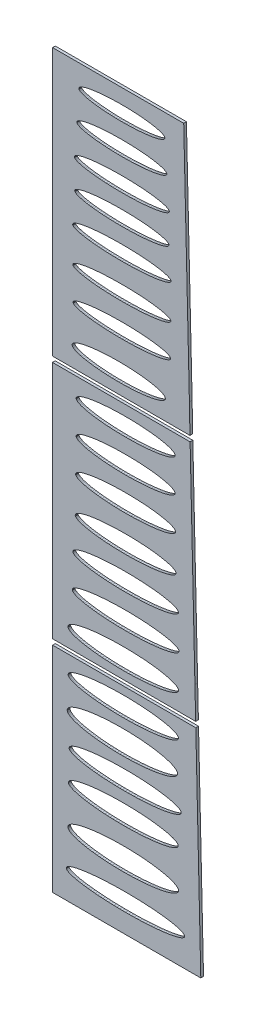
SolidWorks part; units mm, degrees
ref_plane "前视基准面" through (0, 0, 0) normal (0, 0, 1) x (1, 0, 0)
ref_plane "上视基准面" through (0, 0, 0) normal (0, 1, 0) x (1, 0, 0)
ref_plane "右视基准面" through (0, 0, 0) normal (1, 0, 0) x (0, 0, -1)
sketch "Model" plane through (0, 0, 0) normal (0, 0, 1) x (1, 0, 0)
  line L0 (684.8642, 730.8584) -> (686.6354, 654.4405)
  line L1 (634.2684, 732.8584) -> (684.8024, 732.8584)
  line L2 (684.8024, 732.8584) -> (684.6042, 743.4837)
  line L3 (686.6354, 654.4405) -> (686.9159, 642.8584)
  line L4 (686.9625, 640.8584) -> (688.7929, 562.1081)
  line L5 (634.3189, 562.1081) -> (634.3189, 640.8584)
  line L6 (634.3189, 642.8584) -> (686.9159, 642.8584)
  line L7 (688.7929, 562.1081) -> (634.3189, 562.1081)
  line L8 (634.2684, 732.8584) -> (634.3077, 831.1083)
  line L9 (634.3077, 831.1083) -> (682.5124, 831.1083)
  line L10 (634.2684, 730.8584) -> (634.3189, 642.8584)
  line L11 (682.5124, 831.1083) -> (684.6042, 743.4837)
  line L12 (634.3189, 640.8584) -> (686.9625, 640.8584)
  line L13 (634.2684, 730.8584) -> (684.8642, 730.8584)
  line L15 (675.7791, 740.0706) -> (675.7591, 739.9106)
  line L16 (675.7591, 739.9106) -> (675.6991, 739.7506)
  line L17 (675.6991, 739.7506) -> (675.5991, 739.5926)
  line L18 (675.5991, 739.5926) -> (675.4491, 739.4346)
  line L19 (675.4491, 739.4346) -> (675.2691, 739.2776)
  line L20 (675.2691, 739.2776) -> (675.0391, 739.1236)
  line L21 (675.0391, 739.1236) -> (674.7791, 738.9716)
  line L22 (674.7791, 738.9716) -> (674.4791, 738.8216)
  line L23 (674.4791, 738.8216) -> (674.1291, 738.6756)
  line L24 (674.1291, 738.6756) -> (673.7591, 738.5326)
  line L25 (673.7591, 738.5326) -> (673.3391, 738.3926)
  line L26 (673.3391, 738.3926) -> (672.8891, 738.2576)
  line L27 (672.8891, 738.2576) -> (672.4091, 738.1266)
  line L28 (672.4091, 738.1266) -> (671.8891, 738.0006)
  line L29 (671.8891, 738.0006) -> (671.3391, 737.8796)
  line L30 (671.3391, 737.8796) -> (670.7591, 737.7636)
  line L31 (670.7591, 737.7636) -> (670.1491, 737.6526)
  line L32 (670.1491, 737.6526) -> (669.5091, 737.5476)
  line L33 (669.5091, 737.5476) -> (668.8491, 737.4496)
  line L34 (668.8491, 737.4496) -> (668.1591, 737.3576)
  line L35 (668.1591, 737.3576) -> (667.4491, 737.2716)
  line L36 (667.4491, 737.2716) -> (666.7091, 737.1926)
  line L37 (666.7091, 737.1926) -> (665.9591, 737.1206)
  line L38 (665.9591, 737.1206) -> (665.1891, 737.0556)
  line L39 (665.1891, 737.0556) -> (664.4091, 736.9976)
  line L40 (664.4091, 736.9976) -> (663.6091, 736.9476)
  line L41 (663.6091, 736.9476) -> (662.7991, 736.9046)
  line L42 (662.7991, 736.9046) -> (661.9791, 736.8696)
  line L43 (661.9791, 736.8696) -> (661.1491, 736.8426)
  line L44 (661.1491, 736.8426) -> (660.3091, 736.8226)
  line L45 (660.3091, 736.8226) -> (659.4691, 736.8116)
  line L46 (659.4691, 736.8116) -> (658.6291, 736.8076)
  line L47 (658.6291, 736.8076) -> (657.7891, 736.8116)
  line L48 (657.7891, 736.8116) -> (656.9491, 736.8226)
  line L49 (656.9491, 736.8226) -> (656.1091, 736.8426)
  line L50 (656.1091, 736.8426) -> (655.2791, 736.8696)
  line L51 (655.2791, 736.8696) -> (654.4591, 736.9046)
  line L52 (654.4591, 736.9046) -> (653.6491, 736.9476)
  line L53 (653.6491, 736.9476) -> (652.8491, 736.9976)
  line L54 (652.8491, 736.9976) -> (652.0691, 737.0556)
  line L55 (652.0691, 737.0556) -> (651.2991, 737.1206)
  line L56 (651.2991, 737.1206) -> (650.5391, 737.1926)
  line L57 (650.5391, 737.1926) -> (649.8091, 737.2716)
  line L58 (649.8091, 737.2716) -> (649.0991, 737.3576)
  line L59 (649.0991, 737.3576) -> (648.4091, 737.4496)
  line L60 (648.4091, 737.4496) -> (647.7491, 737.5476)
  line L61 (647.7491, 737.5476) -> (647.1091, 737.6526)
  line L62 (647.1091, 737.6526) -> (646.4991, 737.7636)
  line L63 (646.4991, 737.7636) -> (645.9191, 737.8796)
  line L64 (645.9191, 737.8796) -> (645.3691, 738.0006)
  line L65 (645.3691, 738.0006) -> (644.8491, 738.1266)
  line L66 (644.8491, 738.1266) -> (644.3691, 738.2576)
  line L67 (644.3691, 738.2576) -> (643.9191, 738.3926)
  line L68 (643.9191, 738.3926) -> (643.4991, 738.5326)
  line L69 (643.4991, 738.5326) -> (643.1291, 738.6756)
  line L70 (643.1291, 738.6756) -> (642.7791, 738.8216)
  line L71 (642.7791, 738.8216) -> (642.4791, 738.9716)
  line L72 (642.4791, 738.9716) -> (642.2191, 739.1236)
  line L73 (642.2191, 739.1236) -> (641.9891, 739.2776)
  line L74 (641.9891, 739.2776) -> (641.8091, 739.4346)
  line L75 (641.8091, 739.4346) -> (641.6591, 739.5926)
  line L76 (641.6591, 739.5926) -> (641.5591, 739.7506)
  line L77 (641.5591, 739.7506) -> (641.4991, 739.9106)
  line L78 (641.4991, 739.9106) -> (641.4791, 740.0706)
  line L79 (641.4791, 740.0706) -> (641.4991, 740.2316)
  line L80 (641.4991, 740.2316) -> (641.5591, 740.3906)
  line L81 (641.5591, 740.3906) -> (641.6591, 740.5496)
  line L82 (641.6591, 740.5496) -> (641.8091, 740.7076)
  line L83 (641.8091, 740.7076) -> (641.9891, 740.8636)
  line L84 (641.9891, 740.8636) -> (642.2191, 741.0186)
  line L85 (642.2191, 741.0186) -> (642.4791, 741.1706)
  line L86 (642.4791, 741.1706) -> (642.7791, 741.3196)
  line L87 (642.7791, 741.3196) -> (643.1291, 741.4666)
  line L88 (643.1291, 741.4666) -> (643.4991, 741.6096)
  line L89 (643.4991, 741.6096) -> (643.9191, 741.7486)
  line L90 (643.9191, 741.7486) -> (644.3691, 741.8846)
  line L91 (644.3691, 741.8846) -> (644.8491, 742.0156)
  line L92 (644.8491, 742.0156) -> (645.3691, 742.1416)
  line L93 (645.3691, 742.1416) -> (645.9191, 742.2626)
  line L94 (645.9191, 742.2626) -> (646.4991, 742.3786)
  line L95 (646.4991, 742.3786) -> (647.1091, 742.4896)
  line L96 (647.1091, 742.4896) -> (647.7491, 742.5936)
  line L97 (647.7491, 742.5936) -> (648.4091, 742.6926)
  line L98 (648.4091, 742.6926) -> (649.0991, 742.7846)
  line L99 (649.0991, 742.7846) -> (649.8091, 742.8706)
  line L100 (649.8091, 742.8706) -> (650.5391, 742.9496)
  line L101 (650.5391, 742.9496) -> (651.2991, 743.0216)
  line L102 (651.2991, 743.0216) -> (652.0691, 743.0866)
  line L103 (652.0691, 743.0866) -> (652.8491, 743.1436)
  line L104 (652.8491, 743.1436) -> (653.6491, 743.1946)
  line L105 (653.6491, 743.1946) -> (654.4591, 743.2366)
  line L106 (654.4591, 743.2366) -> (655.2791, 743.2716)
  line L107 (655.2791, 743.2716) -> (656.1091, 743.2996)
  line L108 (656.1091, 743.2996) -> (656.9491, 743.3186)
  line L109 (656.9491, 743.3186) -> (657.7891, 743.3306)
  line L110 (657.7891, 743.3306) -> (658.6291, 743.3346)
  line L111 (658.6291, 743.3346) -> (659.4691, 743.3306)
  line L112 (659.4691, 743.3306) -> (660.3091, 743.3186)
  line L113 (660.3091, 743.3186) -> (661.1491, 743.2996)
  line L114 (661.1491, 743.2996) -> (661.9791, 743.2716)
  line L115 (661.9791, 743.2716) -> (662.7991, 743.2366)
  line L116 (662.7991, 743.2366) -> (663.6091, 743.1946)
  line L117 (663.6091, 743.1946) -> (664.4091, 743.1436)
  line L118 (664.4091, 743.1436) -> (665.1891, 743.0866)
  line L119 (665.1891, 743.0866) -> (665.9591, 743.0216)
  line L120 (665.9591, 743.0216) -> (666.7091, 742.9496)
  line L121 (666.7091, 742.9496) -> (667.4491, 742.8706)
  line L122 (667.4491, 742.8706) -> (668.1591, 742.7846)
  line L123 (668.1591, 742.7846) -> (668.8491, 742.6926)
  line L124 (668.8491, 742.6926) -> (669.5091, 742.5936)
  line L125 (669.5091, 742.5936) -> (670.1491, 742.4896)
  line L126 (670.1491, 742.4896) -> (670.7591, 742.3786)
  line L127 (670.7591, 742.3786) -> (671.3391, 742.2626)
  line L128 (671.3391, 742.2626) -> (671.8891, 742.1416)
  line L129 (671.8891, 742.1416) -> (672.4091, 742.0156)
  line L130 (672.4091, 742.0156) -> (672.8891, 741.8846)
  line L131 (672.8891, 741.8846) -> (673.3391, 741.7486)
  line L132 (673.3391, 741.7486) -> (673.7591, 741.6096)
  line L133 (673.7591, 741.6096) -> (674.1291, 741.4666)
  line L134 (674.1291, 741.4666) -> (674.4791, 741.3196)
  line L135 (674.4791, 741.3196) -> (674.7791, 741.1706)
  line L136 (674.7791, 741.1706) -> (675.0391, 741.0186)
  line L137 (675.0391, 741.0186) -> (675.2691, 740.8636)
  line L138 (675.2691, 740.8636) -> (675.4491, 740.7076)
  line L139 (675.4491, 740.7076) -> (675.5991, 740.5496)
  line L140 (675.5991, 740.5496) -> (675.6991, 740.3906)
  line L141 (675.6991, 740.3906) -> (675.7591, 740.2316)
  line L142 (675.7591, 740.2316) -> (675.7791, 740.0706)
  line L143 (679.368, 723.7726) -> (679.348, 723.6116)
  line L144 (679.348, 723.6116) -> (679.278, 723.4526)
  line L145 (679.278, 723.4526) -> (679.168, 723.2936)
  line L146 (679.168, 723.2936) -> (679.018, 723.1356)
  line L147 (679.018, 723.1356) -> (678.828, 722.9796)
  line L148 (678.828, 722.9796) -> (678.588, 722.8246)
  line L149 (678.588, 722.8246) -> (678.308, 722.6726)
  line L150 (678.308, 722.6726) -> (677.978, 722.5236)
  line L151 (677.978, 722.5236) -> (677.618, 722.3766)
  line L152 (677.618, 722.3766) -> (677.218, 722.2336)
  line L153 (677.218, 722.2336) -> (676.778, 722.0946)
  line L154 (676.778, 722.0946) -> (676.298, 721.9586)
  line L155 (676.298, 721.9586) -> (675.788, 721.8276)
  line L156 (675.788, 721.8276) -> (675.238, 721.7016)
  line L157 (675.238, 721.7016) -> (674.648, 721.5806)
  line L158 (674.648, 721.5806) -> (674.038, 721.4646)
  line L159 (674.038, 721.4646) -> (673.388, 721.3536)
  line L160 (673.388, 721.3536) -> (672.708, 721.2496)
  line L161 (672.708, 721.2496) -> (672.008, 721.1506)
  line L162 (672.008, 721.1506) -> (671.278, 721.0586)
  line L163 (671.278, 721.0586) -> (670.518, 720.9726)
  line L164 (670.518, 720.9726) -> (669.748, 720.8936)
  line L165 (669.748, 720.8936) -> (668.948, 720.8216)
  line L166 (668.948, 720.8216) -> (668.128, 720.7566)
  line L167 (668.128, 720.7566) -> (667.298, 720.6996)
  line L168 (667.298, 720.6996) -> (666.448, 720.6486)
  line L169 (666.448, 720.6486) -> (665.588, 720.6066)
  line L170 (665.588, 720.6066) -> (664.718, 720.5706)
  line L171 (664.718, 720.5706) -> (663.838, 720.5436)
  line L172 (663.838, 720.5436) -> (662.948, 720.5236)
  line L173 (662.948, 720.5236) -> (662.058, 720.5126)
  line L174 (662.058, 720.5126) -> (661.158, 720.5086)
  line L175 (661.158, 720.5086) -> (660.268, 720.5126)
  line L176 (660.268, 720.5126) -> (659.378, 720.5236)
  line L177 (659.378, 720.5236) -> (658.488, 720.5436)
  line L178 (658.488, 720.5436) -> (657.608, 720.5706)
  line L179 (657.608, 720.5706) -> (656.738, 720.6066)
  line L180 (656.738, 720.6066) -> (655.878, 720.6486)
  line L181 (655.878, 720.6486) -> (655.028, 720.6996)
  line L182 (655.028, 720.6996) -> (654.198, 720.7566)
  line L183 (654.198, 720.7566) -> (653.378, 720.8216)
  line L184 (653.378, 720.8216) -> (652.578, 720.8936)
  line L185 (652.578, 720.8936) -> (651.798, 720.9726)
  line L186 (651.798, 720.9726) -> (651.048, 721.0586)
  line L187 (651.048, 721.0586) -> (650.318, 721.1506)
  line L188 (650.318, 721.1506) -> (649.608, 721.2496)
  line L189 (649.608, 721.2496) -> (648.938, 721.3536)
  line L190 (648.938, 721.3536) -> (648.288, 721.4646)
  line L191 (648.288, 721.4646) -> (647.668, 721.5806)
  line L192 (647.668, 721.5806) -> (647.088, 721.7016)
  line L193 (647.088, 721.7016) -> (646.538, 721.8276)
  line L194 (646.538, 721.8276) -> (646.028, 721.9586)
  line L195 (646.028, 721.9586) -> (645.548, 722.0946)
  line L196 (645.548, 722.0946) -> (645.108, 722.2336)
  line L197 (645.108, 722.2336) -> (644.708, 722.3766)
  line L198 (644.708, 722.3766) -> (644.338, 722.5236)
  line L199 (644.338, 722.5236) -> (644.018, 722.6726)
  line L200 (644.018, 722.6726) -> (643.738, 722.8246)
  line L201 (643.738, 722.8246) -> (643.498, 722.9796)
  line L202 (643.498, 722.9796) -> (643.308, 723.1356)
  line L203 (643.308, 723.1356) -> (643.158, 723.2936)
  line L204 (643.158, 723.2936) -> (643.048, 723.4526)
  line L205 (643.048, 723.4526) -> (642.978, 723.6116)
  line L206 (642.978, 723.6116) -> (642.958, 723.7726)
  line L207 (642.958, 723.7726) -> (642.978, 723.9326)
  line L208 (642.978, 723.9326) -> (643.048, 724.0916)
  line L209 (643.048, 724.0916) -> (643.158, 724.2506)
  line L210 (643.158, 724.2506) -> (643.308, 724.4086)
  line L211 (643.308, 724.4086) -> (643.498, 724.5656)
  line L212 (643.498, 724.5656) -> (643.738, 724.7196)
  line L213 (643.738, 724.7196) -> (644.018, 724.8716)
  line L214 (644.018, 724.8716) -> (644.338, 725.0216)
  line L215 (644.338, 725.0216) -> (644.708, 725.1676)
  line L216 (644.708, 725.1676) -> (645.108, 725.3106)
  line L217 (645.108, 725.3106) -> (645.548, 725.4496)
  line L218 (645.548, 725.4496) -> (646.028, 725.5856)
  line L219 (646.028, 725.5856) -> (646.538, 725.7166)
  line L220 (646.538, 725.7166) -> (647.088, 725.8426)
  line L221 (647.088, 725.8426) -> (647.668, 725.9636)
  line L222 (647.668, 725.9636) -> (648.288, 726.0796)
  line L223 (648.288, 726.0796) -> (648.938, 726.1906)
  line L224 (648.938, 726.1906) -> (649.608, 726.2946)
  line L225 (649.608, 726.2946) -> (650.318, 726.3936)
  line L226 (650.318, 726.3936) -> (651.048, 726.4856)
  line L227 (651.048, 726.4856) -> (651.798, 726.5716)
  line L228 (651.798, 726.5716) -> (652.578, 726.6506)
  line L229 (652.578, 726.6506) -> (653.378, 726.7226)
  line L230 (653.378, 726.7226) -> (654.198, 726.7876)
  line L231 (654.198, 726.7876) -> (655.028, 726.8456)
  line L232 (655.028, 726.8456) -> (655.878, 726.8956)
  line L233 (655.878, 726.8956) -> (656.738, 726.9386)
  line L234 (656.738, 726.9386) -> (657.608, 726.9736)
  line L235 (657.608, 726.9736) -> (658.488, 727.0006)
  line L236 (658.488, 727.0006) -> (659.378, 727.0206)
  line L237 (659.378, 727.0206) -> (660.268, 727.0316)
  line L238 (660.268, 727.0316) -> (661.158, 727.0356)
  line L239 (661.158, 727.0356) -> (662.058, 727.0316)
  line L240 (662.058, 727.0316) -> (662.948, 727.0206)
  line L241 (662.948, 727.0206) -> (663.838, 727.0006)
  line L242 (663.838, 727.0006) -> (664.718, 726.9736)
  line L243 (664.718, 726.9736) -> (665.588, 726.9386)
  line L244 (665.588, 726.9386) -> (666.448, 726.8956)
  line L245 (666.448, 726.8956) -> (667.298, 726.8456)
  line L246 (667.298, 726.8456) -> (668.128, 726.7876)
  line L247 (668.128, 726.7876) -> (668.948, 726.7226)
  line L248 (668.948, 726.7226) -> (669.748, 726.6506)
  line L249 (669.748, 726.6506) -> (670.518, 726.5716)
  line L250 (670.518, 726.5716) -> (671.278, 726.4856)
  line L251 (671.278, 726.4856) -> (672.008, 726.3936)
  line L252 (672.008, 726.3936) -> (672.708, 726.2946)
  line L253 (672.708, 726.2946) -> (673.388, 726.1906)
  line L254 (673.388, 726.1906) -> (674.038, 726.0796)
  line L255 (674.038, 726.0796) -> (674.648, 725.9636)
  line L256 (674.648, 725.9636) -> (675.238, 725.8426)
  line L257 (675.238, 725.8426) -> (675.788, 725.7166)
  line L258 (675.788, 725.7166) -> (676.298, 725.5856)
  line L259 (676.298, 725.5856) -> (676.778, 725.4496)
  line L260 (676.778, 725.4496) -> (677.218, 725.3106)
  line L261 (677.218, 725.3106) -> (677.618, 725.1676)
  line L262 (677.618, 725.1676) -> (677.978, 725.0216)
  line L263 (677.978, 725.0216) -> (678.308, 724.8716)
  line L264 (678.308, 724.8716) -> (678.588, 724.7196)
  line L265 (678.588, 724.7196) -> (678.828, 724.5656)
  line L266 (678.828, 724.5656) -> (679.018, 724.4086)
  line L267 (679.018, 724.4086) -> (679.168, 724.2506)
  line L268 (679.168, 724.2506) -> (679.278, 724.0916)
  line L269 (679.278, 724.0916) -> (679.348, 723.9326)
  line L270 (679.348, 723.9326) -> (679.368, 723.7726)
  line L271 (679.368, 711.7136) -> (679.348, 711.5536)
  line L272 (679.348, 711.5536) -> (679.278, 711.3936)
  line L273 (679.278, 711.3936) -> (679.168, 711.2356)
  line L274 (679.168, 711.2356) -> (679.018, 711.0776)
  line L275 (679.018, 711.0776) -> (678.828, 710.9206)
  line L276 (678.828, 710.9206) -> (678.588, 710.7666)
  line L277 (678.588, 710.7666) -> (678.308, 710.6146)
  line L278 (678.308, 710.6146) -> (677.978, 710.4646)
  line L279 (677.978, 710.4646) -> (677.618, 710.3186)
  line L280 (677.618, 710.3186) -> (677.218, 710.1756)
  line L281 (677.218, 710.1756) -> (676.778, 710.0356)
  line L282 (676.778, 710.0356) -> (676.298, 709.9006)
  line L283 (676.298, 709.9006) -> (675.788, 709.7696)
  line L284 (675.788, 709.7696) -> (675.238, 709.6436)
  line L285 (675.238, 709.6436) -> (674.648, 709.5226)
  line L286 (674.648, 709.5226) -> (674.038, 709.4066)
  line L287 (674.038, 709.4066) -> (673.388, 709.2956)
  line L288 (673.388, 709.2956) -> (672.708, 709.1906)
  line L289 (672.708, 709.1906) -> (672.008, 709.0926)
  line L290 (672.008, 709.0926) -> (671.278, 709.0006)
  line L291 (671.278, 709.0006) -> (670.518, 708.9146)
  line L292 (670.518, 708.9146) -> (669.748, 708.8356)
  line L293 (669.748, 708.8356) -> (668.948, 708.7636)
  line L294 (668.948, 708.7636) -> (668.128, 708.6986)
  line L295 (668.128, 708.6986) -> (667.298, 708.6406)
  line L296 (667.298, 708.6406) -> (666.448, 708.5906)
  line L297 (666.448, 708.5906) -> (665.588, 708.5476)
  line L298 (665.588, 708.5476) -> (664.718, 708.5126)
  line L299 (664.718, 708.5126) -> (663.838, 708.4856)
  line L300 (663.838, 708.4856) -> (662.948, 708.4656)
  line L301 (662.948, 708.4656) -> (662.058, 708.4546)
  line L302 (662.058, 708.4546) -> (661.158, 708.4506)
  line L303 (661.158, 708.4506) -> (660.268, 708.4546)
  line L304 (660.268, 708.4546) -> (659.378, 708.4656)
  line L305 (659.378, 708.4656) -> (658.488, 708.4856)
  line L306 (658.488, 708.4856) -> (657.608, 708.5126)
  line L307 (657.608, 708.5126) -> (656.738, 708.5476)
  line L308 (656.738, 708.5476) -> (655.878, 708.5906)
  line L309 (655.878, 708.5906) -> (655.028, 708.6406)
  line L310 (655.028, 708.6406) -> (654.198, 708.6986)
  line L311 (654.198, 708.6986) -> (653.378, 708.7636)
  line L312 (653.378, 708.7636) -> (652.578, 708.8356)
  line L313 (652.578, 708.8356) -> (651.798, 708.9146)
  line L314 (651.798, 708.9146) -> (651.048, 709.0006)
  line L315 (651.048, 709.0006) -> (650.318, 709.0926)
  line L316 (650.318, 709.0926) -> (649.608, 709.1906)
  line L317 (649.608, 709.1906) -> (648.938, 709.2956)
  line L318 (648.938, 709.2956) -> (648.288, 709.4066)
  line L319 (648.288, 709.4066) -> (647.668, 709.5226)
  line L320 (647.668, 709.5226) -> (647.088, 709.6436)
  line L321 (647.088, 709.6436) -> (646.538, 709.7696)
  line L322 (646.538, 709.7696) -> (646.028, 709.9006)
  line L323 (646.028, 709.9006) -> (645.548, 710.0356)
  line L324 (645.548, 710.0356) -> (645.108, 710.1756)
  line L325 (645.108, 710.1756) -> (644.708, 710.3186)
  line L326 (644.708, 710.3186) -> (644.338, 710.4646)
  line L327 (644.338, 710.4646) -> (644.018, 710.6146)
  line L328 (644.018, 710.6146) -> (643.738, 710.7666)
  line L329 (643.738, 710.7666) -> (643.498, 710.9206)
  line L330 (643.498, 710.9206) -> (643.308, 711.0776)
  line L331 (643.308, 711.0776) -> (643.158, 711.2356)
  line L332 (643.158, 711.2356) -> (643.048, 711.3936)
  line L333 (643.048, 711.3936) -> (642.978, 711.5536)
  line L334 (642.978, 711.5536) -> (642.958, 711.7136)
  line L335 (642.958, 711.7136) -> (642.978, 711.8746)
  line L336 (642.978, 711.8746) -> (643.048, 712.0336)
  line L337 (643.048, 712.0336) -> (643.158, 712.1926)
  line L338 (643.158, 712.1926) -> (643.308, 712.3506)
  line L339 (643.308, 712.3506) -> (643.498, 712.5066)
  line L340 (643.498, 712.5066) -> (643.738, 712.6616)
  line L341 (643.738, 712.6616) -> (644.018, 712.8136)
  line L342 (644.018, 712.8136) -> (644.338, 712.9626)
  line L343 (644.338, 712.9626) -> (644.708, 713.1096)
  line L344 (644.708, 713.1096) -> (645.108, 713.2526)
  line L345 (645.108, 713.2526) -> (645.548, 713.3916)
  line L346 (645.548, 713.3916) -> (646.028, 713.5276)
  line L347 (646.028, 713.5276) -> (646.538, 713.6586)
  line L348 (646.538, 713.6586) -> (647.088, 713.7846)
  line L349 (647.088, 713.7846) -> (647.668, 713.9056)
  line L350 (647.668, 713.9056) -> (648.288, 714.0216)
  line L351 (648.288, 714.0216) -> (648.938, 714.1326)
  line L352 (648.938, 714.1326) -> (649.608, 714.2366)
  line L353 (649.608, 714.2366) -> (650.318, 714.3356)
  line L354 (650.318, 714.3356) -> (651.048, 714.4276)
  line L355 (651.048, 714.4276) -> (651.798, 714.5136)
  line L356 (651.798, 714.5136) -> (652.578, 714.5926)
  line L357 (652.578, 714.5926) -> (653.378, 714.6646)
  line L358 (653.378, 714.6646) -> (654.198, 714.7296)
  line L359 (654.198, 714.7296) -> (655.028, 714.7866)
  line L360 (655.028, 714.7866) -> (655.878, 714.8376)
  line L361 (655.878, 714.8376) -> (656.738, 714.8796)
  line L362 (656.738, 714.8796) -> (657.608, 714.9146)
  line L363 (657.608, 714.9146) -> (658.488, 714.9426)
  line L364 (658.488, 714.9426) -> (659.378, 714.9616)
  line L365 (659.378, 714.9616) -> (660.268, 714.9736)
  line L366 (660.268, 714.9736) -> (661.158, 714.9776)
  line L367 (661.158, 714.9776) -> (662.058, 714.9736)
  line L368 (662.058, 714.9736) -> (662.948, 714.9616)
  line L369 (662.948, 714.9616) -> (663.838, 714.9426)
  line L370 (663.838, 714.9426) -> (664.718, 714.9146)
  line L371 (664.718, 714.9146) -> (665.588, 714.8796)
  line L372 (665.588, 714.8796) -> (666.448, 714.8376)
  line L373 (666.448, 714.8376) -> (667.298, 714.7866)
  line L374 (667.298, 714.7866) -> (668.128, 714.7296)
  line L375 (668.128, 714.7296) -> (668.948, 714.6646)
  line L376 (668.948, 714.6646) -> (669.748, 714.5926)
  line L377 (669.748, 714.5926) -> (670.518, 714.5136)
  line L378 (670.518, 714.5136) -> (671.278, 714.4276)
  line L379 (671.278, 714.4276) -> (672.008, 714.3356)
  line L380 (672.008, 714.3356) -> (672.708, 714.2366)
  line L381 (672.708, 714.2366) -> (673.388, 714.1326)
  line L382 (673.388, 714.1326) -> (674.038, 714.0216)
  line L383 (674.038, 714.0216) -> (674.648, 713.9056)
  line L384 (674.648, 713.9056) -> (675.238, 713.7846)
  line L385 (675.238, 713.7846) -> (675.788, 713.6586)
  line L386 (675.788, 713.6586) -> (676.298, 713.5276)
  line L387 (676.298, 713.5276) -> (676.778, 713.3916)
  line L388 (676.778, 713.3916) -> (677.218, 713.2526)
  line L389 (677.218, 713.2526) -> (677.618, 713.1096)
  line L390 (677.618, 713.1096) -> (677.978, 712.9626)
  line L391 (677.978, 712.9626) -> (678.308, 712.8136)
  line L392 (678.308, 712.8136) -> (678.588, 712.6616)
  line L393 (678.588, 712.6616) -> (678.828, 712.5066)
  line L394 (678.828, 712.5066) -> (679.018, 712.3506)
  line L395 (679.018, 712.3506) -> (679.168, 712.1926)
  line L396 (679.168, 712.1926) -> (679.278, 712.0336)
  line L397 (679.278, 712.0336) -> (679.348, 711.8746)
  line L398 (679.348, 711.8746) -> (679.368, 711.7136)
  line L399 (679.538, 699.5345) -> (679.518, 699.3735)
  line L400 (679.518, 699.3735) -> (679.448, 699.2145)
  line L401 (679.448, 699.2145) -> (679.338, 699.0555)
  line L402 (679.338, 699.0555) -> (679.178, 698.8975)
  line L403 (679.178, 698.8975) -> (678.988, 698.7415)
  line L404 (678.988, 698.7415) -> (678.748, 698.5865)
  line L405 (678.748, 698.5865) -> (678.458, 698.4345)
  line L406 (678.458, 698.4345) -> (678.138, 698.2855)
  line L407 (678.138, 698.2855) -> (677.768, 698.1385)
  line L408 (677.768, 698.1385) -> (677.368, 697.9955)
  line L409 (677.368, 697.9955) -> (676.918, 697.8565)
  line L410 (676.918, 697.8565) -> (676.438, 697.7205)
  line L411 (676.438, 697.7205) -> (675.918, 697.5895)
  line L412 (675.918, 697.5895) -> (675.368, 697.4635)
  line L413 (675.368, 697.4635) -> (674.778, 697.3425)
  line L414 (674.778, 697.3425) -> (674.158, 697.2265)
  line L415 (674.158, 697.2265) -> (673.498, 697.1155)
  line L416 (673.498, 697.1155) -> (672.818, 697.0115)
  line L417 (672.818, 697.0115) -> (672.108, 696.9125)
  line L418 (672.108, 696.9125) -> (671.368, 696.8205)
  line L419 (671.368, 696.8205) -> (670.608, 696.7345)
  line L420 (670.608, 696.7345) -> (669.828, 696.6555)
  line L421 (669.828, 696.6555) -> (669.018, 696.5835)
  line L422 (669.018, 696.5835) -> (668.198, 696.5185)
  line L423 (668.198, 696.5185) -> (667.348, 696.4615)
  line L424 (667.348, 696.4615) -> (666.498, 696.4105)
  line L425 (666.498, 696.4105) -> (665.628, 696.3685)
  line L426 (665.628, 696.3685) -> (664.748, 696.3335)
  line L427 (664.748, 696.3335) -> (663.858, 696.3055)
  line L428 (663.858, 696.3055) -> (662.968, 696.2865)
  line L429 (662.968, 696.2865) -> (662.068, 696.2745)
  line L430 (662.068, 696.2745) -> (661.158, 696.2705)
  line L431 (661.158, 696.2705) -> (660.258, 696.2745)
  line L432 (660.258, 696.2745) -> (659.358, 696.2865)
  line L433 (659.358, 696.2865) -> (658.468, 696.3055)
  line L434 (658.468, 696.3055) -> (657.578, 696.3335)
  line L435 (657.578, 696.3335) -> (656.698, 696.3685)
  line L436 (656.698, 696.3685) -> (655.828, 696.4105)
  line L437 (655.828, 696.4105) -> (654.968, 696.4615)
  line L438 (654.968, 696.4615) -> (654.128, 696.5185)
  line L439 (654.128, 696.5185) -> (653.308, 696.5835)
  line L440 (653.308, 696.5835) -> (652.498, 696.6555)
  line L441 (652.498, 696.6555) -> (651.718, 696.7345)
  line L442 (651.718, 696.7345) -> (650.958, 696.8205)
  line L443 (650.958, 696.8205) -> (650.218, 696.9125)
  line L444 (650.218, 696.9125) -> (649.508, 697.0115)
  line L445 (649.508, 697.0115) -> (648.828, 697.1155)
  line L446 (648.828, 697.1155) -> (648.168, 697.2265)
  line L447 (648.168, 697.2265) -> (647.548, 697.3425)
  line L448 (647.548, 697.3425) -> (646.958, 697.4635)
  line L449 (646.958, 697.4635) -> (646.408, 697.5895)
  line L450 (646.408, 697.5895) -> (645.888, 697.7205)
  line L451 (645.888, 697.7205) -> (645.408, 697.8565)
  line L452 (645.408, 697.8565) -> (644.958, 697.9955)
  line L453 (644.958, 697.9955) -> (644.558, 698.1385)
  line L454 (644.558, 698.1385) -> (644.188, 698.2855)
  line L455 (644.188, 698.2855) -> (643.868, 698.4345)
  line L456 (643.868, 698.4345) -> (643.578, 698.5865)
  line L457 (643.578, 698.5865) -> (643.338, 698.7415)
  line L458 (643.338, 698.7415) -> (643.138, 698.8975)
  line L459 (643.138, 698.8975) -> (642.988, 699.0555)
  line L460 (642.988, 699.0555) -> (642.878, 699.2145)
  line L461 (642.878, 699.2145) -> (642.808, 699.3735)
  line L462 (642.808, 699.3735) -> (642.788, 699.5345)
  line L463 (642.788, 699.5345) -> (642.808, 699.6945)
  line L464 (642.808, 699.6945) -> (642.878, 699.8535)
  line L465 (642.878, 699.8535) -> (642.988, 700.0125)
  line L466 (642.988, 700.0125) -> (643.138, 700.1705)
  line L467 (643.138, 700.1705) -> (643.338, 700.3275)
  line L468 (643.338, 700.3275) -> (643.578, 700.4815)
  line L469 (643.578, 700.4815) -> (643.868, 700.6335)
  line L470 (643.868, 700.6335) -> (644.188, 700.7835)
  line L471 (644.188, 700.7835) -> (644.558, 700.9295)
  line L472 (644.558, 700.9295) -> (644.958, 701.0725)
  line L473 (644.958, 701.0725) -> (645.408, 701.2115)
  line L474 (645.408, 701.2115) -> (645.888, 701.3475)
  line L475 (645.888, 701.3475) -> (646.408, 701.4785)
  line L476 (646.408, 701.4785) -> (646.958, 701.6045)
  line L477 (646.958, 701.6045) -> (647.548, 701.7255)
  line L478 (647.548, 701.7255) -> (648.168, 701.8415)
  line L479 (648.168, 701.8415) -> (648.828, 701.9525)
  line L480 (648.828, 701.9525) -> (649.508, 702.0565)
  line L481 (649.508, 702.0565) -> (650.218, 702.1555)
  line L482 (650.218, 702.1555) -> (650.958, 702.2475)
  line L483 (650.958, 702.2475) -> (651.718, 702.3335)
  line L484 (651.718, 702.3335) -> (652.498, 702.4125)
  line L485 (652.498, 702.4125) -> (653.308, 702.4845)
  line L486 (653.308, 702.4845) -> (654.128, 702.5495)
  line L487 (654.128, 702.5495) -> (654.968, 702.6075)
  line L488 (654.968, 702.6075) -> (655.828, 702.6575)
  line L489 (655.828, 702.6575) -> (656.698, 702.7005)
  line L490 (656.698, 702.7005) -> (657.578, 702.7355)
  line L491 (657.578, 702.7355) -> (658.468, 702.7625)
  line L492 (658.468, 702.7625) -> (659.358, 702.7825)
  line L493 (659.358, 702.7825) -> (660.258, 702.7935)
  line L494 (660.258, 702.7935) -> (661.158, 702.7975)
  line L495 (661.158, 702.7975) -> (662.068, 702.7935)
  line L496 (662.068, 702.7935) -> (662.968, 702.7825)
  line L497 (662.968, 702.7825) -> (663.858, 702.7625)
  line L498 (663.858, 702.7625) -> (664.748, 702.7355)
  line L499 (664.748, 702.7355) -> (665.628, 702.7005)
  line L500 (665.628, 702.7005) -> (666.498, 702.6575)
  line L501 (666.498, 702.6575) -> (667.348, 702.6075)
  line L502 (667.348, 702.6075) -> (668.198, 702.5495)
  line L503 (668.198, 702.5495) -> (669.018, 702.4845)
  line L504 (669.018, 702.4845) -> (669.828, 702.4125)
  line L505 (669.828, 702.4125) -> (670.608, 702.3335)
  line L506 (670.608, 702.3335) -> (671.368, 702.2475)
  line L507 (671.368, 702.2475) -> (672.108, 702.1555)
  line L508 (672.108, 702.1555) -> (672.818, 702.0565)
  line L509 (672.818, 702.0565) -> (673.498, 701.9525)
  line L510 (673.498, 701.9525) -> (674.158, 701.8415)
  line L511 (674.158, 701.8415) -> (674.778, 701.7255)
  line L512 (674.778, 701.7255) -> (675.368, 701.6045)
  line L513 (675.368, 701.6045) -> (675.918, 701.4785)
  line L514 (675.918, 701.4785) -> (676.438, 701.3475)
  line L515 (676.438, 701.3475) -> (676.918, 701.2115)
  line L516 (676.918, 701.2115) -> (677.368, 701.0725)
  line L517 (677.368, 701.0725) -> (677.768, 700.9295)
  line L518 (677.768, 700.9295) -> (678.138, 700.7835)
  line L519 (678.138, 700.7835) -> (678.458, 700.6335)
  line L520 (678.458, 700.6335) -> (678.748, 700.4815)
  line L521 (678.748, 700.4815) -> (678.988, 700.3275)
  line L522 (678.988, 700.3275) -> (679.178, 700.1705)
  line L523 (679.178, 700.1705) -> (679.338, 700.0125)
  line L524 (679.338, 700.0125) -> (679.448, 699.8535)
  line L525 (679.448, 699.8535) -> (679.518, 699.6945)
  line L526 (679.518, 699.6945) -> (679.538, 699.5345)
  line L527 (679.698, 686.4235) -> (679.678, 686.2635)
  line L528 (679.678, 686.2635) -> (679.618, 686.1035)
  line L529 (679.618, 686.1035) -> (679.498, 685.9445)
  line L530 (679.498, 685.9445) -> (679.348, 685.7865)
  line L531 (679.348, 685.7865) -> (679.148, 685.6305)
  line L532 (679.148, 685.6305) -> (678.908, 685.4765)
  line L533 (678.908, 685.4765) -> (678.618, 685.3235)
  line L534 (678.618, 685.3235) -> (678.288, 685.1745)
  line L535 (678.288, 685.1745) -> (677.918, 685.0285)
  line L536 (677.918, 685.0285) -> (677.518, 684.8845)
  line L537 (677.518, 684.8845) -> (677.068, 684.7455)
  line L538 (677.068, 684.7455) -> (676.578, 684.6105)
  line L539 (676.578, 684.6105) -> (676.058, 684.4795)
  line L540 (676.058, 684.4795) -> (675.498, 684.3535)
  line L541 (675.498, 684.3535) -> (674.898, 684.2315)
  line L542 (674.898, 684.2315) -> (674.268, 684.1155)
  line L543 (674.268, 684.1155) -> (673.618, 684.0055)
  line L544 (673.618, 684.0055) -> (672.928, 683.9005)
  line L545 (672.928, 683.9005) -> (672.208, 683.8025)
  line L546 (672.208, 683.8025) -> (671.458, 683.7095)
  line L547 (671.458, 683.7095) -> (670.698, 683.6245)
  line L548 (670.698, 683.6245) -> (669.898, 683.5455)
  line L549 (669.898, 683.5455) -> (669.088, 683.4735)
  line L550 (669.088, 683.4735) -> (668.258, 683.4085)
  line L551 (668.258, 683.4085) -> (667.408, 683.3505)
  line L552 (667.408, 683.3505) -> (666.548, 683.3005)
  line L553 (666.548, 683.3005) -> (665.668, 683.2575)
  line L554 (665.668, 683.2575) -> (664.778, 683.2225)
  line L555 (664.778, 683.2225) -> (663.878, 683.1955)
  line L556 (663.878, 683.1955) -> (662.978, 683.1755)
  line L557 (662.978, 683.1755) -> (662.068, 683.1635)
  line L558 (662.068, 683.1635) -> (661.158, 683.1595)
  line L559 (661.158, 683.1595) -> (660.248, 683.1635)
  line L560 (660.248, 683.1635) -> (659.348, 683.1755)
  line L561 (659.348, 683.1755) -> (658.438, 683.1955)
  line L562 (658.438, 683.1955) -> (657.548, 683.2225)
  line L563 (657.548, 683.2225) -> (656.658, 683.2575)
  line L564 (656.658, 683.2575) -> (655.778, 683.3005)
  line L565 (655.778, 683.3005) -> (654.918, 683.3505)
  line L566 (654.918, 683.3505) -> (654.068, 683.4085)
  line L567 (654.068, 683.4085) -> (653.238, 683.4735)
  line L568 (653.238, 683.4735) -> (652.418, 683.5455)
  line L569 (652.418, 683.5455) -> (651.628, 683.6245)
  line L570 (651.628, 683.6245) -> (650.858, 683.7095)
  line L571 (650.858, 683.7095) -> (650.118, 683.8025)
  line L572 (650.118, 683.8025) -> (649.398, 683.9005)
  line L573 (649.398, 683.9005) -> (648.708, 684.0055)
  line L574 (648.708, 684.0055) -> (648.048, 684.1155)
  line L575 (648.048, 684.1155) -> (647.428, 684.2315)
  line L576 (647.428, 684.2315) -> (646.828, 684.3535)
  line L577 (646.828, 684.3535) -> (646.268, 684.4795)
  line L578 (646.268, 684.4795) -> (645.748, 684.6105)
  line L579 (645.748, 684.6105) -> (645.258, 684.7455)
  line L580 (645.258, 684.7455) -> (644.808, 684.8845)
  line L581 (644.808, 684.8845) -> (644.398, 685.0285)
  line L582 (644.398, 685.0285) -> (644.038, 685.1745)
  line L583 (644.038, 685.1745) -> (643.708, 685.3235)
  line L584 (643.708, 685.3235) -> (643.418, 685.4765)
  line L585 (643.418, 685.4765) -> (643.178, 685.6305)
  line L586 (643.178, 685.6305) -> (642.978, 685.7865)
  line L587 (642.978, 685.7865) -> (642.828, 685.9445)
  line L588 (642.828, 685.9445) -> (642.708, 686.1035)
  line L589 (642.708, 686.1035) -> (642.648, 686.2635)
  line L590 (642.648, 686.2635) -> (642.618, 686.4235)
  line L591 (642.618, 686.4235) -> (642.648, 686.5835)
  line L592 (642.648, 686.5835) -> (642.708, 686.7435)
  line L593 (642.708, 686.7435) -> (642.828, 686.9025)
  line L594 (642.828, 686.9025) -> (642.978, 687.0605)
  line L595 (642.978, 687.0605) -> (643.178, 687.2165)
  line L596 (643.178, 687.2165) -> (643.418, 687.3705)
  line L597 (643.418, 687.3705) -> (643.708, 687.5235)
  line L598 (643.708, 687.5235) -> (644.038, 687.6725)
  line L599 (644.038, 687.6725) -> (644.398, 687.8185)
  line L600 (644.398, 687.8185) -> (644.808, 687.9625)
  line L601 (644.808, 687.9625) -> (645.258, 688.1015)
  line L602 (645.258, 688.1015) -> (645.748, 688.2365)
  line L603 (645.748, 688.2365) -> (646.268, 688.3675)
  line L604 (646.268, 688.3675) -> (646.828, 688.4945)
  line L605 (646.828, 688.4945) -> (647.428, 688.6155)
  line L606 (647.428, 688.6155) -> (648.048, 688.7315)
  line L607 (648.048, 688.7315) -> (648.708, 688.8415)
  line L608 (648.708, 688.8415) -> (649.398, 688.9465)
  line L609 (649.398, 688.9465) -> (650.118, 689.0455)
  line L610 (650.118, 689.0455) -> (650.858, 689.1375)
  line L611 (650.858, 689.1375) -> (651.628, 689.2225)
  line L612 (651.628, 689.2225) -> (652.418, 689.3015)
  line L613 (652.418, 689.3015) -> (653.238, 689.3735)
  line L614 (653.238, 689.3735) -> (654.068, 689.4385)
  line L615 (654.068, 689.4385) -> (654.918, 689.4965)
  line L616 (654.918, 689.4965) -> (655.778, 689.5465)
  line L617 (655.778, 689.5465) -> (656.658, 689.5895)
  line L618 (656.658, 689.5895) -> (657.548, 689.6245)
  line L619 (657.548, 689.6245) -> (658.438, 689.6515)
  line L620 (658.438, 689.6515) -> (659.348, 689.6715)
  line L621 (659.348, 689.6715) -> (660.248, 689.6835)
  line L622 (660.248, 689.6835) -> (661.158, 689.6875)
  line L623 (661.158, 689.6875) -> (662.068, 689.6835)
  line L624 (662.068, 689.6835) -> (662.978, 689.6715)
  line L625 (662.978, 689.6715) -> (663.878, 689.6515)
  line L626 (663.878, 689.6515) -> (664.778, 689.6245)
  line L627 (664.778, 689.6245) -> (665.668, 689.5895)
  line L628 (665.668, 689.5895) -> (666.548, 689.5465)
  line L629 (666.548, 689.5465) -> (667.408, 689.4965)
  line L630 (667.408, 689.4965) -> (668.258, 689.4385)
  line L631 (668.258, 689.4385) -> (669.088, 689.3735)
  line L632 (669.088, 689.3735) -> (669.898, 689.3015)
  line L633 (669.898, 689.3015) -> (670.698, 689.2225)
  line L634 (670.698, 689.2225) -> (671.458, 689.1375)
  line L635 (671.458, 689.1375) -> (672.208, 689.0455)
  line L636 (672.208, 689.0455) -> (672.928, 688.9465)
  line L637 (672.928, 688.9465) -> (673.618, 688.8415)
  line L638 (673.618, 688.8415) -> (674.268, 688.7315)
  line L639 (674.268, 688.7315) -> (674.898, 688.6155)
  line L640 (674.898, 688.6155) -> (675.498, 688.4945)
  line L641 (675.498, 688.4945) -> (676.058, 688.3675)
  line L642 (676.058, 688.3675) -> (676.578, 688.2365)
  line L643 (676.578, 688.2365) -> (677.068, 688.1015)
  line L644 (677.068, 688.1015) -> (677.518, 687.9625)
  line L645 (677.518, 687.9625) -> (677.918, 687.8185)
  line L646 (677.918, 687.8185) -> (678.288, 687.6725)
  line L647 (678.288, 687.6725) -> (678.618, 687.5235)
  line L648 (678.618, 687.5235) -> (678.908, 687.3705)
  line L649 (678.908, 687.3705) -> (679.148, 687.2165)
  line L650 (679.148, 687.2165) -> (679.348, 687.0605)
  line L651 (679.348, 687.0605) -> (679.498, 686.9025)
  line L652 (679.498, 686.9025) -> (679.618, 686.7435)
  line L653 (679.618, 686.7435) -> (679.678, 686.5835)
  line L654 (679.678, 686.5835) -> (679.698, 686.4235)
  line L655 (680.598, 674.3824) -> (680.568, 674.2224)
  line L656 (680.568, 674.2224) -> (680.498, 674.0634)
  line L657 (680.498, 674.0634) -> (680.378, 673.9044)
  line L658 (680.378, 673.9044) -> (680.218, 673.7464)
  line L659 (680.218, 673.7464) -> (680.008, 673.5894)
  line L660 (680.008, 673.5894) -> (679.758, 673.4354)
  line L661 (679.758, 673.4354) -> (679.458, 673.2834)
  line L662 (679.458, 673.2834) -> (679.118, 673.1334)
  line L663 (679.118, 673.1334) -> (678.728, 672.9874)
  line L664 (678.728, 672.9874) -> (678.298, 672.8444)
  line L665 (678.298, 672.8444) -> (677.828, 672.7054)
  line L666 (677.828, 672.7054) -> (677.318, 672.5694)
  line L667 (677.318, 672.5694) -> (676.768, 672.4384)
  line L668 (676.768, 672.4384) -> (676.178, 672.3124)
  line L669 (676.178, 672.3124) -> (675.558, 672.1914)
  line L670 (675.558, 672.1914) -> (674.898, 672.0754)
  line L671 (674.898, 672.0754) -> (674.208, 671.9644)
  line L672 (674.208, 671.9644) -> (673.488, 671.8604)
  line L673 (673.488, 671.8604) -> (672.738, 671.7614)
  line L674 (672.738, 671.7614) -> (671.958, 671.6694)
  line L675 (671.958, 671.6694) -> (671.148, 671.5834)
  line L676 (671.148, 671.5834) -> (670.318, 671.5044)
  line L677 (670.318, 671.5044) -> (669.468, 671.4324)
  line L678 (669.468, 671.4324) -> (668.598, 671.3674)
  line L679 (668.598, 671.3674) -> (667.708, 671.3094)
  line L680 (667.708, 671.3094) -> (666.798, 671.2594)
  line L681 (666.798, 671.2594) -> (665.888, 671.2174)
  line L682 (665.888, 671.2174) -> (664.958, 671.1814)
  line L683 (664.958, 671.1814) -> (664.018, 671.1544)
  line L684 (664.018, 671.1544) -> (663.068, 671.1344)
  line L685 (663.068, 671.1344) -> (662.118, 671.1234)
  line L686 (662.118, 671.1234) -> (661.158, 671.1194)
  line L687 (661.158, 671.1194) -> (660.208, 671.1234)
  line L688 (660.208, 671.1234) -> (659.258, 671.1344)
  line L689 (659.258, 671.1344) -> (658.308, 671.1544)
  line L690 (658.308, 671.1544) -> (657.368, 671.1814)
  line L691 (657.368, 671.1814) -> (656.438, 671.2174)
  line L692 (656.438, 671.2174) -> (655.518, 671.2594)
  line L693 (655.518, 671.2594) -> (654.618, 671.3094)
  line L694 (654.618, 671.3094) -> (653.728, 671.3674)
  line L695 (653.728, 671.3674) -> (652.858, 671.4324)
  line L696 (652.858, 671.4324) -> (652.008, 671.5044)
  line L697 (652.008, 671.5044) -> (651.178, 671.5834)
  line L698 (651.178, 671.5834) -> (650.368, 671.6694)
  line L699 (650.368, 671.6694) -> (649.588, 671.7614)
  line L700 (649.588, 671.7614) -> (648.838, 671.8604)
  line L701 (648.838, 671.8604) -> (648.118, 671.9644)
  line L702 (648.118, 671.9644) -> (647.428, 672.0754)
  line L703 (647.428, 672.0754) -> (646.768, 672.1914)
  line L704 (646.768, 672.1914) -> (646.138, 672.3124)
  line L705 (646.138, 672.3124) -> (645.558, 672.4384)
  line L706 (645.558, 672.4384) -> (645.008, 672.5694)
  line L707 (645.008, 672.5694) -> (644.498, 672.7054)
  line L708 (644.498, 672.7054) -> (644.028, 672.8444)
  line L709 (644.028, 672.8444) -> (643.598, 672.9874)
  line L710 (643.598, 672.9874) -> (643.208, 673.1334)
  line L711 (643.208, 673.1334) -> (642.868, 673.2834)
  line L712 (642.868, 673.2834) -> (642.568, 673.4354)
  line L713 (642.568, 673.4354) -> (642.318, 673.5894)
  line L714 (642.318, 673.5894) -> (642.108, 673.7464)
  line L715 (642.108, 673.7464) -> (641.938, 673.9044)
  line L716 (641.938, 673.9044) -> (641.828, 674.0634)
  line L717 (641.828, 674.0634) -> (641.758, 674.2224)
  line L718 (641.758, 674.2224) -> (641.728, 674.3824)
  line L719 (641.728, 674.3824) -> (641.758, 674.5434)
  line L720 (641.758, 674.5434) -> (641.828, 674.7024)
  line L721 (641.828, 674.7024) -> (641.938, 674.8614)
  line L722 (641.938, 674.8614) -> (642.108, 675.0194)
  line L723 (642.108, 675.0194) -> (642.318, 675.1754)
  line L724 (642.318, 675.1754) -> (642.568, 675.3304)
  line L725 (642.568, 675.3304) -> (642.868, 675.4824)
  line L726 (642.868, 675.4824) -> (643.208, 675.6314)
  line L727 (643.208, 675.6314) -> (643.598, 675.7784)
  line L728 (643.598, 675.7784) -> (644.028, 675.9214)
  line L729 (644.028, 675.9214) -> (644.498, 676.0604)
  line L730 (644.498, 676.0604) -> (645.008, 676.1964)
  line L731 (645.008, 676.1964) -> (645.558, 676.3274)
  line L732 (645.558, 676.3274) -> (646.138, 676.4534)
  line L733 (646.138, 676.4534) -> (646.768, 676.5744)
  line L734 (646.768, 676.5744) -> (647.428, 676.6904)
  line L735 (647.428, 676.6904) -> (648.118, 676.8014)
  line L736 (648.118, 676.8014) -> (648.838, 676.9054)
  line L737 (648.838, 676.9054) -> (649.588, 677.0044)
  line L738 (649.588, 677.0044) -> (650.368, 677.0964)
  line L739 (650.368, 677.0964) -> (651.178, 677.1824)
  line L740 (651.178, 677.1824) -> (652.008, 677.2614)
  line L741 (652.008, 677.2614) -> (652.858, 677.3334)
  line L742 (652.858, 677.3334) -> (653.728, 677.3984)
  line L743 (653.728, 677.3984) -> (654.618, 677.4554)
  line L744 (654.618, 677.4554) -> (655.518, 677.5064)
  line L745 (655.518, 677.5064) -> (656.438, 677.5484)
  line L746 (656.438, 677.5484) -> (657.368, 677.5844)
  line L747 (657.368, 677.5844) -> (658.308, 677.6114)
  line L748 (658.308, 677.6114) -> (659.258, 677.6314)
  line L749 (659.258, 677.6314) -> (660.208, 677.6424)
  line L750 (660.208, 677.6424) -> (661.158, 677.6464)
  line L751 (661.158, 677.6464) -> (662.118, 677.6424)
  line L752 (662.118, 677.6424) -> (663.068, 677.6314)
  line L753 (663.068, 677.6314) -> (664.018, 677.6114)
  line L754 (664.018, 677.6114) -> (664.958, 677.5844)
  line L755 (664.958, 677.5844) -> (665.888, 677.5484)
  line L756 (665.888, 677.5484) -> (666.798, 677.5064)
  line L757 (666.798, 677.5064) -> (667.708, 677.4554)
  line L758 (667.708, 677.4554) -> (668.598, 677.3984)
  line L759 (668.598, 677.3984) -> (669.468, 677.3334)
  line L760 (669.468, 677.3334) -> (670.318, 677.2614)
  line L761 (670.318, 677.2614) -> (671.148, 677.1824)
  line L762 (671.148, 677.1824) -> (671.958, 677.0964)
  line L763 (671.958, 677.0964) -> (672.738, 677.0044)
  line L764 (672.738, 677.0044) -> (673.488, 676.9054)
  line L765 (673.488, 676.9054) -> (674.208, 676.8014)
  line L766 (674.208, 676.8014) -> (674.898, 676.6904)
  line L767 (674.898, 676.6904) -> (675.558, 676.5744)
  line L768 (675.558, 676.5744) -> (676.178, 676.4534)
  line L769 (676.178, 676.4534) -> (676.768, 676.3274)
  line L770 (676.768, 676.3274) -> (677.318, 676.1964)
  line L771 (677.318, 676.1964) -> (677.828, 676.0604)
  line L772 (677.828, 676.0604) -> (678.298, 675.9214)
  line L773 (678.298, 675.9214) -> (678.728, 675.7784)
  line L774 (678.728, 675.7784) -> (679.118, 675.6314)
  line L775 (679.118, 675.6314) -> (679.458, 675.4824)
  line L776 (679.458, 675.4824) -> (679.758, 675.3304)
  line L777 (679.758, 675.3304) -> (680.008, 675.1754)
  line L778 (680.008, 675.1754) -> (680.218, 675.0194)
  line L779 (680.218, 675.0194) -> (680.378, 674.8614)
  line L780 (680.378, 674.8614) -> (680.498, 674.7024)
  line L781 (680.498, 674.7024) -> (680.568, 674.5434)
  line L782 (680.568, 674.5434) -> (680.598, 674.3824)
  line L783 (680.788, 662.1262) -> (680.768, 661.9662)
  line L784 (680.768, 661.9662) -> (680.698, 661.8062)
  line L785 (680.698, 661.8062) -> (680.578, 661.6472)
  line L786 (680.578, 661.6472) -> (680.418, 661.4902)
  line L787 (680.418, 661.4902) -> (680.208, 661.3332)
  line L788 (680.208, 661.3332) -> (679.948, 661.1792)
  line L789 (679.948, 661.1792) -> (679.648, 661.0272)
  line L790 (679.648, 661.0272) -> (679.298, 660.8772)
  line L791 (679.298, 660.8772) -> (678.908, 660.7312)
  line L792 (678.908, 660.7312) -> (678.478, 660.5882)
  line L793 (678.478, 660.5882) -> (677.998, 660.4482)
  line L794 (677.998, 660.4482) -> (677.488, 660.3132)
  line L795 (677.488, 660.3132) -> (676.928, 660.1822)
  line L796 (676.928, 660.1822) -> (676.338, 660.0562)
  line L797 (676.338, 660.0562) -> (675.708, 659.9352)
  line L798 (675.708, 659.9352) -> (675.038, 659.8192)
  line L799 (675.038, 659.8192) -> (674.348, 659.7082)
  line L800 (674.348, 659.7082) -> (673.618, 659.6032)
  line L801 (673.618, 659.6032) -> (672.858, 659.5052)
  line L802 (672.858, 659.5052) -> (672.068, 659.4132)
  line L803 (672.068, 659.4132) -> (671.258, 659.3272)
  line L804 (671.258, 659.3272) -> (670.418, 659.2482)
  line L805 (670.418, 659.2482) -> (669.558, 659.1762)
  line L806 (669.558, 659.1762) -> (668.678, 659.1112)
  line L807 (668.678, 659.1112) -> (667.778, 659.0532)
  line L808 (667.778, 659.0532) -> (666.858, 659.0032)
  line L809 (666.858, 659.0032) -> (665.928, 658.9602)
  line L810 (665.928, 658.9602) -> (664.988, 658.9252)
  line L811 (664.988, 658.9252) -> (664.038, 658.8982)
  line L812 (664.038, 658.8982) -> (663.088, 658.8782)
  line L813 (663.088, 658.8782) -> (662.128, 658.8672)
  line L814 (662.128, 658.8672) -> (661.158, 658.8632)
  line L815 (661.158, 658.8632) -> (660.198, 658.8672)
  line L816 (660.198, 658.8672) -> (659.238, 658.8782)
  line L817 (659.238, 658.8782) -> (658.278, 658.8982)
  line L818 (658.278, 658.8982) -> (657.338, 658.9252)
  line L819 (657.338, 658.9252) -> (656.398, 658.9602)
  line L820 (656.398, 658.9602) -> (655.468, 659.0032)
  line L821 (655.468, 659.0032) -> (654.548, 659.0532)
  line L822 (654.548, 659.0532) -> (653.648, 659.1112)
  line L823 (653.648, 659.1112) -> (652.768, 659.1762)
  line L824 (652.768, 659.1762) -> (651.908, 659.2482)
  line L825 (651.908, 659.2482) -> (651.068, 659.3272)
  line L826 (651.068, 659.3272) -> (650.258, 659.4132)
  line L827 (650.258, 659.4132) -> (649.468, 659.5052)
  line L828 (649.468, 659.5052) -> (648.708, 659.6032)
  line L829 (648.708, 659.6032) -> (647.978, 659.7082)
  line L830 (647.978, 659.7082) -> (647.278, 659.8192)
  line L831 (647.278, 659.8192) -> (646.618, 659.9352)
  line L832 (646.618, 659.9352) -> (645.988, 660.0562)
  line L833 (645.988, 660.0562) -> (645.398, 660.1822)
  line L834 (645.398, 660.1822) -> (644.838, 660.3132)
  line L835 (644.838, 660.3132) -> (644.328, 660.4482)
  line L836 (644.328, 660.4482) -> (643.848, 660.5882)
  line L837 (643.848, 660.5882) -> (643.418, 660.7312)
  line L838 (643.418, 660.7312) -> (643.028, 660.8772)
  line L839 (643.028, 660.8772) -> (642.678, 661.0272)
  line L840 (642.678, 661.0272) -> (642.378, 661.1792)
  line L841 (642.378, 661.1792) -> (642.118, 661.3332)
  line L842 (642.118, 661.3332) -> (641.908, 661.4902)
  line L843 (641.908, 661.4902) -> (641.748, 661.6472)
  line L844 (641.748, 661.6472) -> (641.628, 661.8062)
  line L845 (641.628, 661.8062) -> (641.558, 661.9662)
  line L846 (641.558, 661.9662) -> (641.538, 662.1262)
  line L847 (641.538, 662.1262) -> (641.558, 662.2862)
  line L848 (641.558, 662.2862) -> (641.628, 662.4462)
  line L849 (641.628, 662.4462) -> (641.748, 662.6052)
  line L850 (641.748, 662.6052) -> (641.908, 662.7632)
  line L851 (641.908, 662.7632) -> (642.118, 662.9192)
  line L852 (642.118, 662.9192) -> (642.378, 663.0742)
  line L853 (642.378, 663.0742) -> (642.678, 663.2262)
  line L854 (642.678, 663.2262) -> (643.028, 663.3752)
  line L855 (643.028, 663.3752) -> (643.418, 663.5222)
  line L856 (643.418, 663.5222) -> (643.848, 663.6652)
  line L857 (643.848, 663.6652) -> (644.328, 663.8042)
  line L858 (644.328, 663.8042) -> (644.838, 663.9402)
  line L859 (644.838, 663.9402) -> (645.398, 664.0712)
  line L860 (645.398, 664.0712) -> (645.988, 664.1972)
  line L861 (645.988, 664.1972) -> (646.618, 664.3182)
  line L862 (646.618, 664.3182) -> (647.278, 664.4342)
  line L863 (647.278, 664.4342) -> (647.978, 664.5452)
  line L864 (647.978, 664.5452) -> (648.708, 664.6492)
  line L865 (648.708, 664.6492) -> (649.468, 664.7482)
  line L866 (649.468, 664.7482) -> (650.258, 664.8402)
  line L867 (650.258, 664.8402) -> (651.068, 664.9262)
  line L868 (651.068, 664.9262) -> (651.908, 665.0052)
  line L869 (651.908, 665.0052) -> (652.768, 665.0772)
  line L870 (652.768, 665.0772) -> (653.648, 665.1422)
  line L871 (653.648, 665.1422) -> (654.548, 665.1992)
  line L872 (654.548, 665.1992) -> (655.468, 665.2502)
  line L873 (655.468, 665.2502) -> (656.398, 665.2922)
  line L874 (656.398, 665.2922) -> (657.338, 665.3272)
  line L875 (657.338, 665.3272) -> (658.278, 665.3552)
  line L876 (658.278, 665.3552) -> (659.238, 665.3742)
  line L877 (659.238, 665.3742) -> (660.198, 665.3862)
  line L878 (660.198, 665.3862) -> (661.158, 665.3902)
  line L879 (661.158, 665.3902) -> (662.128, 665.3862)
  line L880 (662.128, 665.3862) -> (663.088, 665.3742)
  line L881 (663.088, 665.3742) -> (664.038, 665.3552)
  line L882 (664.038, 665.3552) -> (664.988, 665.3272)
  line L883 (664.988, 665.3272) -> (665.928, 665.2922)
  line L884 (665.928, 665.2922) -> (666.858, 665.2502)
  line L885 (666.858, 665.2502) -> (667.778, 665.1992)
  line L886 (667.778, 665.1992) -> (668.678, 665.1422)
  line L887 (668.678, 665.1422) -> (669.558, 665.0772)
  line L888 (669.558, 665.0772) -> (670.418, 665.0052)
  line L889 (670.418, 665.0052) -> (671.258, 664.9262)
  line L890 (671.258, 664.9262) -> (672.068, 664.8402)
  line L891 (672.068, 664.8402) -> (672.858, 664.7482)
  line L892 (672.858, 664.7482) -> (673.618, 664.6492)
  line L893 (673.618, 664.6492) -> (674.348, 664.5452)
  line L894 (674.348, 664.5452) -> (675.038, 664.4342)
  line L895 (675.038, 664.4342) -> (675.708, 664.3182)
  line L896 (675.708, 664.3182) -> (676.338, 664.1972)
  line L897 (676.338, 664.1972) -> (676.928, 664.0712)
  line L898 (676.928, 664.0712) -> (677.488, 663.9402)
  line L899 (677.488, 663.9402) -> (677.998, 663.8042)
  line L900 (677.998, 663.8042) -> (678.478, 663.6652)
  line L901 (678.478, 663.6652) -> (678.908, 663.5222)
  line L902 (678.908, 663.5222) -> (679.298, 663.3752)
  line L903 (679.298, 663.3752) -> (679.648, 663.2262)
  line L904 (679.648, 663.2262) -> (679.948, 663.0742)
  line L905 (679.948, 663.0742) -> (680.208, 662.9192)
  line L906 (680.208, 662.9192) -> (680.418, 662.7632)
  line L907 (680.418, 662.7632) -> (680.578, 662.6052)
  line L908 (680.578, 662.6052) -> (680.698, 662.4462)
  line L909 (680.698, 662.4462) -> (680.768, 662.2862)
  line L910 (680.768, 662.2862) -> (680.788, 662.1262)
  line L911 (639.9062, 649.5764) -> (639.9262, 649.7634)
  line L912 (639.9262, 649.7634) -> (640.0062, 649.9494)
  line L913 (640.0062, 649.9494) -> (640.1262, 650.1354)
  line L914 (640.1262, 650.1354) -> (640.2962, 650.3194)
  line L915 (640.2962, 650.3194) -> (640.5162, 650.5024)
  line L916 (640.5162, 650.5024) -> (640.7862, 650.6824)
  line L917 (640.7862, 650.6824) -> (641.0962, 650.8604)
  line L918 (641.0962, 650.8604) -> (641.4562, 651.0354)
  line L919 (641.4562, 651.0354) -> (641.8562, 651.2064)
  line L920 (641.8562, 651.2064) -> (642.3062, 651.3734)
  line L921 (642.3062, 651.3734) -> (642.7962, 651.5364)
  line L922 (642.7962, 651.5364) -> (643.3362, 651.6944)
  line L923 (643.3362, 651.6944) -> (643.9062, 651.8474)
  line L924 (643.9062, 651.8474) -> (644.5262, 651.9944)
  line L925 (644.5262, 651.9944) -> (645.1762, 652.1364)
  line L926 (645.1762, 652.1364) -> (645.8662, 652.2724)
  line L927 (645.8662, 652.2724) -> (646.5862, 652.4014)
  line L928 (646.5862, 652.4014) -> (647.3462, 652.5234)
  line L929 (647.3462, 652.5234) -> (648.1362, 652.6384)
  line L930 (648.1362, 652.6384) -> (648.9462, 652.7464)
  line L931 (648.9462, 652.7464) -> (649.7962, 652.8464)
  line L932 (649.7962, 652.8464) -> (650.6662, 652.9384)
  line L933 (650.6662, 652.9384) -> (651.5562, 653.0224)
  line L934 (651.5562, 653.0224) -> (652.4662, 653.0984)
  line L935 (652.4662, 653.0984) -> (653.3962, 653.1654)
  line L936 (653.3962, 653.1654) -> (654.3462, 653.2244)
  line L937 (654.3462, 653.2244) -> (655.3062, 653.2744)
  line L938 (655.3062, 653.2744) -> (656.2862, 653.3154)
  line L939 (656.2862, 653.3154) -> (657.2662, 653.3474)
  line L940 (657.2662, 653.3474) -> (658.2562, 653.3704)
  line L941 (658.2562, 653.3704) -> (659.2562, 653.3844)
  line L942 (659.2562, 653.3844) -> (660.2562, 653.3884)
  line L943 (660.2562, 653.3884) -> (661.2562, 653.3844)
  line L944 (661.2562, 653.3844) -> (662.2462, 653.3704)
  line L945 (662.2462, 653.3704) -> (663.2362, 653.3474)
  line L946 (663.2362, 653.3474) -> (664.2262, 653.3154)
  line L947 (664.2262, 653.3154) -> (665.1962, 653.2744)
  line L948 (665.1962, 653.2744) -> (666.1662, 653.2244)
  line L949 (666.1662, 653.2244) -> (667.1062, 653.1654)
  line L950 (667.1062, 653.1654) -> (668.0462, 653.0984)
  line L951 (668.0462, 653.0984) -> (668.9562, 653.0224)
  line L952 (668.9562, 653.0224) -> (669.8462, 652.9384)
  line L953 (669.8462, 652.9384) -> (670.7162, 652.8464)
  line L954 (670.7162, 652.8464) -> (671.5562, 652.7464)
  line L955 (671.5562, 652.7464) -> (672.3762, 652.6384)
  line L956 (672.3762, 652.6384) -> (673.1662, 652.5234)
  line L957 (673.1662, 652.5234) -> (673.9162, 652.4014)
  line L958 (673.9162, 652.4014) -> (674.6462, 652.2724)
  line L959 (674.6462, 652.2724) -> (675.3362, 652.1364)
  line L960 (675.3362, 652.1364) -> (675.9862, 651.9944)
  line L961 (675.9862, 651.9944) -> (676.5962, 651.8474)
  line L962 (676.5962, 651.8474) -> (677.1762, 651.6944)
  line L963 (677.1762, 651.6944) -> (677.7062, 651.5364)
  line L964 (677.7062, 651.5364) -> (678.1962, 651.3734)
  line L965 (678.1962, 651.3734) -> (678.6462, 651.2064)
  line L966 (678.6462, 651.2064) -> (679.0562, 651.0354)
  line L967 (679.0562, 651.0354) -> (679.4162, 650.8604)
  line L968 (679.4162, 650.8604) -> (679.7262, 650.6824)
  line L969 (679.7262, 650.6824) -> (679.9962, 650.5024)
  line L970 (679.9962, 650.5024) -> (680.2162, 650.3194)
  line L971 (680.2162, 650.3194) -> (680.3862, 650.1354)
  line L972 (680.3862, 650.1354) -> (680.5062, 649.9494)
  line L973 (680.5062, 649.9494) -> (680.5762, 649.7634)
  line L974 (680.5762, 649.7634) -> (680.6062, 649.5764)
  line L975 (680.6062, 649.5764) -> (680.5762, 649.3894)
  line L976 (680.5762, 649.3894) -> (680.5062, 649.2024)
  line L977 (680.5062, 649.2024) -> (680.3862, 649.0164)
  line L978 (680.3862, 649.0164) -> (680.2162, 648.8324)
  line L979 (680.2162, 648.8324) -> (679.9962, 648.6494)
  line L980 (679.9962, 648.6494) -> (679.7262, 648.4694)
  line L981 (679.7262, 648.4694) -> (679.4162, 648.2914)
  line L982 (679.4162, 648.2914) -> (679.0562, 648.1174)
  line L983 (679.0562, 648.1174) -> (678.6462, 647.9454)
  line L984 (678.6462, 647.9454) -> (678.1962, 647.7784)
  line L985 (678.1962, 647.7784) -> (677.7062, 647.6164)
  line L986 (677.7062, 647.6164) -> (677.1762, 647.4574)
  line L987 (677.1762, 647.4574) -> (676.5962, 647.3044)
  line L988 (676.5962, 647.3044) -> (675.9862, 647.1574)
  line L989 (675.9862, 647.1574) -> (675.3362, 647.0154)
  line L990 (675.3362, 647.0154) -> (674.6462, 646.8804)
  line L991 (674.6462, 646.8804) -> (673.9162, 646.7514)
  line L992 (673.9162, 646.7514) -> (673.1662, 646.6284)
  line L993 (673.1662, 646.6284) -> (672.3762, 646.5134)
  line L994 (672.3762, 646.5134) -> (671.5562, 646.4064)
  line L995 (671.5562, 646.4064) -> (670.7162, 646.3054)
  line L996 (670.7162, 646.3054) -> (669.8462, 646.2134)
  line L997 (669.8462, 646.2134) -> (668.9562, 646.1294)
  line L998 (668.9562, 646.1294) -> (668.0462, 646.0534)
  line L999 (668.0462, 646.0534) -> (667.1062, 645.9864)
  line L1000 (667.1062, 645.9864) -> (666.1662, 645.9274)
  line L1001 (666.1662, 645.9274) -> (665.1962, 645.8774)
  line L1002 (665.1962, 645.8774) -> (664.2262, 645.8364)
  line L1003 (664.2262, 645.8364) -> (663.2362, 645.8044)
  line L1004 (663.2362, 645.8044) -> (662.2462, 645.7814)
  line L1005 (662.2462, 645.7814) -> (661.2562, 645.7684)
  line L1006 (661.2562, 645.7684) -> (660.2562, 645.7634)
  line L1007 (660.2562, 645.7634) -> (659.2562, 645.7684)
  line L1008 (659.2562, 645.7684) -> (658.2562, 645.7814)
  line L1009 (658.2562, 645.7814) -> (657.2662, 645.8044)
  line L1010 (657.2662, 645.8044) -> (656.2862, 645.8364)
  line L1011 (656.2862, 645.8364) -> (655.3062, 645.8774)
  line L1012 (655.3062, 645.8774) -> (654.3462, 645.9274)
  line L1013 (654.3462, 645.9274) -> (653.3962, 645.9864)
  line L1014 (653.3962, 645.9864) -> (652.4662, 646.0534)
  line L1015 (652.4662, 646.0534) -> (651.5562, 646.1294)
  line L1016 (651.5562, 646.1294) -> (650.6662, 646.2134)
  line L1017 (650.6662, 646.2134) -> (649.7962, 646.3054)
  line L1018 (649.7962, 646.3054) -> (648.9462, 646.4064)
  line L1019 (648.9462, 646.4064) -> (648.1362, 646.5134)
  line L1020 (648.1362, 646.5134) -> (647.3462, 646.6284)
  line L1021 (647.3462, 646.6284) -> (646.5862, 646.7514)
  line L1022 (646.5862, 646.7514) -> (645.8662, 646.8804)
  line L1023 (645.8662, 646.8804) -> (645.1762, 647.0154)
  line L1024 (645.1762, 647.0154) -> (644.5262, 647.1574)
  line L1025 (644.5262, 647.1574) -> (643.9062, 647.3044)
  line L1026 (643.9062, 647.3044) -> (643.3362, 647.4574)
  line L1027 (643.3362, 647.4574) -> (642.7962, 647.6164)
  line L1028 (642.7962, 647.6164) -> (642.3062, 647.7784)
  line L1029 (642.3062, 647.7784) -> (641.8562, 647.9454)
  line L1030 (641.8562, 647.9454) -> (641.4562, 648.1174)
  line L1031 (641.4562, 648.1174) -> (641.0962, 648.2914)
  line L1032 (641.0962, 648.2914) -> (640.7862, 648.4694)
  line L1033 (640.7862, 648.4694) -> (640.5162, 648.6494)
  line L1034 (640.5162, 648.6494) -> (640.2962, 648.8324)
  line L1035 (640.2962, 648.8324) -> (640.1262, 649.0164)
  line L1036 (640.1262, 649.0164) -> (640.0062, 649.2024)
  line L1037 (640.0062, 649.2024) -> (639.9262, 649.3894)
  line L1038 (639.9262, 649.3894) -> (639.9062, 649.5764)
  line L1039 (640.0062, 634.3564) -> (640.0362, 634.5334)
  line L1040 (640.0362, 634.5334) -> (640.1062, 634.7094)
  line L1041 (640.1062, 634.7094) -> (640.2262, 634.8854)
  line L1042 (640.2262, 634.8854) -> (640.3962, 635.0594)
  line L1043 (640.3962, 635.0594) -> (640.6162, 635.2314)
  line L1044 (640.6162, 635.2314) -> (640.8862, 635.4024)
  line L1045 (640.8862, 635.4024) -> (641.1962, 635.5704)
  line L1046 (641.1962, 635.5704) -> (641.5562, 635.7354)
  line L1047 (641.5562, 635.7354) -> (641.9562, 635.8974)
  line L1048 (641.9562, 635.8974) -> (642.4062, 636.0554)
  line L1049 (642.4062, 636.0554) -> (642.8962, 636.2094)
  line L1050 (642.8962, 636.2094) -> (643.4262, 636.3584)
  line L1051 (643.4262, 636.3584) -> (644.0062, 636.5034)
  line L1052 (644.0062, 636.5034) -> (644.6162, 636.6424)
  line L1053 (644.6162, 636.6424) -> (645.2662, 636.7764)
  line L1054 (645.2662, 636.7764) -> (645.9562, 636.9044)
  line L1055 (645.9562, 636.9044) -> (646.6762, 637.0264)
  line L1056 (646.6762, 637.0264) -> (647.4262, 637.1424)
  line L1057 (647.4262, 637.1424) -> (648.2162, 637.2504)
  line L1058 (648.2162, 637.2504) -> (649.0262, 637.3524)
  line L1059 (649.0262, 637.3524) -> (649.8662, 637.4474)
  line L1060 (649.8662, 637.4474) -> (650.7362, 637.5344)
  line L1061 (650.7362, 637.5344) -> (651.6262, 637.6144)
  line L1062 (651.6262, 637.6144) -> (652.5362, 637.6854)
  line L1063 (652.5362, 637.6854) -> (653.4662, 637.7494)
  line L1064 (653.4662, 637.7494) -> (654.4162, 637.8044)
  line L1065 (654.4162, 637.8044) -> (655.3762, 637.8524)
  line L1066 (655.3762, 637.8524) -> (656.3462, 637.8904)
  line L1067 (656.3462, 637.8904) -> (657.3262, 637.9214)
  line L1068 (657.3262, 637.9214) -> (658.3162, 637.9424)
  line L1069 (658.3162, 637.9424) -> (659.3062, 637.9554)
  line L1070 (659.3062, 637.9554) -> (660.3062, 637.9604)
  line L1071 (660.3062, 637.9604) -> (661.3062, 637.9554)
  line L1072 (661.3062, 637.9554) -> (662.2962, 637.9424)
  line L1073 (662.2962, 637.9424) -> (663.2862, 637.9214)
  line L1074 (663.2862, 637.9214) -> (664.2662, 637.8904)
  line L1075 (664.2662, 637.8904) -> (665.2362, 637.8524)
  line L1076 (665.2362, 637.8524) -> (666.1962, 637.8044)
  line L1077 (666.1962, 637.8044) -> (667.1462, 637.7494)
  line L1078 (667.1462, 637.7494) -> (668.0762, 637.6854)
  line L1079 (668.0762, 637.6854) -> (668.9862, 637.6144)
  line L1080 (668.9862, 637.6144) -> (669.8762, 637.5344)
  line L1081 (669.8762, 637.5344) -> (670.7362, 637.4474)
  line L1082 (670.7362, 637.4474) -> (671.5862, 637.3524)
  line L1083 (671.5862, 637.3524) -> (672.3962, 637.2504)
  line L1084 (672.3962, 637.2504) -> (673.1862, 637.1424)
  line L1085 (673.1862, 637.1424) -> (673.9362, 637.0264)
  line L1086 (673.9362, 637.0264) -> (674.6562, 636.9044)
  line L1087 (674.6562, 636.9044) -> (675.3462, 636.7764)
  line L1088 (675.3462, 636.7764) -> (675.9962, 636.6424)
  line L1089 (675.9962, 636.6424) -> (676.6062, 636.5034)
  line L1090 (676.6062, 636.5034) -> (677.1862, 636.3584)
  line L1091 (677.1862, 636.3584) -> (677.7162, 636.2094)
  line L1092 (677.7162, 636.2094) -> (678.2062, 636.0554)
  line L1093 (678.2062, 636.0554) -> (678.6562, 635.8974)
  line L1094 (678.6562, 635.8974) -> (679.0562, 635.7354)
  line L1095 (679.0562, 635.7354) -> (679.4162, 635.5704)
  line L1096 (679.4162, 635.5704) -> (679.7262, 635.4024)
  line L1097 (679.7262, 635.4024) -> (679.9962, 635.2314)
  line L1098 (679.9962, 635.2314) -> (680.2162, 635.0594)
  line L1099 (680.2162, 635.0594) -> (680.3862, 634.8854)
  line L1100 (680.3862, 634.8854) -> (680.5062, 634.7094)
  line L1101 (680.5062, 634.7094) -> (680.5762, 634.5334)
  line L1102 (680.5762, 634.5334) -> (680.6062, 634.3564)
  line L1103 (680.6062, 634.3564) -> (680.5762, 634.1794)
  line L1104 (680.5762, 634.1794) -> (680.5062, 634.0034)
  line L1105 (680.5062, 634.0034) -> (680.3862, 633.8274)
  line L1106 (680.3862, 633.8274) -> (680.2162, 633.6534)
  line L1107 (680.2162, 633.6534) -> (679.9962, 633.4804)
  line L1108 (679.9962, 633.4804) -> (679.7262, 633.3104)
  line L1109 (679.7262, 633.3104) -> (679.4162, 633.1424)
  line L1110 (679.4162, 633.1424) -> (679.0562, 632.9774)
  line L1111 (679.0562, 632.9774) -> (678.6562, 632.8154)
  line L1112 (678.6562, 632.8154) -> (678.2062, 632.6574)
  line L1113 (678.2062, 632.6574) -> (677.7162, 632.5034)
  line L1114 (677.7162, 632.5034) -> (677.1862, 632.3544)
  line L1115 (677.1862, 632.3544) -> (676.6062, 632.2094)
  line L1116 (676.6062, 632.2094) -> (675.9962, 632.0704)
  line L1117 (675.9962, 632.0704) -> (675.3462, 631.9364)
  line L1118 (675.3462, 631.9364) -> (674.6562, 631.8084)
  line L1119 (674.6562, 631.8084) -> (673.9362, 631.6864)
  line L1120 (673.9362, 631.6864) -> (673.1862, 631.5704)
  line L1121 (673.1862, 631.5704) -> (672.3962, 631.4614)
  line L1122 (672.3962, 631.4614) -> (671.5862, 631.3594)
  line L1123 (671.5862, 631.3594) -> (670.7362, 631.2654)
  line L1124 (670.7362, 631.2654) -> (669.8762, 631.1784)
  line L1125 (669.8762, 631.1784) -> (668.9862, 631.0984)
  line L1126 (668.9862, 631.0984) -> (668.0762, 631.0264)
  line L1127 (668.0762, 631.0264) -> (667.1462, 630.9634)
  line L1128 (667.1462, 630.9634) -> (666.1962, 630.9074)
  line L1129 (666.1962, 630.9074) -> (665.2362, 630.8604)
  line L1130 (665.2362, 630.8604) -> (664.2662, 630.8214)
  line L1131 (664.2662, 630.8214) -> (663.2862, 630.7914)
  line L1132 (663.2862, 630.7914) -> (662.2962, 630.7694)
  line L1133 (662.2962, 630.7694) -> (661.3062, 630.7564)
  line L1134 (661.3062, 630.7564) -> (660.3062, 630.7524)
  line L1135 (660.3062, 630.7524) -> (659.3062, 630.7564)
  line L1136 (659.3062, 630.7564) -> (658.3162, 630.7694)
  line L1137 (658.3162, 630.7694) -> (657.3262, 630.7914)
  line L1138 (657.3262, 630.7914) -> (656.3462, 630.8214)
  line L1139 (656.3462, 630.8214) -> (655.3762, 630.8604)
  line L1140 (655.3762, 630.8604) -> (654.4162, 630.9074)
  line L1141 (654.4162, 630.9074) -> (653.4662, 630.9634)
  line L1142 (653.4662, 630.9634) -> (652.5362, 631.0264)
  line L1143 (652.5362, 631.0264) -> (651.6262, 631.0984)
  line L1144 (651.6262, 631.0984) -> (650.7362, 631.1784)
  line L1145 (650.7362, 631.1784) -> (649.8662, 631.2654)
  line L1146 (649.8662, 631.2654) -> (649.0262, 631.3594)
  line L1147 (649.0262, 631.3594) -> (648.2162, 631.4614)
  line L1148 (648.2162, 631.4614) -> (647.4262, 631.5704)
  line L1149 (647.4262, 631.5704) -> (646.6762, 631.6864)
  line L1150 (646.6762, 631.6864) -> (645.9562, 631.8084)
  line L1151 (645.9562, 631.8084) -> (645.2662, 631.9364)
  line L1152 (645.2662, 631.9364) -> (644.6162, 632.0704)
  line L1153 (644.6162, 632.0704) -> (644.0062, 632.2094)
  line L1154 (644.0062, 632.2094) -> (643.4262, 632.3544)
  line L1155 (643.4262, 632.3544) -> (642.8962, 632.5034)
  line L1156 (642.8962, 632.5034) -> (642.4062, 632.6574)
  line L1157 (642.4062, 632.6574) -> (641.9562, 632.8154)
  line L1158 (641.9562, 632.8154) -> (641.5562, 632.9774)
  line L1159 (641.5562, 632.9774) -> (641.1962, 633.1424)
  line L1160 (641.1962, 633.1424) -> (640.8862, 633.3104)
  line L1161 (640.8862, 633.3104) -> (640.6162, 633.4804)
  line L1162 (640.6162, 633.4804) -> (640.3962, 633.6534)
  line L1163 (640.3962, 633.6534) -> (640.2262, 633.8274)
  line L1164 (640.2262, 633.8274) -> (640.1062, 634.0034)
  line L1165 (640.1062, 634.0034) -> (640.0362, 634.1794)
  line L1166 (640.0362, 634.1794) -> (640.0062, 634.3564)
  line L1167 (639.6762, 622.8714) -> (639.7062, 623.0864)
  line L1168 (639.7062, 623.0864) -> (639.7762, 623.3004)
  line L1169 (639.7762, 623.3004) -> (639.8962, 623.5124)
  line L1170 (639.8962, 623.5124) -> (640.0662, 623.7244)
  line L1171 (640.0662, 623.7244) -> (640.2862, 623.9334)
  line L1172 (640.2862, 623.9334) -> (640.5562, 624.1404)
  line L1173 (640.5562, 624.1404) -> (640.8662, 624.3434)
  line L1174 (640.8662, 624.3434) -> (641.2262, 624.5434)
  line L1175 (641.2262, 624.5434) -> (641.6262, 624.7394)
  line L1176 (641.6262, 624.7394) -> (642.0762, 624.9314)
  line L1177 (642.0762, 624.9314) -> (642.5662, 625.1174)
  line L1178 (642.5662, 625.1174) -> (643.0962, 625.2984)
  line L1179 (643.0962, 625.2984) -> (643.6762, 625.4744)
  line L1180 (643.6762, 625.4744) -> (644.2862, 625.6434)
  line L1181 (644.2862, 625.6434) -> (644.9362, 625.8054)
  line L1182 (644.9362, 625.8054) -> (645.6262, 625.9604)
  line L1183 (645.6262, 625.9604) -> (646.3462, 626.1084)
  line L1184 (646.3462, 626.1084) -> (647.0962, 626.2484)
  line L1185 (647.0962, 626.2484) -> (647.8862, 626.3804)
  line L1186 (647.8862, 626.3804) -> (648.6962, 626.5044)
  line L1187 (648.6962, 626.5044) -> (649.5462, 626.6184)
  line L1188 (649.5462, 626.6184) -> (650.4062, 626.7244)
  line L1189 (650.4062, 626.7244) -> (651.2962, 626.8204)
  line L1190 (651.2962, 626.8204) -> (652.2062, 626.9074)
  line L1191 (652.2062, 626.9074) -> (653.1362, 626.9844)
  line L1192 (653.1362, 626.9844) -> (654.0862, 627.0524)
  line L1193 (654.0862, 627.0524) -> (655.0462, 627.1094)
  line L1194 (655.0462, 627.1094) -> (656.0162, 627.1564)
  line L1195 (656.0162, 627.1564) -> (656.9962, 627.1934)
  line L1196 (656.9962, 627.1934) -> (657.9862, 627.2194)
  line L1197 (657.9862, 627.2194) -> (658.9762, 627.2354)
  line L1198 (658.9762, 627.2354) -> (659.9762, 627.2404)
  line L1199 (659.9762, 627.2404) -> (660.9762, 627.2354)
  line L1200 (660.9762, 627.2354) -> (661.9662, 627.2194)
  line L1201 (661.9662, 627.2194) -> (662.9562, 627.1934)
  line L1202 (662.9562, 627.1934) -> (663.9362, 627.1564)
  line L1203 (663.9362, 627.1564) -> (664.9062, 627.1094)
  line L1204 (664.9062, 627.1094) -> (665.8662, 627.0524)
  line L1205 (665.8662, 627.0524) -> (666.8162, 626.9844)
  line L1206 (666.8162, 626.9844) -> (667.7462, 626.9074)
  line L1207 (667.7462, 626.9074) -> (668.6562, 626.8204)
  line L1208 (668.6562, 626.8204) -> (669.5462, 626.7244)
  line L1209 (669.5462, 626.7244) -> (670.4162, 626.6184)
  line L1210 (670.4162, 626.6184) -> (671.2562, 626.5044)
  line L1211 (671.2562, 626.5044) -> (672.0662, 626.3804)
  line L1212 (672.0662, 626.3804) -> (672.8562, 626.2484)
  line L1213 (672.8562, 626.2484) -> (673.6062, 626.1084)
  line L1214 (673.6062, 626.1084) -> (674.3262, 625.9604)
  line L1215 (674.3262, 625.9604) -> (675.0162, 625.8054)
  line L1216 (675.0162, 625.8054) -> (675.6662, 625.6434)
  line L1217 (675.6662, 625.6434) -> (676.2762, 625.4744)
  line L1218 (676.2762, 625.4744) -> (676.8562, 625.2984)
  line L1219 (676.8562, 625.2984) -> (677.3862, 625.1174)
  line L1220 (677.3862, 625.1174) -> (677.8762, 624.9314)
  line L1221 (677.8762, 624.9314) -> (678.3262, 624.7394)
  line L1222 (678.3262, 624.7394) -> (678.7262, 624.5434)
  line L1223 (678.7262, 624.5434) -> (679.0862, 624.3434)
  line L1224 (679.0862, 624.3434) -> (679.3962, 624.1404)
  line L1225 (679.3962, 624.1404) -> (679.6662, 623.9334)
  line L1226 (679.6662, 623.9334) -> (679.8862, 623.7244)
  line L1227 (679.8862, 623.7244) -> (680.0562, 623.5124)
  line L1228 (680.0562, 623.5124) -> (680.1762, 623.3004)
  line L1229 (680.1762, 623.3004) -> (680.2462, 623.0864)
  line L1230 (680.2462, 623.0864) -> (680.2762, 622.8714)
  line L1231 (680.2762, 622.8714) -> (680.2462, 622.6574)
  line L1232 (680.2462, 622.6574) -> (680.1762, 622.4434)
  line L1233 (680.1762, 622.4434) -> (680.0562, 622.2314)
  line L1234 (680.0562, 622.2314) -> (679.8862, 622.0194)
  line L1235 (679.8862, 622.0194) -> (679.6662, 621.8104)
  line L1236 (679.6662, 621.8104) -> (679.3962, 621.6034)
  line L1237 (679.3962, 621.6034) -> (679.0862, 621.4004)
  line L1238 (679.0862, 621.4004) -> (678.7262, 621.2004)
  line L1239 (678.7262, 621.2004) -> (678.3262, 621.0044)
  line L1240 (678.3262, 621.0044) -> (677.8762, 620.8124)
  line L1241 (677.8762, 620.8124) -> (677.3862, 620.6264)
  line L1242 (677.3862, 620.6264) -> (676.8562, 620.4454)
  line L1243 (676.8562, 620.4454) -> (676.2762, 620.2694)
  line L1244 (676.2762, 620.2694) -> (675.6662, 620.1004)
  line L1245 (675.6662, 620.1004) -> (675.0162, 619.9384)
  line L1246 (675.0162, 619.9384) -> (674.3262, 619.7834)
  line L1247 (674.3262, 619.7834) -> (673.6062, 619.6354)
  line L1248 (673.6062, 619.6354) -> (672.8562, 619.4954)
  line L1249 (672.8562, 619.4954) -> (672.0662, 619.3634)
  line L1250 (672.0662, 619.3634) -> (671.2562, 619.2394)
  line L1251 (671.2562, 619.2394) -> (670.4162, 619.1254)
  line L1252 (670.4162, 619.1254) -> (669.5462, 619.0194)
  line L1253 (669.5462, 619.0194) -> (668.6562, 618.9234)
  line L1254 (668.6562, 618.9234) -> (667.7462, 618.8364)
  line L1255 (667.7462, 618.8364) -> (666.8162, 618.7594)
  line L1256 (666.8162, 618.7594) -> (665.8662, 618.6914)
  line L1257 (665.8662, 618.6914) -> (664.9062, 618.6344)
  line L1258 (664.9062, 618.6344) -> (663.9362, 618.5874)
  line L1259 (663.9362, 618.5874) -> (662.9562, 618.5504)
  line L1260 (662.9562, 618.5504) -> (661.9662, 618.5244)
  line L1261 (661.9662, 618.5244) -> (660.9762, 618.5084)
  line L1262 (660.9762, 618.5084) -> (659.9762, 618.5034)
  line L1263 (659.9762, 618.5034) -> (658.9762, 618.5084)
  line L1264 (658.9762, 618.5084) -> (657.9862, 618.5244)
  line L1265 (657.9862, 618.5244) -> (656.9962, 618.5504)
  line L1266 (656.9962, 618.5504) -> (656.0162, 618.5874)
  line L1267 (656.0162, 618.5874) -> (655.0462, 618.6344)
  line L1268 (655.0462, 618.6344) -> (654.0862, 618.6914)
  line L1269 (654.0862, 618.6914) -> (653.1362, 618.7594)
  line L1270 (653.1362, 618.7594) -> (652.2062, 618.8364)
  line L1271 (652.2062, 618.8364) -> (651.2962, 618.9234)
  line L1272 (651.2962, 618.9234) -> (650.4062, 619.0194)
  line L1273 (650.4062, 619.0194) -> (649.5462, 619.1254)
  line L1274 (649.5462, 619.1254) -> (648.6962, 619.2394)
  line L1275 (648.6962, 619.2394) -> (647.8862, 619.3634)
  line L1276 (647.8862, 619.3634) -> (647.0962, 619.4954)
  line L1277 (647.0962, 619.4954) -> (646.3462, 619.6354)
  line L1278 (646.3462, 619.6354) -> (645.6262, 619.7834)
  line L1279 (645.6262, 619.7834) -> (644.9362, 619.9384)
  line L1280 (644.9362, 619.9384) -> (644.2862, 620.1004)
  line L1281 (644.2862, 620.1004) -> (643.6762, 620.2694)
  line L1282 (643.6762, 620.2694) -> (643.0962, 620.4454)
  line L1283 (643.0962, 620.4454) -> (642.5662, 620.6264)
  line L1284 (642.5662, 620.6264) -> (642.0762, 620.8124)
  line L1285 (642.0762, 620.8124) -> (641.6262, 621.0044)
  line L1286 (641.6262, 621.0044) -> (641.2262, 621.2004)
  line L1287 (641.2262, 621.2004) -> (640.8662, 621.4004)
  line L1288 (640.8662, 621.4004) -> (640.5562, 621.6034)
  line L1289 (640.5562, 621.6034) -> (640.2862, 621.8104)
  line L1290 (640.2862, 621.8104) -> (640.0662, 622.0194)
  line L1291 (640.0662, 622.0194) -> (639.8962, 622.2314)
  line L1292 (639.8962, 622.2314) -> (639.7762, 622.4434)
  line L1293 (639.7762, 622.4434) -> (639.7062, 622.6574)
  line L1294 (639.7062, 622.6574) -> (639.6762, 622.8714)
  line L1295 (640.3762, 611.1434) -> (640.4062, 611.3144)
  line L1296 (640.4062, 611.3144) -> (640.4762, 611.4854)
  line L1297 (640.4762, 611.4854) -> (640.5962, 611.6564)
  line L1298 (640.5962, 611.6564) -> (640.7762, 611.8254)
  line L1299 (640.7762, 611.8254) -> (640.9962, 611.9924)
  line L1300 (640.9962, 611.9924) -> (641.2662, 612.1574)
  line L1301 (641.2662, 612.1574) -> (641.5862, 612.3204)
  line L1302 (641.5862, 612.3204) -> (641.9462, 612.4804)
  line L1303 (641.9462, 612.4804) -> (642.3562, 612.6374)
  line L1304 (642.3562, 612.6374) -> (642.8062, 612.7904)
  line L1305 (642.8062, 612.7904) -> (643.3062, 612.9394)
  line L1306 (643.3062, 612.9394) -> (643.8462, 613.0844)
  line L1307 (643.8462, 613.0844) -> (644.4362, 613.2244)
  line L1308 (644.4362, 613.2244) -> (645.0562, 613.3604)
  line L1309 (645.0562, 613.3604) -> (645.7162, 613.4904)
  line L1310 (645.7162, 613.4904) -> (646.4162, 613.6144)
  line L1311 (646.4162, 613.6144) -> (647.1462, 613.7324)
  line L1312 (647.1462, 613.7324) -> (647.9062, 613.8444)
  line L1313 (647.9062, 613.8444) -> (648.7062, 613.9504)
  line L1314 (648.7062, 613.9504) -> (649.5362, 614.0484)
  line L1315 (649.5362, 614.0484) -> (650.3862, 614.1404)
  line L1316 (650.3862, 614.1404) -> (651.2662, 614.2254)
  line L1317 (651.2662, 614.2254) -> (652.1762, 614.3024)
  line L1318 (652.1762, 614.3024) -> (653.0962, 614.3714)
  line L1319 (653.0962, 614.3714) -> (654.0362, 614.4334)
  line L1320 (654.0362, 614.4334) -> (654.9962, 614.4874)
  line L1321 (654.9962, 614.4874) -> (655.9762, 614.5334)
  line L1322 (655.9762, 614.5334) -> (656.9562, 614.5704)
  line L1323 (656.9562, 614.5704) -> (657.9562, 614.5994)
  line L1324 (657.9562, 614.5994) -> (658.9562, 614.6204)
  line L1325 (658.9562, 614.6204) -> (659.9662, 614.6334)
  line L1326 (659.9662, 614.6334) -> (660.9762, 614.6374)
  line L1327 (660.9762, 614.6374) -> (661.9962, 614.6334)
  line L1328 (661.9962, 614.6334) -> (662.9962, 614.6204)
  line L1329 (662.9962, 614.6204) -> (664.0062, 614.5994)
  line L1330 (664.0062, 614.5994) -> (664.9962, 614.5704)
  line L1331 (664.9962, 614.5704) -> (665.9862, 614.5334)
  line L1332 (665.9862, 614.5334) -> (666.9562, 614.4874)
  line L1333 (666.9562, 614.4874) -> (667.9262, 614.4334)
  line L1334 (667.9262, 614.4334) -> (668.8662, 614.3714)
  line L1335 (668.8662, 614.3714) -> (669.7862, 614.3024)
  line L1336 (669.7862, 614.3024) -> (670.6962, 614.2254)
  line L1337 (670.6962, 614.2254) -> (671.5762, 614.1404)
  line L1338 (671.5762, 614.1404) -> (672.4262, 614.0484)
  line L1339 (672.4262, 614.0484) -> (673.2562, 613.9504)
  line L1340 (673.2562, 613.9504) -> (674.0462, 613.8444)
  line L1341 (674.0462, 613.8444) -> (674.8162, 613.7324)
  line L1342 (674.8162, 613.7324) -> (675.5462, 613.6144)
  line L1343 (675.5462, 613.6144) -> (676.2462, 613.4904)
  line L1344 (676.2462, 613.4904) -> (676.9062, 613.3604)
  line L1345 (676.9062, 613.3604) -> (677.5262, 613.2244)
  line L1346 (677.5262, 613.2244) -> (678.1062, 613.0844)
  line L1347 (678.1062, 613.0844) -> (678.6562, 612.9394)
  line L1348 (678.6562, 612.9394) -> (679.1462, 612.7904)
  line L1349 (679.1462, 612.7904) -> (679.6062, 612.6374)
  line L1350 (679.6062, 612.6374) -> (680.0162, 612.4804)
  line L1351 (680.0162, 612.4804) -> (680.3762, 612.3204)
  line L1352 (680.3762, 612.3204) -> (680.6962, 612.1574)
  line L1353 (680.6962, 612.1574) -> (680.9662, 611.9924)
  line L1354 (680.9662, 611.9924) -> (681.1862, 611.8254)
  line L1355 (681.1862, 611.8254) -> (681.3562, 611.6564)
  line L1356 (681.3562, 611.6564) -> (681.4862, 611.4854)
  line L1357 (681.4862, 611.4854) -> (681.5562, 611.3144)
  line L1358 (681.5562, 611.3144) -> (681.5862, 611.1434)
  line L1359 (681.5862, 611.1434) -> (681.5562, 610.9714)
  line L1360 (681.5562, 610.9714) -> (681.4862, 610.8004)
  line L1361 (681.4862, 610.8004) -> (681.3562, 610.6304)
  line L1362 (681.3562, 610.6304) -> (681.1862, 610.4614)
  line L1363 (681.1862, 610.4614) -> (680.9662, 610.2944)
  line L1364 (680.9662, 610.2944) -> (680.6962, 610.1284)
  line L1365 (680.6962, 610.1284) -> (680.3762, 609.9654)
  line L1366 (680.3762, 609.9654) -> (680.0162, 609.8054)
  line L1367 (680.0162, 609.8054) -> (679.6062, 609.6494)
  line L1368 (679.6062, 609.6494) -> (679.1462, 609.4954)
  line L1369 (679.1462, 609.4954) -> (678.6562, 609.3464)
  line L1370 (678.6562, 609.3464) -> (678.1062, 609.2014)
  line L1371 (678.1062, 609.2014) -> (677.5262, 609.0614)
  line L1372 (677.5262, 609.0614) -> (676.9062, 608.9264)
  line L1373 (676.9062, 608.9264) -> (676.2462, 608.7964)
  line L1374 (676.2462, 608.7964) -> (675.5462, 608.6724)
  line L1375 (675.5462, 608.6724) -> (674.8162, 608.5534)
  line L1376 (674.8162, 608.5534) -> (674.0462, 608.4414)
  line L1377 (674.0462, 608.4414) -> (673.2562, 608.3364)
  line L1378 (673.2562, 608.3364) -> (672.4262, 608.2374)
  line L1379 (672.4262, 608.2374) -> (671.5762, 608.1454)
  line L1380 (671.5762, 608.1454) -> (670.6962, 608.0614)
  line L1381 (670.6962, 608.0614) -> (669.7862, 607.9844)
  line L1382 (669.7862, 607.9844) -> (668.8662, 607.9144)
  line L1383 (668.8662, 607.9144) -> (667.9262, 607.8534)
  line L1384 (667.9262, 607.8534) -> (666.9562, 607.7994)
  line L1385 (666.9562, 607.7994) -> (665.9862, 607.7534)
  line L1386 (665.9862, 607.7534) -> (664.9962, 607.7154)
  line L1387 (664.9962, 607.7154) -> (664.0062, 607.6864)
  line L1388 (664.0062, 607.6864) -> (662.9962, 607.6654)
  line L1389 (662.9962, 607.6654) -> (661.9962, 607.6524)
  line L1390 (661.9962, 607.6524) -> (660.9762, 607.6484)
  line L1391 (660.9762, 607.6484) -> (659.9662, 607.6524)
  line L1392 (659.9662, 607.6524) -> (658.9562, 607.6654)
  line L1393 (658.9562, 607.6654) -> (657.9562, 607.6864)
  line L1394 (657.9562, 607.6864) -> (656.9562, 607.7154)
  line L1395 (656.9562, 607.7154) -> (655.9762, 607.7534)
  line L1396 (655.9762, 607.7534) -> (654.9962, 607.7994)
  line L1397 (654.9962, 607.7994) -> (654.0362, 607.8534)
  line L1398 (654.0362, 607.8534) -> (653.0962, 607.9144)
  line L1399 (653.0962, 607.9144) -> (652.1762, 607.9844)
  line L1400 (652.1762, 607.9844) -> (651.2662, 608.0614)
  line L1401 (651.2662, 608.0614) -> (650.3862, 608.1454)
  line L1402 (650.3862, 608.1454) -> (649.5362, 608.2374)
  line L1403 (649.5362, 608.2374) -> (648.7062, 608.3364)
  line L1404 (648.7062, 608.3364) -> (647.9062, 608.4414)
  line L1405 (647.9062, 608.4414) -> (647.1462, 608.5534)
  line L1406 (647.1462, 608.5534) -> (646.4162, 608.6724)
  line L1407 (646.4162, 608.6724) -> (645.7162, 608.7964)
  line L1408 (645.7162, 608.7964) -> (645.0562, 608.9264)
  line L1409 (645.0562, 608.9264) -> (644.4362, 609.0614)
  line L1410 (644.4362, 609.0614) -> (643.8462, 609.2014)
  line L1411 (643.8462, 609.2014) -> (643.3062, 609.3464)
  line L1412 (643.3062, 609.3464) -> (642.8062, 609.4954)
  line L1413 (642.8062, 609.4954) -> (642.3562, 609.6494)
  line L1414 (642.3562, 609.6494) -> (641.9462, 609.8054)
  line L1415 (641.9462, 609.8054) -> (641.5862, 609.9654)
  line L1416 (641.5862, 609.9654) -> (641.2662, 610.1284)
  line L1417 (641.2662, 610.1284) -> (640.9962, 610.2944)
  line L1418 (640.9962, 610.2944) -> (640.7762, 610.4614)
  line L1419 (640.7762, 610.4614) -> (640.5962, 610.6304)
  line L1420 (640.5962, 610.6304) -> (640.4762, 610.8004)
  line L1421 (640.4762, 610.8004) -> (640.4062, 610.9714)
  line L1422 (640.4062, 610.9714) -> (640.3762, 611.1434)
  line L1423 (640.1262, 600.0514) -> (640.1562, 600.2264)
  line L1424 (640.1562, 600.2264) -> (640.2262, 600.4004)
  line L1425 (640.2262, 600.4004) -> (640.3462, 600.5744)
  line L1426 (640.3462, 600.5744) -> (640.5162, 600.7464)
  line L1427 (640.5162, 600.7464) -> (640.7362, 600.9174)
  line L1428 (640.7362, 600.9174) -> (640.9962, 601.0864)
  line L1429 (640.9962, 601.0864) -> (641.3062, 601.2524)
  line L1430 (641.3062, 601.2524) -> (641.6662, 601.4154)
  line L1431 (641.6662, 601.4154) -> (642.0662, 601.5754)
  line L1432 (642.0662, 601.5754) -> (642.5162, 601.7324)
  line L1433 (642.5162, 601.7324) -> (643.0062, 601.8844)
  line L1434 (643.0062, 601.8844) -> (643.5362, 602.0324)
  line L1435 (643.5362, 602.0324) -> (644.1062, 602.1754)
  line L1436 (644.1062, 602.1754) -> (644.7162, 602.3134)
  line L1437 (644.7162, 602.3134) -> (645.3562, 602.4454)
  line L1438 (645.3562, 602.4454) -> (646.0462, 602.5724)
  line L1439 (646.0462, 602.5724) -> (646.7662, 602.6934)
  line L1440 (646.7662, 602.6934) -> (647.5162, 602.8074)
  line L1441 (647.5162, 602.8074) -> (648.2962, 602.9154)
  line L1442 (648.2962, 602.9154) -> (649.1062, 603.0164)
  line L1443 (649.1062, 603.0164) -> (649.9362, 603.1094)
  line L1444 (649.9362, 603.1094) -> (650.8062, 603.1954)
  line L1445 (650.8062, 603.1954) -> (651.6862, 603.2744)
  line L1446 (651.6862, 603.2744) -> (652.5962, 603.3454)
  line L1447 (652.5962, 603.3454) -> (653.5162, 603.4084)
  line L1448 (653.5162, 603.4084) -> (654.4562, 603.4634)
  line L1449 (654.4562, 603.4634) -> (655.4162, 603.5104)
  line L1450 (655.4162, 603.5104) -> (656.3862, 603.5484)
  line L1451 (656.3862, 603.5484) -> (657.3562, 603.5784)
  line L1452 (657.3562, 603.5784) -> (658.3462, 603.5994)
  line L1453 (658.3462, 603.5994) -> (659.3262, 603.6124)
  line L1454 (659.3262, 603.6124) -> (660.3162, 603.6164)
  line L1455 (660.3162, 603.6164) -> (661.3062, 603.6124)
  line L1456 (661.3062, 603.6124) -> (662.2962, 603.5994)
  line L1457 (662.2962, 603.5994) -> (663.2862, 603.5784)
  line L1458 (663.2862, 603.5784) -> (664.2562, 603.5484)
  line L1459 (664.2562, 603.5484) -> (665.2262, 603.5104)
  line L1460 (665.2262, 603.5104) -> (666.1762, 603.4634)
  line L1461 (666.1762, 603.4634) -> (667.1262, 603.4084)
  line L1462 (667.1262, 603.4084) -> (668.0462, 603.3454)
  line L1463 (668.0462, 603.3454) -> (668.9562, 603.2744)
  line L1464 (668.9562, 603.2744) -> (669.8362, 603.1954)
  line L1465 (669.8362, 603.1954) -> (670.6962, 603.1094)
  line L1466 (670.6962, 603.1094) -> (671.5362, 603.0164)
  line L1467 (671.5362, 603.0164) -> (672.3462, 602.9154)
  line L1468 (672.3462, 602.9154) -> (673.1262, 602.8074)
  line L1469 (673.1262, 602.8074) -> (673.8762, 602.6934)
  line L1470 (673.8762, 602.6934) -> (674.5962, 602.5724)
  line L1471 (674.5962, 602.5724) -> (675.2762, 602.4454)
  line L1472 (675.2762, 602.4454) -> (675.9262, 602.3134)
  line L1473 (675.9262, 602.3134) -> (676.5362, 602.1754)
  line L1474 (676.5362, 602.1754) -> (677.1062, 602.0324)
  line L1475 (677.1062, 602.0324) -> (677.6362, 601.8844)
  line L1476 (677.6362, 601.8844) -> (678.1262, 601.7324)
  line L1477 (678.1262, 601.7324) -> (678.5762, 601.5754)
  line L1478 (678.5762, 601.5754) -> (678.9762, 601.4154)
  line L1479 (678.9762, 601.4154) -> (679.3262, 601.2524)
  line L1480 (679.3262, 601.2524) -> (679.6362, 601.0864)
  line L1481 (679.6362, 601.0864) -> (679.9062, 600.9174)
  line L1482 (679.9062, 600.9174) -> (680.1262, 600.7464)
  line L1483 (680.1262, 600.7464) -> (680.2962, 600.5744)
  line L1484 (680.2962, 600.5744) -> (680.4162, 600.4004)
  line L1485 (680.4162, 600.4004) -> (680.4862, 600.2264)
  line L1486 (680.4862, 600.2264) -> (680.5062, 600.0514)
  line L1487 (680.5062, 600.0514) -> (680.4862, 599.8764)
  line L1488 (680.4862, 599.8764) -> (680.4162, 599.7014)
  line L1489 (680.4162, 599.7014) -> (680.2962, 599.5284)
  line L1490 (680.2962, 599.5284) -> (680.1262, 599.3554)
  line L1491 (680.1262, 599.3554) -> (679.9062, 599.1844)
  line L1492 (679.9062, 599.1844) -> (679.6362, 599.0164)
  line L1493 (679.6362, 599.0164) -> (679.3262, 598.8494)
  line L1494 (679.3262, 598.8494) -> (678.9762, 598.6864)
  line L1495 (678.9762, 598.6864) -> (678.5762, 598.5264)
  line L1496 (678.5762, 598.5264) -> (678.1262, 598.3704)
  line L1497 (678.1262, 598.3704) -> (677.6362, 598.2184)
  line L1498 (677.6362, 598.2184) -> (677.1062, 598.0704)
  line L1499 (677.1062, 598.0704) -> (676.5362, 597.9274)
  line L1500 (676.5362, 597.9274) -> (675.9262, 597.7894)
  line L1501 (675.9262, 597.7894) -> (675.2762, 597.6564)
  line L1502 (675.2762, 597.6564) -> (674.5962, 597.5294)
  line L1503 (674.5962, 597.5294) -> (673.8762, 597.4094)
  line L1504 (673.8762, 597.4094) -> (673.1262, 597.2944)
  line L1505 (673.1262, 597.2944) -> (672.3462, 597.1874)
  line L1506 (672.3462, 597.1874) -> (671.5362, 597.0864)
  line L1507 (671.5362, 597.0864) -> (670.6962, 596.9924)
  line L1508 (670.6962, 596.9924) -> (669.8362, 596.9064)
  line L1509 (669.8362, 596.9064) -> (668.9562, 596.8274)
  line L1510 (668.9562, 596.8274) -> (668.0462, 596.7564)
  line L1511 (668.0462, 596.7564) -> (667.1262, 596.6934)
  line L1512 (667.1262, 596.6934) -> (666.1762, 596.6394)
  line L1513 (666.1762, 596.6394) -> (665.2262, 596.5924)
  line L1514 (665.2262, 596.5924) -> (664.2562, 596.5534)
  line L1515 (664.2562, 596.5534) -> (663.2862, 596.5244)
  line L1516 (663.2862, 596.5244) -> (662.2962, 596.5024)
  line L1517 (662.2962, 596.5024) -> (661.3062, 596.4894)
  line L1518 (661.3062, 596.4894) -> (660.3162, 596.4854)
  line L1519 (660.3162, 596.4854) -> (659.3262, 596.4894)
  line L1520 (659.3262, 596.4894) -> (658.3462, 596.5024)
  line L1521 (658.3462, 596.5024) -> (657.3562, 596.5244)
  line L1522 (657.3562, 596.5244) -> (656.3862, 596.5534)
  line L1523 (656.3862, 596.5534) -> (655.4162, 596.5924)
  line L1524 (655.4162, 596.5924) -> (654.4562, 596.6394)
  line L1525 (654.4562, 596.6394) -> (653.5162, 596.6934)
  line L1526 (653.5162, 596.6934) -> (652.5962, 596.7564)
  line L1527 (652.5962, 596.7564) -> (651.6862, 596.8274)
  line L1528 (651.6862, 596.8274) -> (650.8062, 596.9064)
  line L1529 (650.8062, 596.9064) -> (649.9362, 596.9924)
  line L1530 (649.9362, 596.9924) -> (649.1062, 597.0864)
  line L1531 (649.1062, 597.0864) -> (648.2962, 597.1874)
  line L1532 (648.2962, 597.1874) -> (647.5162, 597.2944)
  line L1533 (647.5162, 597.2944) -> (646.7662, 597.4094)
  line L1534 (646.7662, 597.4094) -> (646.0462, 597.5294)
  line L1535 (646.0462, 597.5294) -> (645.3562, 597.6564)
  line L1536 (645.3562, 597.6564) -> (644.7162, 597.7894)
  line L1537 (644.7162, 597.7894) -> (644.1062, 597.9274)
  line L1538 (644.1062, 597.9274) -> (643.5362, 598.0704)
  line L1539 (643.5362, 598.0704) -> (643.0062, 598.2184)
  line L1540 (643.0062, 598.2184) -> (642.5162, 598.3704)
  line L1541 (642.5162, 598.3704) -> (642.0662, 598.5264)
  line L1542 (642.0662, 598.5264) -> (641.6662, 598.6864)
  line L1543 (641.6662, 598.6864) -> (641.3062, 598.8494)
  line L1544 (641.3062, 598.8494) -> (640.9962, 599.0164)
  line L1545 (640.9962, 599.0164) -> (640.7362, 599.1844)
  line L1546 (640.7362, 599.1844) -> (640.5162, 599.3554)
  line L1547 (640.5162, 599.3554) -> (640.3462, 599.5284)
  line L1548 (640.3462, 599.5284) -> (640.2262, 599.7014)
  line L1549 (640.2262, 599.7014) -> (640.1562, 599.8764)
  line L1550 (640.1562, 599.8764) -> (640.1262, 600.0514)
  line L1551 (639.8962, 585.8184) -> (639.9262, 586.0214)
  line L1552 (639.9262, 586.0214) -> (639.9962, 586.2234)
  line L1553 (639.9962, 586.2234) -> (640.1162, 586.4254)
  line L1554 (640.1162, 586.4254) -> (640.2962, 586.6254)
  line L1555 (640.2962, 586.6254) -> (640.5062, 586.8234)
  line L1556 (640.5062, 586.8234) -> (640.7762, 587.0194)
  line L1557 (640.7762, 587.0194) -> (641.0862, 587.2124)
  line L1558 (641.0862, 587.2124) -> (641.4462, 587.4024)
  line L1559 (641.4462, 587.4024) -> (641.8562, 587.5874)
  line L1560 (641.8562, 587.5874) -> (642.3062, 587.7694)
  line L1561 (642.3062, 587.7694) -> (642.7962, 587.9454)
  line L1562 (642.7962, 587.9454) -> (643.3362, 588.1174)
  line L1563 (643.3362, 588.1174) -> (643.9062, 588.2834)
  line L1564 (643.9062, 588.2834) -> (644.5262, 588.4434)
  line L1565 (644.5262, 588.4434) -> (645.1762, 588.5974)
  line L1566 (645.1762, 588.5974) -> (645.8662, 588.7444)
  line L1567 (645.8662, 588.7444) -> (646.5862, 588.8844)
  line L1568 (646.5862, 588.8844) -> (647.3462, 589.0174)
  line L1569 (647.3462, 589.0174) -> (648.1362, 589.1424)
  line L1570 (648.1362, 589.1424) -> (648.9462, 589.2594)
  line L1571 (648.9462, 589.2594) -> (649.7962, 589.3674)
  line L1572 (649.7962, 589.3674) -> (650.6662, 589.4674)
  line L1573 (650.6662, 589.4674) -> (651.5562, 589.5594)
  line L1574 (651.5562, 589.5594) -> (652.4662, 589.6414)
  line L1575 (652.4662, 589.6414) -> (653.3962, 589.7144)
  line L1576 (653.3962, 589.7144) -> (654.3462, 589.7784)
  line L1577 (654.3462, 589.7784) -> (655.3162, 589.8324)
  line L1578 (655.3162, 589.8324) -> (656.2862, 589.8774)
  line L1579 (656.2862, 589.8774) -> (657.2762, 589.9114)
  line L1580 (657.2762, 589.9114) -> (658.2662, 589.9364)
  line L1581 (658.2662, 589.9364) -> (659.2562, 589.9514)
  line L1582 (659.2562, 589.9514) -> (660.2562, 589.9564)
  line L1583 (660.2562, 589.9564) -> (661.2562, 589.9514)
  line L1584 (661.2562, 589.9514) -> (662.2562, 589.9364)
  line L1585 (662.2562, 589.9364) -> (663.2462, 589.9114)
  line L1586 (663.2462, 589.9114) -> (664.2262, 589.8774)
  line L1587 (664.2262, 589.8774) -> (665.2062, 589.8324)
  line L1588 (665.2062, 589.8324) -> (666.1662, 589.7784)
  line L1589 (666.1662, 589.7784) -> (667.1162, 589.7144)
  line L1590 (667.1162, 589.7144) -> (668.0462, 589.6414)
  line L1591 (668.0462, 589.6414) -> (668.9662, 589.5594)
  line L1592 (668.9662, 589.5594) -> (669.8562, 589.4674)
  line L1593 (669.8562, 589.4674) -> (670.7262, 589.3674)
  line L1594 (670.7262, 589.3674) -> (671.5662, 589.2594)
  line L1595 (671.5662, 589.2594) -> (672.3862, 589.1424)
  line L1596 (672.3862, 589.1424) -> (673.1762, 589.0174)
  line L1597 (673.1762, 589.0174) -> (673.9262, 588.8844)
  line L1598 (673.9262, 588.8844) -> (674.6562, 588.7444)
  line L1599 (674.6562, 588.7444) -> (675.3462, 588.5974)
  line L1600 (675.3462, 588.5974) -> (675.9962, 588.4434)
  line L1601 (675.9962, 588.4434) -> (676.6062, 588.2834)
  line L1602 (676.6062, 588.2834) -> (677.1862, 588.1174)
  line L1603 (677.1862, 588.1174) -> (677.7162, 587.9454)
  line L1604 (677.7162, 587.9454) -> (678.2162, 587.7694)
  line L1605 (678.2162, 587.7694) -> (678.6662, 587.5874)
  line L1606 (678.6662, 587.5874) -> (679.0662, 587.4024)
  line L1607 (679.0662, 587.4024) -> (679.4262, 587.2124)
  line L1608 (679.4262, 587.2124) -> (679.7362, 587.0194)
  line L1609 (679.7362, 587.0194) -> (680.0062, 586.8234)
  line L1610 (680.0062, 586.8234) -> (680.2262, 586.6254)
  line L1611 (680.2262, 586.6254) -> (680.3962, 586.4254)
  line L1612 (680.3962, 586.4254) -> (680.5162, 586.2234)
  line L1613 (680.5162, 586.2234) -> (680.5962, 586.0214)
  line L1614 (680.5962, 586.0214) -> (680.6162, 585.8184)
  line L1615 (680.6162, 585.8184) -> (680.5962, 585.6154)
  line L1616 (680.5962, 585.6154) -> (680.5162, 585.4124)
  line L1617 (680.5162, 585.4124) -> (680.3962, 585.2114)
  line L1618 (680.3962, 585.2114) -> (680.2262, 585.0114)
  line L1619 (680.2262, 585.0114) -> (680.0062, 584.8124)
  line L1620 (680.0062, 584.8124) -> (679.7362, 584.6174)
  line L1621 (679.7362, 584.6174) -> (679.4262, 584.4244)
  line L1622 (679.4262, 584.4244) -> (679.0662, 584.2344)
  line L1623 (679.0662, 584.2344) -> (678.6662, 584.0494)
  line L1624 (678.6662, 584.0494) -> (678.2162, 583.8674)
  line L1625 (678.2162, 583.8674) -> (677.7162, 583.6904)
  line L1626 (677.7162, 583.6904) -> (677.1862, 583.5194)
  line L1627 (677.1862, 583.5194) -> (676.6062, 583.3534)
  line L1628 (676.6062, 583.3534) -> (675.9962, 583.1934)
  line L1629 (675.9962, 583.1934) -> (675.3462, 583.0394)
  line L1630 (675.3462, 583.0394) -> (674.6562, 582.8924)
  line L1631 (674.6562, 582.8924) -> (673.9262, 582.7524)
  line L1632 (673.9262, 582.7524) -> (673.1762, 582.6194)
  line L1633 (673.1762, 582.6194) -> (672.3862, 582.4944)
  line L1634 (672.3862, 582.4944) -> (671.5662, 582.3774)
  line L1635 (671.5662, 582.3774) -> (670.7262, 582.2684)
  line L1636 (670.7262, 582.2684) -> (669.8562, 582.1684)
  line L1637 (669.8562, 582.1684) -> (668.9662, 582.0774)
  line L1638 (668.9662, 582.0774) -> (668.0462, 581.9954)
  line L1639 (668.0462, 581.9954) -> (667.1162, 581.9224)
  line L1640 (667.1162, 581.9224) -> (666.1662, 581.8584)
  line L1641 (666.1662, 581.8584) -> (665.2062, 581.8044)
  line L1642 (665.2062, 581.8044) -> (664.2262, 581.7594)
  line L1643 (664.2262, 581.7594) -> (663.2462, 581.7244)
  line L1644 (663.2462, 581.7244) -> (662.2562, 581.7004)
  line L1645 (662.2562, 581.7004) -> (661.2562, 581.6854)
  line L1646 (661.2562, 581.6854) -> (660.2562, 581.6804)
  line L1647 (660.2562, 581.6804) -> (659.2562, 581.6854)
  line L1648 (659.2562, 581.6854) -> (658.2662, 581.7004)
  line L1649 (658.2662, 581.7004) -> (657.2762, 581.7244)
  line L1650 (657.2762, 581.7244) -> (656.2862, 581.7594)
  line L1651 (656.2862, 581.7594) -> (655.3162, 581.8044)
  line L1652 (655.3162, 581.8044) -> (654.3462, 581.8584)
  line L1653 (654.3462, 581.8584) -> (653.3962, 581.9224)
  line L1654 (653.3962, 581.9224) -> (652.4662, 581.9954)
  line L1655 (652.4662, 581.9954) -> (651.5562, 582.0774)
  line L1656 (651.5562, 582.0774) -> (650.6662, 582.1684)
  line L1657 (650.6662, 582.1684) -> (649.7962, 582.2684)
  line L1658 (649.7962, 582.2684) -> (648.9462, 582.3774)
  line L1659 (648.9462, 582.3774) -> (648.1362, 582.4944)
  line L1660 (648.1362, 582.4944) -> (647.3462, 582.6194)
  line L1661 (647.3462, 582.6194) -> (646.5862, 582.7524)
  line L1662 (646.5862, 582.7524) -> (645.8662, 582.8924)
  line L1663 (645.8662, 582.8924) -> (645.1762, 583.0394)
  line L1664 (645.1762, 583.0394) -> (644.5262, 583.1934)
  line L1665 (644.5262, 583.1934) -> (643.9062, 583.3534)
  line L1666 (643.9062, 583.3534) -> (643.3362, 583.5194)
  line L1667 (643.3362, 583.5194) -> (642.7962, 583.6904)
  line L1668 (642.7962, 583.6904) -> (642.3062, 583.8674)
  line L1669 (642.3062, 583.8674) -> (641.8562, 584.0494)
  line L1670 (641.8562, 584.0494) -> (641.4462, 584.2344)
  line L1671 (641.4462, 584.2344) -> (641.0862, 584.4244)
  line L1672 (641.0862, 584.4244) -> (640.7762, 584.6174)
  line L1673 (640.7762, 584.6174) -> (640.5062, 584.8124)
  line L1674 (640.5062, 584.8124) -> (640.2962, 585.0114)
  line L1675 (640.2962, 585.0114) -> (640.1162, 585.2114)
  line L1676 (640.1162, 585.2114) -> (639.9962, 585.4124)
  line L1677 (639.9962, 585.4124) -> (639.9262, 585.6154)
  line L1678 (639.9262, 585.6154) -> (639.8962, 585.8184)
  line L1679 (639.3262, 572.4154) -> (639.3462, 572.5744)
  line L1680 (639.3462, 572.5744) -> (639.4262, 572.7324)
  line L1681 (639.4262, 572.7324) -> (639.5562, 572.8894)
  line L1682 (639.5562, 572.8894) -> (639.7462, 573.0454)
  line L1683 (639.7462, 573.0454) -> (639.9762, 573.2004)
  line L1684 (639.9762, 573.2004) -> (640.2662, 573.3534)
  line L1685 (640.2662, 573.3534) -> (640.5962, 573.5034)
  line L1686 (640.5962, 573.5034) -> (640.9862, 573.6514)
  line L1687 (640.9862, 573.6514) -> (641.4162, 573.7964)
  line L1688 (641.4162, 573.7964) -> (641.8962, 573.9384)
  line L1689 (641.8962, 573.9384) -> (642.4262, 574.0754)
  line L1690 (642.4262, 574.0754) -> (642.9962, 574.2094)
  line L1691 (642.9962, 574.2094) -> (643.6062, 574.3394)
  line L1692 (643.6062, 574.3394) -> (644.2662, 574.4644)
  line L1693 (644.2662, 574.4644) -> (644.9662, 574.5844)
  line L1694 (644.9662, 574.5844) -> (645.7062, 574.6994)
  line L1695 (645.7062, 574.6994) -> (646.4762, 574.8084)
  line L1696 (646.4762, 574.8084) -> (647.2862, 574.9124)
  line L1697 (647.2862, 574.9124) -> (648.1262, 575.0094)
  line L1698 (648.1262, 575.0094) -> (649.0062, 575.1004)
  line L1699 (649.0062, 575.1004) -> (649.9062, 575.1854)
  line L1700 (649.9062, 575.1854) -> (650.8362, 575.2634)
  line L1701 (650.8362, 575.2634) -> (651.7962, 575.3354)
  line L1702 (651.7962, 575.3354) -> (652.7662, 575.3994)
  line L1703 (652.7662, 575.3994) -> (653.7662, 575.4564)
  line L1704 (653.7662, 575.4564) -> (654.7862, 575.5064)
  line L1705 (654.7862, 575.5064) -> (655.8162, 575.5484)
  line L1706 (655.8162, 575.5484) -> (656.8562, 575.5834)
  line L1707 (656.8562, 575.5834) -> (657.9062, 575.6104)
  line L1708 (657.9062, 575.6104) -> (658.9662, 575.6294)
  line L1709 (658.9662, 575.6294) -> (660.0362, 575.6414)
  line L1710 (660.0362, 575.6414) -> (661.1062, 575.6454)
  line L1711 (661.1062, 575.6454) -> (662.1762, 575.6414)
  line L1712 (662.1762, 575.6414) -> (663.2362, 575.6294)
  line L1713 (663.2362, 575.6294) -> (664.2962, 575.6104)
  line L1714 (664.2962, 575.6104) -> (665.3562, 575.5834)
  line L1715 (665.3562, 575.5834) -> (666.3962, 575.5484)
  line L1716 (666.3962, 575.5484) -> (667.4262, 575.5064)
  line L1717 (667.4262, 575.5064) -> (668.4462, 575.4564)
  line L1718 (668.4462, 575.4564) -> (669.4362, 575.3994)
  line L1719 (669.4362, 575.3994) -> (670.4162, 575.3354)
  line L1720 (670.4162, 575.3354) -> (671.3662, 575.2634)
  line L1721 (671.3662, 575.2634) -> (672.3062, 575.1854)
  line L1722 (672.3062, 575.1854) -> (673.2062, 575.1004)
  line L1723 (673.2062, 575.1004) -> (674.0762, 575.0094)
  line L1724 (674.0762, 575.0094) -> (674.9162, 574.9124)
  line L1725 (674.9162, 574.9124) -> (675.7262, 574.8084)
  line L1726 (675.7262, 574.8084) -> (676.5062, 574.6994)
  line L1727 (676.5062, 574.6994) -> (677.2462, 574.5844)
  line L1728 (677.2462, 574.5844) -> (677.9362, 574.4644)
  line L1729 (677.9362, 574.4644) -> (678.5962, 574.3394)
  line L1730 (678.5962, 574.3394) -> (679.2162, 574.2094)
  line L1731 (679.2162, 574.2094) -> (679.7862, 574.0754)
  line L1732 (679.7862, 574.0754) -> (680.3162, 573.9384)
  line L1733 (680.3162, 573.9384) -> (680.7962, 573.7964)
  line L1734 (680.7962, 573.7964) -> (681.2262, 573.6514)
  line L1735 (681.2262, 573.6514) -> (681.6062, 573.5034)
  line L1736 (681.6062, 573.5034) -> (681.9462, 573.3534)
  line L1737 (681.9462, 573.3534) -> (682.2362, 573.2004)
  line L1738 (682.2362, 573.2004) -> (682.4662, 573.0454)
  line L1739 (682.4662, 573.0454) -> (682.6462, 572.8894)
  line L1740 (682.6462, 572.8894) -> (682.7762, 572.7324)
  line L1741 (682.7762, 572.7324) -> (682.8562, 572.5744)
  line L1742 (682.8562, 572.5744) -> (682.8862, 572.4154)
  line L1743 (682.8862, 572.4154) -> (682.8562, 572.2574)
  line L1744 (682.8562, 572.2574) -> (682.7762, 572.0994)
  line L1745 (682.7762, 572.0994) -> (682.6462, 571.9414)
  line L1746 (682.6462, 571.9414) -> (682.4662, 571.7854)
  line L1747 (682.4662, 571.7854) -> (682.2362, 571.6304)
  line L1748 (682.2362, 571.6304) -> (681.9462, 571.4784)
  line L1749 (681.9462, 571.4784) -> (681.6062, 571.3274)
  line L1750 (681.6062, 571.3274) -> (681.2262, 571.1794)
  line L1751 (681.2262, 571.1794) -> (680.7962, 571.0344)
  line L1752 (680.7962, 571.0344) -> (680.3162, 570.8934)
  line L1753 (680.3162, 570.8934) -> (679.7862, 570.7554)
  line L1754 (679.7862, 570.7554) -> (679.2162, 570.6214)
  line L1755 (679.2162, 570.6214) -> (678.5962, 570.4914)
  line L1756 (678.5962, 570.4914) -> (677.9362, 570.3664)
  line L1757 (677.9362, 570.3664) -> (677.2462, 570.2464)
  line L1758 (677.2462, 570.2464) -> (676.5062, 570.1314)
  line L1759 (676.5062, 570.1314) -> (675.7262, 570.0224)
  line L1760 (675.7262, 570.0224) -> (674.9162, 569.9194)
  line L1761 (674.9162, 569.9194) -> (674.0762, 569.8214)
  line L1762 (674.0762, 569.8214) -> (673.2062, 569.7304)
  line L1763 (673.2062, 569.7304) -> (672.3062, 569.6454)
  line L1764 (672.3062, 569.6454) -> (671.3662, 569.5674)
  line L1765 (671.3662, 569.5674) -> (670.4162, 569.4964)
  line L1766 (670.4162, 569.4964) -> (669.4362, 569.4314)
  line L1767 (669.4362, 569.4314) -> (668.4462, 569.3744)
  line L1768 (668.4462, 569.3744) -> (667.4262, 569.3254)
  line L1769 (667.4262, 569.3254) -> (666.3962, 569.2824)
  line L1770 (666.3962, 569.2824) -> (665.3562, 569.2474)
  line L1771 (665.3562, 569.2474) -> (664.2962, 569.2204)
  line L1772 (664.2962, 569.2204) -> (663.2362, 569.2014)
  line L1773 (663.2362, 569.2014) -> (662.1762, 569.1894)
  line L1774 (662.1762, 569.1894) -> (661.1062, 569.1854)
  line L1775 (661.1062, 569.1854) -> (660.0362, 569.1894)
  line L1776 (660.0362, 569.1894) -> (658.9662, 569.2014)
  line L1777 (658.9662, 569.2014) -> (657.9062, 569.2204)
  line L1778 (657.9062, 569.2204) -> (656.8562, 569.2474)
  line L1779 (656.8562, 569.2474) -> (655.8162, 569.2824)
  line L1780 (655.8162, 569.2824) -> (654.7862, 569.3254)
  line L1781 (654.7862, 569.3254) -> (653.7662, 569.3744)
  line L1782 (653.7662, 569.3744) -> (652.7662, 569.4314)
  line L1783 (652.7662, 569.4314) -> (651.7962, 569.4964)
  line L1784 (651.7962, 569.4964) -> (650.8362, 569.5674)
  line L1785 (650.8362, 569.5674) -> (649.9062, 569.6454)
  line L1786 (649.9062, 569.6454) -> (649.0062, 569.7304)
  line L1787 (649.0062, 569.7304) -> (648.1262, 569.8214)
  line L1788 (648.1262, 569.8214) -> (647.2862, 569.9194)
  line L1789 (647.2862, 569.9194) -> (646.4762, 570.0224)
  line L1790 (646.4762, 570.0224) -> (645.7062, 570.1314)
  line L1791 (645.7062, 570.1314) -> (644.9662, 570.2464)
  line L1792 (644.9662, 570.2464) -> (644.2662, 570.3664)
  line L1793 (644.2662, 570.3664) -> (643.6062, 570.4914)
  line L1794 (643.6062, 570.4914) -> (642.9962, 570.6214)
  line L1795 (642.9962, 570.6214) -> (642.4262, 570.7554)
  line L1796 (642.4262, 570.7554) -> (641.8962, 570.8934)
  line L1797 (641.8962, 570.8934) -> (641.4162, 571.0344)
  line L1798 (641.4162, 571.0344) -> (640.9862, 571.1794)
  line L1799 (640.9862, 571.1794) -> (640.5962, 571.3274)
  line L1800 (640.5962, 571.3274) -> (640.2662, 571.4784)
  line L1801 (640.2662, 571.4784) -> (639.9762, 571.6304)
  line L1802 (639.9762, 571.6304) -> (639.7462, 571.7854)
  line L1803 (639.7462, 571.7854) -> (639.5562, 571.9414)
  line L1804 (639.5562, 571.9414) -> (639.4262, 572.0994)
  line L1805 (639.4262, 572.0994) -> (639.3462, 572.2574)
  line L1806 (639.3462, 572.2574) -> (639.3262, 572.4154)
  line L1807 (643.9253, 822.939) -> (643.9453, 823.072)
  line L1808 (643.9453, 823.072) -> (643.9953, 823.204)
  line L1809 (643.9953, 823.204) -> (644.0953, 823.335)
  line L1810 (644.0953, 823.335) -> (644.2253, 823.466)
  line L1811 (644.2253, 823.466) -> (644.3953, 823.595)
  line L1812 (644.3953, 823.595) -> (644.6053, 823.723)
  line L1813 (644.6053, 823.723) -> (644.8453, 823.849)
  line L1814 (644.8453, 823.849) -> (645.1253, 823.972)
  line L1815 (645.1253, 823.972) -> (645.4453, 824.094)
  line L1816 (645.4453, 824.094) -> (645.7953, 824.212)
  line L1817 (645.7953, 824.212) -> (646.1753, 824.327)
  line L1818 (646.1753, 824.327) -> (646.5953, 824.439)
  line L1819 (646.5953, 824.439) -> (647.0453, 824.548)
  line L1820 (647.0453, 824.548) -> (647.5153, 824.652)
  line L1821 (647.5153, 824.652) -> (648.0253, 824.752)
  line L1822 (648.0253, 824.752) -> (648.5653, 824.848)
  line L1823 (648.5653, 824.848) -> (649.1253, 824.94)
  line L1824 (649.1253, 824.94) -> (649.7153, 825.026)
  line L1825 (649.7153, 825.026) -> (650.3253, 825.108)
  line L1826 (650.3253, 825.108) -> (650.9653, 825.184)
  line L1827 (650.9653, 825.184) -> (651.6253, 825.255)
  line L1828 (651.6253, 825.255) -> (652.2953, 825.32)
  line L1829 (652.2953, 825.32) -> (652.9953, 825.38)
  line L1830 (652.9953, 825.38) -> (653.7053, 825.433)
  line L1831 (653.7053, 825.433) -> (654.4253, 825.481)
  line L1832 (654.4253, 825.481) -> (655.1653, 825.523)
  line L1833 (655.1653, 825.523) -> (655.9153, 825.558)
  line L1834 (655.9153, 825.558) -> (656.6753, 825.587)
  line L1835 (656.6753, 825.587) -> (657.4353, 825.61)
  line L1836 (657.4353, 825.61) -> (658.2153, 825.626)
  line L1837 (658.2153, 825.626) -> (658.9853, 825.636)
  line L1838 (658.9853, 825.636) -> (659.7653, 825.639)
  line L1839 (659.7653, 825.639) -> (660.5453, 825.636)
  line L1840 (660.5453, 825.636) -> (661.3153, 825.626)
  line L1841 (661.3153, 825.626) -> (662.0853, 825.61)
  line L1842 (662.0853, 825.61) -> (662.8553, 825.587)
  line L1843 (662.8553, 825.587) -> (663.6153, 825.558)
  line L1844 (663.6153, 825.558) -> (664.3653, 825.523)
  line L1845 (664.3653, 825.523) -> (665.1053, 825.481)
  line L1846 (665.1053, 825.481) -> (665.8253, 825.433)
  line L1847 (665.8253, 825.433) -> (666.5353, 825.38)
  line L1848 (666.5353, 825.38) -> (667.2353, 825.32)
  line L1849 (667.2353, 825.32) -> (667.9053, 825.255)
  line L1850 (667.9053, 825.255) -> (668.5653, 825.184)
  line L1851 (668.5653, 825.184) -> (669.1953, 825.108)
  line L1852 (669.1953, 825.108) -> (669.8153, 825.026)
  line L1853 (669.8153, 825.026) -> (670.4053, 824.94)
  line L1854 (670.4053, 824.94) -> (670.9653, 824.848)
  line L1855 (670.9653, 824.848) -> (671.5053, 824.752)
  line L1856 (671.5053, 824.752) -> (672.0053, 824.652)
  line L1857 (672.0053, 824.652) -> (672.4853, 824.548)
  line L1858 (672.4853, 824.548) -> (672.9353, 824.439)
  line L1859 (672.9353, 824.439) -> (673.3553, 824.327)
  line L1860 (673.3553, 824.327) -> (673.7353, 824.212)
  line L1861 (673.7353, 824.212) -> (674.0853, 824.094)
  line L1862 (674.0853, 824.094) -> (674.3953, 823.972)
  line L1863 (674.3953, 823.972) -> (674.6753, 823.849)
  line L1864 (674.6753, 823.849) -> (674.9253, 823.723)
  line L1865 (674.9253, 823.723) -> (675.1253, 823.595)
  line L1866 (675.1253, 823.595) -> (675.2953, 823.466)
  line L1867 (675.2953, 823.466) -> (675.4353, 823.335)
  line L1868 (675.4353, 823.335) -> (675.5253, 823.204)
  line L1869 (675.5253, 823.204) -> (675.5853, 823.072)
  line L1870 (675.5853, 823.072) -> (675.6053, 822.939)
  line L1871 (675.6053, 822.939) -> (675.5853, 822.807)
  line L1872 (675.5853, 822.807) -> (675.5253, 822.675)
  line L1873 (675.5253, 822.675) -> (675.4353, 822.543)
  line L1874 (675.4353, 822.543) -> (675.2953, 822.413)
  line L1875 (675.2953, 822.413) -> (675.1253, 822.283)
  line L1876 (675.1253, 822.283) -> (674.9253, 822.156)
  line L1877 (674.9253, 822.156) -> (674.6753, 822.03)
  line L1878 (674.6753, 822.03) -> (674.3953, 821.906)
  line L1879 (674.3953, 821.906) -> (674.0853, 821.785)
  line L1880 (674.0853, 821.785) -> (673.7353, 821.667)
  line L1881 (673.7353, 821.667) -> (673.3553, 821.551)
  line L1882 (673.3553, 821.551) -> (672.9353, 821.44)
  line L1883 (672.9353, 821.44) -> (672.4853, 821.331)
  line L1884 (672.4853, 821.331) -> (672.0053, 821.227)
  line L1885 (672.0053, 821.227) -> (671.5053, 821.126)
  line L1886 (671.5053, 821.126) -> (670.9653, 821.03)
  line L1887 (670.9653, 821.03) -> (670.4053, 820.939)
  line L1888 (670.4053, 820.939) -> (669.8153, 820.853)
  line L1889 (669.8153, 820.853) -> (669.1953, 820.771)
  line L1890 (669.1953, 820.771) -> (668.5653, 820.695)
  line L1891 (668.5653, 820.695) -> (667.9053, 820.624)
  line L1892 (667.9053, 820.624) -> (667.2353, 820.559)
  line L1893 (667.2353, 820.559) -> (666.5353, 820.499)
  line L1894 (666.5353, 820.499) -> (665.8253, 820.445)
  line L1895 (665.8253, 820.445) -> (665.1053, 820.398)
  line L1896 (665.1053, 820.398) -> (664.3653, 820.356)
  line L1897 (664.3653, 820.356) -> (663.6153, 820.321)
  line L1898 (663.6153, 820.321) -> (662.8553, 820.292)
  line L1899 (662.8553, 820.292) -> (662.0853, 820.269)
  line L1900 (662.0853, 820.269) -> (661.3153, 820.253)
  line L1901 (661.3153, 820.253) -> (660.5453, 820.243)
  line L1902 (660.5453, 820.243) -> (659.7653, 820.24)
  line L1903 (659.7653, 820.24) -> (658.9853, 820.243)
  line L1904 (658.9853, 820.243) -> (658.2153, 820.253)
  line L1905 (658.2153, 820.253) -> (657.4353, 820.269)
  line L1906 (657.4353, 820.269) -> (656.6753, 820.292)
  line L1907 (656.6753, 820.292) -> (655.9153, 820.321)
  line L1908 (655.9153, 820.321) -> (655.1653, 820.356)
  line L1909 (655.1653, 820.356) -> (654.4253, 820.398)
  line L1910 (654.4253, 820.398) -> (653.7053, 820.445)
  line L1911 (653.7053, 820.445) -> (652.9953, 820.499)
  line L1912 (652.9953, 820.499) -> (652.2953, 820.559)
  line L1913 (652.2953, 820.559) -> (651.6253, 820.624)
  line L1914 (651.6253, 820.624) -> (650.9653, 820.695)
  line L1915 (650.9653, 820.695) -> (650.3253, 820.771)
  line L1916 (650.3253, 820.771) -> (649.7153, 820.853)
  line L1917 (649.7153, 820.853) -> (649.1253, 820.939)
  line L1918 (649.1253, 820.939) -> (648.5653, 821.03)
  line L1919 (648.5653, 821.03) -> (648.0253, 821.126)
  line L1920 (648.0253, 821.126) -> (647.5153, 821.227)
  line L1921 (647.5153, 821.227) -> (647.0453, 821.331)
  line L1922 (647.0453, 821.331) -> (646.5953, 821.44)
  line L1923 (646.5953, 821.44) -> (646.1753, 821.551)
  line L1924 (646.1753, 821.551) -> (645.7953, 821.667)
  line L1925 (645.7953, 821.667) -> (645.4453, 821.785)
  line L1926 (645.4453, 821.785) -> (645.1253, 821.906)
  line L1927 (645.1253, 821.906) -> (644.8453, 822.03)
  line L1928 (644.8453, 822.03) -> (644.6053, 822.156)
  line L1929 (644.6053, 822.156) -> (644.3953, 822.283)
  line L1930 (644.3953, 822.283) -> (644.2253, 822.413)
  line L1931 (644.2253, 822.413) -> (644.0953, 822.543)
  line L1932 (644.0953, 822.543) -> (643.9953, 822.675)
  line L1933 (643.9953, 822.675) -> (643.9453, 822.807)
  line L1934 (643.9453, 822.807) -> (643.9253, 822.939)
  line L1935 (643.2253, 811.8443) -> (643.2353, 811.9763)
  line L1936 (643.2353, 811.9763) -> (643.2953, 812.1083)
  line L1937 (643.2953, 812.1083) -> (643.3953, 812.2403)
  line L1938 (643.3953, 812.2403) -> (643.5353, 812.3703)
  line L1939 (643.5353, 812.3703) -> (643.7153, 812.5003)
  line L1940 (643.7153, 812.5003) -> (643.9353, 812.6273)
  line L1941 (643.9353, 812.6273) -> (644.1853, 812.7533)
  line L1942 (644.1853, 812.7533) -> (644.4753, 812.8773)
  line L1943 (644.4753, 812.8773) -> (644.8053, 812.9983)
  line L1944 (644.8053, 812.9983) -> (645.1753, 813.1163)
  line L1945 (645.1753, 813.1163) -> (645.5753, 813.2323)
  line L1946 (645.5753, 813.2323) -> (646.0053, 813.3443)
  line L1947 (646.0053, 813.3443) -> (646.4753, 813.4523)
  line L1948 (646.4753, 813.4523) -> (646.9753, 813.5563)
  line L1949 (646.9753, 813.5563) -> (647.5053, 813.6573)
  line L1950 (647.5053, 813.6573) -> (648.0653, 813.7533)
  line L1951 (648.0653, 813.7533) -> (648.6553, 813.8443)
  line L1952 (648.6553, 813.8443) -> (649.2653, 813.9313)
  line L1953 (649.2653, 813.9313) -> (649.9053, 814.0123)
  line L1954 (649.9053, 814.0123) -> (650.5753, 814.0883)
  line L1955 (650.5753, 814.0883) -> (651.2553, 814.1593)
  line L1956 (651.2553, 814.1593) -> (651.9653, 814.2253)
  line L1957 (651.9653, 814.2253) -> (652.6953, 814.2843)
  line L1958 (652.6953, 814.2843) -> (653.4353, 814.3383)
  line L1959 (653.4353, 814.3383) -> (654.1953, 814.3863)
  line L1960 (654.1953, 814.3863) -> (654.9653, 814.4273)
  line L1961 (654.9653, 814.4273) -> (655.7453, 814.4623)
  line L1962 (655.7453, 814.4623) -> (656.5353, 814.4913)
  line L1963 (656.5353, 814.4913) -> (657.3353, 814.5143)
  line L1964 (657.3353, 814.5143) -> (658.1453, 814.5303)
  line L1965 (658.1453, 814.5303) -> (658.9553, 814.5403)
  line L1966 (658.9553, 814.5403) -> (659.7653, 814.5433)
  line L1967 (659.7653, 814.5433) -> (660.5753, 814.5403)
  line L1968 (660.5753, 814.5403) -> (661.3853, 814.5303)
  line L1969 (661.3853, 814.5303) -> (662.1953, 814.5143)
  line L1970 (662.1953, 814.5143) -> (662.9953, 814.4913)
  line L1971 (662.9953, 814.4913) -> (663.7853, 814.4623)
  line L1972 (663.7853, 814.4623) -> (664.5653, 814.4273)
  line L1973 (664.5653, 814.4273) -> (665.3353, 814.3863)
  line L1974 (665.3353, 814.3863) -> (666.0953, 814.3383)
  line L1975 (666.0953, 814.3383) -> (666.8353, 814.2843)
  line L1976 (666.8353, 814.2843) -> (667.5653, 814.2253)
  line L1977 (667.5653, 814.2253) -> (668.2653, 814.1593)
  line L1978 (668.2653, 814.1593) -> (668.9553, 814.0883)
  line L1979 (668.9553, 814.0883) -> (669.6153, 814.0123)
  line L1980 (669.6153, 814.0123) -> (670.2553, 813.9313)
  line L1981 (670.2553, 813.9313) -> (670.8753, 813.8443)
  line L1982 (670.8753, 813.8443) -> (671.4653, 813.7533)
  line L1983 (671.4653, 813.7533) -> (672.0253, 813.6573)
  line L1984 (672.0253, 813.6573) -> (672.5553, 813.5563)
  line L1985 (672.5553, 813.5563) -> (673.0553, 813.4523)
  line L1986 (673.0553, 813.4523) -> (673.5153, 813.3443)
  line L1987 (673.5153, 813.3443) -> (673.9553, 813.2323)
  line L1988 (673.9553, 813.2323) -> (674.3553, 813.1163)
  line L1989 (674.3553, 813.1163) -> (674.7153, 812.9983)
  line L1990 (674.7153, 812.9983) -> (675.0453, 812.8773)
  line L1991 (675.0453, 812.8773) -> (675.3453, 812.7533)
  line L1992 (675.3453, 812.7533) -> (675.5953, 812.6273)
  line L1993 (675.5953, 812.6273) -> (675.8153, 812.5003)
  line L1994 (675.8153, 812.5003) -> (675.9853, 812.3703)
  line L1995 (675.9853, 812.3703) -> (676.1253, 812.2403)
  line L1996 (676.1253, 812.2403) -> (676.2253, 812.1083)
  line L1997 (676.2253, 812.1083) -> (676.2853, 811.9763)
  line L1998 (676.2853, 811.9763) -> (676.3053, 811.8443)
  line L1999 (676.3053, 811.8443) -> (676.2853, 811.7113)
  line L2000 (676.2853, 811.7113) -> (676.2253, 811.5793)
  line L2001 (676.2253, 811.5793) -> (676.1253, 811.4483)
  line L2002 (676.1253, 811.4483) -> (675.9853, 811.3173)
  line L2003 (675.9853, 811.3173) -> (675.8153, 811.1883)
  line L2004 (675.8153, 811.1883) -> (675.5953, 811.0603)
  line L2005 (675.5953, 811.0603) -> (675.3453, 810.9343)
  line L2006 (675.3453, 810.9343) -> (675.0453, 810.8113)
  line L2007 (675.0453, 810.8113) -> (674.7153, 810.6893)
  line L2008 (674.7153, 810.6893) -> (674.3553, 810.5713)
  line L2009 (674.3553, 810.5713) -> (673.9553, 810.4563)
  line L2010 (673.9553, 810.4563) -> (673.5153, 810.3443)
  line L2011 (673.5153, 810.3443) -> (673.0553, 810.2363)
  line L2012 (673.0553, 810.2363) -> (672.5553, 810.1313)
  line L2013 (672.5553, 810.1313) -> (672.0253, 810.0313)
  line L2014 (672.0253, 810.0313) -> (671.4653, 809.9353)
  line L2015 (671.4653, 809.9353) -> (670.8753, 809.8433)
  line L2016 (670.8753, 809.8433) -> (670.2553, 809.7573)
  line L2017 (670.2553, 809.7573) -> (669.6153, 809.6753)
  line L2018 (669.6153, 809.6753) -> (668.9553, 809.5993)
  line L2019 (668.9553, 809.5993) -> (668.2653, 809.5283)
  line L2020 (668.2653, 809.5283) -> (667.5653, 809.4633)
  line L2021 (667.5653, 809.4633) -> (666.8353, 809.4033)
  line L2022 (666.8353, 809.4033) -> (666.0953, 809.3503)
  line L2023 (666.0953, 809.3503) -> (665.3353, 809.3023)
  line L2024 (665.3353, 809.3023) -> (664.5653, 809.2603)
  line L2025 (664.5653, 809.2603) -> (663.7853, 809.2253)
  line L2026 (663.7853, 809.2253) -> (662.9953, 809.1963)
  line L2027 (662.9953, 809.1963) -> (662.1953, 809.1733)
  line L2028 (662.1953, 809.1733) -> (661.3853, 809.1573)
  line L2029 (661.3853, 809.1573) -> (660.5753, 809.1473)
  line L2030 (660.5753, 809.1473) -> (659.7653, 809.1443)
  line L2031 (659.7653, 809.1443) -> (658.9553, 809.1473)
  line L2032 (658.9553, 809.1473) -> (658.1453, 809.1573)
  line L2033 (658.1453, 809.1573) -> (657.3353, 809.1733)
  line L2034 (657.3353, 809.1733) -> (656.5353, 809.1963)
  line L2035 (656.5353, 809.1963) -> (655.7453, 809.2253)
  line L2036 (655.7453, 809.2253) -> (654.9653, 809.2603)
  line L2037 (654.9653, 809.2603) -> (654.1953, 809.3023)
  line L2038 (654.1953, 809.3023) -> (653.4353, 809.3503)
  line L2039 (653.4353, 809.3503) -> (652.6953, 809.4033)
  line L2040 (652.6953, 809.4033) -> (651.9653, 809.4633)
  line L2041 (651.9653, 809.4633) -> (651.2553, 809.5283)
  line L2042 (651.2553, 809.5283) -> (650.5753, 809.5993)
  line L2043 (650.5753, 809.5993) -> (649.9053, 809.6753)
  line L2044 (649.9053, 809.6753) -> (649.2653, 809.7573)
  line L2045 (649.2653, 809.7573) -> (648.6553, 809.8433)
  line L2046 (648.6553, 809.8433) -> (648.0653, 809.9353)
  line L2047 (648.0653, 809.9353) -> (647.5053, 810.0313)
  line L2048 (647.5053, 810.0313) -> (646.9753, 810.1313)
  line L2049 (646.9753, 810.1313) -> (646.4753, 810.2363)
  line L2050 (646.4753, 810.2363) -> (646.0053, 810.3443)
  line L2051 (646.0053, 810.3443) -> (645.5753, 810.4563)
  line L2052 (645.5753, 810.4563) -> (645.1753, 810.5713)
  line L2053 (645.1753, 810.5713) -> (644.8053, 810.6893)
  line L2054 (644.8053, 810.6893) -> (644.4753, 810.8113)
  line L2055 (644.4753, 810.8113) -> (644.1853, 810.9343)
  line L2056 (644.1853, 810.9343) -> (643.9353, 811.0603)
  line L2057 (643.9353, 811.0603) -> (643.7153, 811.1883)
  line L2058 (643.7153, 811.1883) -> (643.5353, 811.3173)
  line L2059 (643.5353, 811.3173) -> (643.3953, 811.4483)
  line L2060 (643.3953, 811.4483) -> (643.2953, 811.5793)
  line L2061 (643.2953, 811.5793) -> (643.2353, 811.7113)
  line L2062 (643.2353, 811.7113) -> (643.2253, 811.8443)
  line L2063 (642.3053, 800.3656) -> (642.3253, 800.4986)
  line L2064 (642.3253, 800.4986) -> (642.3853, 800.6306)
  line L2065 (642.3853, 800.6306) -> (642.4953, 800.7626)
  line L2066 (642.4953, 800.7626) -> (642.6453, 800.8926)
  line L2067 (642.6453, 800.8926) -> (642.8253, 801.0216)
  line L2068 (642.8253, 801.0216) -> (643.0553, 801.1496)
  line L2069 (643.0553, 801.1496) -> (643.3253, 801.2756)
  line L2070 (643.3253, 801.2756) -> (643.6353, 801.3986)
  line L2071 (643.6353, 801.3986) -> (643.9853, 801.5206)
  line L2072 (643.9853, 801.5206) -> (644.3653, 801.6386)
  line L2073 (644.3653, 801.6386) -> (644.7853, 801.7536)
  line L2074 (644.7853, 801.7536) -> (645.2453, 801.8656)
  line L2075 (645.2453, 801.8656) -> (645.7453, 801.9746)
  line L2076 (645.7453, 801.9746) -> (646.2653, 802.0786)
  line L2077 (646.2653, 802.0786) -> (646.8253, 802.1786)
  line L2078 (646.8253, 802.1786) -> (647.4153, 802.2746)
  line L2079 (647.4153, 802.2746) -> (648.0353, 802.3666)
  line L2080 (648.0353, 802.3666) -> (648.6853, 802.4526)
  line L2081 (648.6853, 802.4526) -> (649.3653, 802.5346)
  line L2082 (649.3653, 802.5346) -> (650.0653, 802.6106)
  line L2083 (650.0653, 802.6106) -> (650.7853, 802.6816)
  line L2084 (650.7853, 802.6816) -> (651.5353, 802.7466)
  line L2085 (651.5353, 802.7466) -> (652.2953, 802.8066)
  line L2086 (652.2953, 802.8066) -> (653.0853, 802.8606)
  line L2087 (653.0853, 802.8606) -> (653.8853, 802.9076)
  line L2088 (653.8853, 802.9076) -> (654.6953, 802.9496)
  line L2089 (654.6953, 802.9496) -> (655.5253, 802.9846)
  line L2090 (655.5253, 802.9846) -> (656.3553, 803.0136)
  line L2091 (656.3553, 803.0136) -> (657.2053, 803.0366)
  line L2092 (657.2053, 803.0366) -> (658.0553, 803.0526)
  line L2093 (658.0553, 803.0526) -> (658.9053, 803.0626)
  line L2094 (658.9053, 803.0626) -> (659.7653, 803.0656)
  line L2095 (659.7653, 803.0656) -> (660.6253, 803.0626)
  line L2096 (660.6253, 803.0626) -> (661.4753, 803.0526)
  line L2097 (661.4753, 803.0526) -> (662.3253, 803.0366)
  line L2098 (662.3253, 803.0366) -> (663.1653, 803.0136)
  line L2099 (663.1653, 803.0136) -> (664.0053, 802.9846)
  line L2100 (664.0053, 802.9846) -> (664.8353, 802.9496)
  line L2101 (664.8353, 802.9496) -> (665.6453, 802.9076)
  line L2102 (665.6453, 802.9076) -> (666.4453, 802.8606)
  line L2103 (666.4453, 802.8606) -> (667.2253, 802.8066)
  line L2104 (667.2253, 802.8066) -> (667.9953, 802.7466)
  line L2105 (667.9953, 802.7466) -> (668.7353, 802.6816)
  line L2106 (668.7353, 802.6816) -> (669.4653, 802.6106)
  line L2107 (669.4653, 802.6106) -> (670.1653, 802.5346)
  line L2108 (670.1653, 802.5346) -> (670.8353, 802.4526)
  line L2109 (670.8353, 802.4526) -> (671.4853, 802.3666)
  line L2110 (671.4853, 802.3666) -> (672.1053, 802.2746)
  line L2111 (672.1053, 802.2746) -> (672.6953, 802.1786)
  line L2112 (672.6953, 802.1786) -> (673.2553, 802.0786)
  line L2113 (673.2553, 802.0786) -> (673.7853, 801.9746)
  line L2114 (673.7853, 801.9746) -> (674.2753, 801.8656)
  line L2115 (674.2753, 801.8656) -> (674.7353, 801.7536)
  line L2116 (674.7353, 801.7536) -> (675.1653, 801.6386)
  line L2117 (675.1653, 801.6386) -> (675.5453, 801.5206)
  line L2118 (675.5453, 801.5206) -> (675.8953, 801.3986)
  line L2119 (675.8953, 801.3986) -> (676.2053, 801.2756)
  line L2120 (676.2053, 801.2756) -> (676.4753, 801.1496)
  line L2121 (676.4753, 801.1496) -> (676.6953, 801.0216)
  line L2122 (676.6953, 801.0216) -> (676.8853, 800.8926)
  line L2123 (676.8853, 800.8926) -> (677.0353, 800.7626)
  line L2124 (677.0353, 800.7626) -> (677.1353, 800.6306)
  line L2125 (677.1353, 800.6306) -> (677.2053, 800.4986)
  line L2126 (677.2053, 800.4986) -> (677.2253, 800.3656)
  line L2127 (677.2253, 800.3656) -> (677.2053, 800.2336)
  line L2128 (677.2053, 800.2336) -> (677.1353, 800.1016)
  line L2129 (677.1353, 800.1016) -> (677.0353, 799.9696)
  line L2130 (677.0353, 799.9696) -> (676.8853, 799.8396)
  line L2131 (676.8853, 799.8396) -> (676.6953, 799.7096)
  line L2132 (676.6953, 799.7096) -> (676.4753, 799.5826)
  line L2133 (676.4753, 799.5826) -> (676.2053, 799.4566)
  line L2134 (676.2053, 799.4566) -> (675.8953, 799.3326)
  line L2135 (675.8953, 799.3326) -> (675.5453, 799.2116)
  line L2136 (675.5453, 799.2116) -> (675.1653, 799.0936)
  line L2137 (675.1653, 799.0936) -> (674.7353, 798.9786)
  line L2138 (674.7353, 798.9786) -> (674.2753, 798.8666)
  line L2139 (674.2753, 798.8666) -> (673.7853, 798.7576)
  line L2140 (673.7853, 798.7576) -> (673.2553, 798.6536)
  line L2141 (673.2553, 798.6536) -> (672.6953, 798.5526)
  line L2142 (672.6953, 798.5526) -> (672.1053, 798.4566)
  line L2143 (672.1053, 798.4566) -> (671.4853, 798.3656)
  line L2144 (671.4853, 798.3656) -> (670.8353, 798.2796)
  line L2145 (670.8353, 798.2796) -> (670.1653, 798.1976)
  line L2146 (670.1653, 798.1976) -> (669.4653, 798.1216)
  line L2147 (669.4653, 798.1216) -> (668.7353, 798.0506)
  line L2148 (668.7353, 798.0506) -> (667.9953, 797.9856)
  line L2149 (667.9953, 797.9856) -> (667.2253, 797.9256)
  line L2150 (667.2253, 797.9256) -> (666.4453, 797.8716)
  line L2151 (666.4453, 797.8716) -> (665.6453, 797.8246)
  line L2152 (665.6453, 797.8246) -> (664.8353, 797.7826)
  line L2153 (664.8353, 797.7826) -> (664.0053, 797.7476)
  line L2154 (664.0053, 797.7476) -> (663.1653, 797.7186)
  line L2155 (663.1653, 797.7186) -> (662.3253, 797.6956)
  line L2156 (662.3253, 797.6956) -> (661.4753, 797.6796)
  line L2157 (661.4753, 797.6796) -> (660.6253, 797.6696)
  line L2158 (660.6253, 797.6696) -> (659.7653, 797.6666)
  line L2159 (659.7653, 797.6666) -> (658.9053, 797.6696)
  line L2160 (658.9053, 797.6696) -> (658.0553, 797.6796)
  line L2161 (658.0553, 797.6796) -> (657.2053, 797.6956)
  line L2162 (657.2053, 797.6956) -> (656.3553, 797.7186)
  line L2163 (656.3553, 797.7186) -> (655.5253, 797.7476)
  line L2164 (655.5253, 797.7476) -> (654.6953, 797.7826)
  line L2165 (654.6953, 797.7826) -> (653.8853, 797.8246)
  line L2166 (653.8853, 797.8246) -> (653.0853, 797.8716)
  line L2167 (653.0853, 797.8716) -> (652.2953, 797.9256)
  line L2168 (652.2953, 797.9256) -> (651.5353, 797.9856)
  line L2169 (651.5353, 797.9856) -> (650.7853, 798.0506)
  line L2170 (650.7853, 798.0506) -> (650.0653, 798.1216)
  line L2171 (650.0653, 798.1216) -> (649.3653, 798.1976)
  line L2172 (649.3653, 798.1976) -> (648.6853, 798.2796)
  line L2173 (648.6853, 798.2796) -> (648.0353, 798.3656)
  line L2174 (648.0353, 798.3656) -> (647.4153, 798.4566)
  line L2175 (647.4153, 798.4566) -> (646.8253, 798.5526)
  line L2176 (646.8253, 798.5526) -> (646.2653, 798.6536)
  line L2177 (646.2653, 798.6536) -> (645.7453, 798.7576)
  line L2178 (645.7453, 798.7576) -> (645.2453, 798.8666)
  line L2179 (645.2453, 798.8666) -> (644.7853, 798.9786)
  line L2180 (644.7853, 798.9786) -> (644.3653, 799.0936)
  line L2181 (644.3653, 799.0936) -> (643.9853, 799.2116)
  line L2182 (643.9853, 799.2116) -> (643.6353, 799.3326)
  line L2183 (643.6353, 799.3326) -> (643.3253, 799.4566)
  line L2184 (643.3253, 799.4566) -> (643.0553, 799.5826)
  line L2185 (643.0553, 799.5826) -> (642.8253, 799.7096)
  line L2186 (642.8253, 799.7096) -> (642.6453, 799.8396)
  line L2187 (642.6453, 799.8396) -> (642.4953, 799.9696)
  line L2188 (642.4953, 799.9696) -> (642.3853, 800.1016)
  line L2189 (642.3853, 800.1016) -> (642.3253, 800.2336)
  line L2190 (642.3253, 800.2336) -> (642.3053, 800.3656)
  line L2191 (642.4453, 789.6159) -> (642.4653, 789.7479)
  line L2192 (642.4653, 789.7479) -> (642.5253, 789.8809)
  line L2193 (642.5253, 789.8809) -> (642.6353, 790.0119)
  line L2194 (642.6353, 790.0119) -> (642.7753, 790.1429)
  line L2195 (642.7753, 790.1429) -> (642.9653, 790.2719)
  line L2196 (642.9653, 790.2719) -> (643.1953, 790.3999)
  line L2197 (643.1953, 790.3999) -> (643.4553, 790.5249)
  line L2198 (643.4553, 790.5249) -> (643.7653, 790.6489)
  line L2199 (643.7653, 790.6489) -> (644.1053, 790.7699)
  line L2200 (644.1053, 790.7699) -> (644.4953, 790.8889)
  line L2201 (644.4953, 790.8889) -> (644.9153, 791.0039)
  line L2202 (644.9153, 791.0039) -> (645.3653, 791.1159)
  line L2203 (645.3653, 791.1159) -> (645.8553, 791.2239)
  line L2204 (645.8553, 791.2239) -> (646.3753, 791.3289)
  line L2205 (646.3753, 791.3289) -> (646.9353, 791.4289)
  line L2206 (646.9353, 791.4289) -> (647.5153, 791.5249)
  line L2207 (647.5153, 791.5249) -> (648.1353, 791.6159)
  line L2208 (648.1353, 791.6159) -> (648.7753, 791.7029)
  line L2209 (648.7753, 791.7029) -> (649.4453, 791.7839)
  line L2210 (649.4453, 791.7839) -> (650.1453, 791.8609)
  line L2211 (650.1453, 791.8609) -> (650.8653, 791.9319)
  line L2212 (650.8653, 791.9319) -> (651.6053, 791.9969)
  line L2213 (651.6053, 791.9969) -> (652.3553, 792.0559)
  line L2214 (652.3553, 792.0559) -> (653.1353, 792.1099)
  line L2215 (653.1353, 792.1099) -> (653.9253, 792.1579)
  line L2216 (653.9253, 792.1579) -> (654.7353, 792.1989)
  line L2217 (654.7353, 792.1989) -> (655.5553, 792.2349)
  line L2218 (655.5553, 792.2349) -> (656.3853, 792.2639)
  line L2219 (656.3853, 792.2639) -> (657.2253, 792.2859)
  line L2220 (657.2253, 792.2859) -> (658.0653, 792.3029)
  line L2221 (658.0653, 792.3029) -> (658.9153, 792.3119)
  line L2222 (658.9153, 792.3119) -> (659.7653, 792.3159)
  line L2223 (659.7653, 792.3159) -> (660.6153, 792.3119)
  line L2224 (660.6153, 792.3119) -> (661.4653, 792.3029)
  line L2225 (661.4653, 792.3029) -> (662.3053, 792.2859)
  line L2226 (662.3053, 792.2859) -> (663.1453, 792.2639)
  line L2227 (663.1453, 792.2639) -> (663.9753, 792.2349)
  line L2228 (663.9753, 792.2349) -> (664.7953, 792.1989)
  line L2229 (664.7953, 792.1989) -> (665.5953, 792.1579)
  line L2230 (665.5953, 792.1579) -> (666.3953, 792.1099)
  line L2231 (666.3953, 792.1099) -> (667.1653, 792.0559)
  line L2232 (667.1653, 792.0559) -> (667.9253, 791.9969)
  line L2233 (667.9253, 791.9969) -> (668.6653, 791.9319)
  line L2234 (668.6653, 791.9319) -> (669.3853, 791.8609)
  line L2235 (669.3853, 791.8609) -> (670.0753, 791.7839)
  line L2236 (670.0753, 791.7839) -> (670.7553, 791.7029)
  line L2237 (670.7553, 791.7029) -> (671.3953, 791.6159)
  line L2238 (671.3953, 791.6159) -> (672.0053, 791.5249)
  line L2239 (672.0053, 791.5249) -> (672.5953, 791.4289)
  line L2240 (672.5953, 791.4289) -> (673.1553, 791.3289)
  line L2241 (673.1553, 791.3289) -> (673.6753, 791.2239)
  line L2242 (673.6753, 791.2239) -> (674.1653, 791.1159)
  line L2243 (674.1653, 791.1159) -> (674.6153, 791.0039)
  line L2244 (674.6153, 791.0039) -> (675.0353, 790.8889)
  line L2245 (675.0353, 790.8889) -> (675.4153, 790.7699)
  line L2246 (675.4153, 790.7699) -> (675.7653, 790.6489)
  line L2247 (675.7653, 790.6489) -> (676.0653, 790.5249)
  line L2248 (676.0653, 790.5249) -> (676.3353, 790.3999)
  line L2249 (676.3353, 790.3999) -> (676.5653, 790.2719)
  line L2250 (676.5653, 790.2719) -> (676.7453, 790.1429)
  line L2251 (676.7453, 790.1429) -> (676.8953, 790.0119)
  line L2252 (676.8953, 790.0119) -> (676.9953, 789.8809)
  line L2253 (676.9953, 789.8809) -> (677.0653, 789.7479)
  line L2254 (677.0653, 789.7479) -> (677.0853, 789.6159)
  line L2255 (677.0853, 789.6159) -> (677.0653, 789.4839)
  line L2256 (677.0653, 789.4839) -> (676.9953, 789.3509)
  line L2257 (676.9953, 789.3509) -> (676.8953, 789.2199)
  line L2258 (676.8953, 789.2199) -> (676.7453, 789.0889)
  line L2259 (676.7453, 789.0889) -> (676.5653, 788.9599)
  line L2260 (676.5653, 788.9599) -> (676.3353, 788.8319)
  line L2261 (676.3353, 788.8319) -> (676.0653, 788.7059)
  line L2262 (676.0653, 788.7059) -> (675.7653, 788.5829)
  line L2263 (675.7653, 788.5829) -> (675.4153, 788.4619)
  line L2264 (675.4153, 788.4619) -> (675.0353, 788.3429)
  line L2265 (675.0353, 788.3429) -> (674.6153, 788.2279)
  line L2266 (674.6153, 788.2279) -> (674.1653, 788.1159)
  line L2267 (674.1653, 788.1159) -> (673.6753, 788.0079)
  line L2268 (673.6753, 788.0079) -> (673.1553, 787.9029)
  line L2269 (673.1553, 787.9029) -> (672.5953, 787.8029)
  line L2270 (672.5953, 787.8029) -> (672.0053, 787.7069)
  line L2271 (672.0053, 787.7069) -> (671.3953, 787.6159)
  line L2272 (671.3953, 787.6159) -> (670.7553, 787.5289)
  line L2273 (670.7553, 787.5289) -> (670.0753, 787.4479)
  line L2274 (670.0753, 787.4479) -> (669.3853, 787.3709)
  line L2275 (669.3853, 787.3709) -> (668.6653, 787.2999)
  line L2276 (668.6653, 787.2999) -> (667.9253, 787.2349)
  line L2277 (667.9253, 787.2349) -> (667.1653, 787.1759)
  line L2278 (667.1653, 787.1759) -> (666.3953, 787.1219)
  line L2279 (666.3953, 787.1219) -> (665.5953, 787.0739)
  line L2280 (665.5953, 787.0739) -> (664.7953, 787.0329)
  line L2281 (664.7953, 787.0329) -> (663.9753, 786.9969)
  line L2282 (663.9753, 786.9969) -> (663.1453, 786.9679)
  line L2283 (663.1453, 786.9679) -> (662.3053, 786.9459)
  line L2284 (662.3053, 786.9459) -> (661.4653, 786.9289)
  line L2285 (661.4653, 786.9289) -> (660.6153, 786.9199)
  line L2286 (660.6153, 786.9199) -> (659.7653, 786.9159)
  line L2287 (659.7653, 786.9159) -> (658.9153, 786.9199)
  line L2288 (658.9153, 786.9199) -> (658.0653, 786.9289)
  line L2289 (658.0653, 786.9289) -> (657.2253, 786.9459)
  line L2290 (657.2253, 786.9459) -> (656.3853, 786.9679)
  line L2291 (656.3853, 786.9679) -> (655.5553, 786.9969)
  line L2292 (655.5553, 786.9969) -> (654.7353, 787.0329)
  line L2293 (654.7353, 787.0329) -> (653.9253, 787.0739)
  line L2294 (653.9253, 787.0739) -> (653.1353, 787.1219)
  line L2295 (653.1353, 787.1219) -> (652.3553, 787.1759)
  line L2296 (652.3553, 787.1759) -> (651.6053, 787.2349)
  line L2297 (651.6053, 787.2349) -> (650.8653, 787.2999)
  line L2298 (650.8653, 787.2999) -> (650.1453, 787.3709)
  line L2299 (650.1453, 787.3709) -> (649.4453, 787.4479)
  line L2300 (649.4453, 787.4479) -> (648.7753, 787.5289)
  line L2301 (648.7753, 787.5289) -> (648.1353, 787.6159)
  line L2302 (648.1353, 787.6159) -> (647.5153, 787.7069)
  line L2303 (647.5153, 787.7069) -> (646.9353, 787.8029)
  line L2304 (646.9353, 787.8029) -> (646.3753, 787.9029)
  line L2305 (646.3753, 787.9029) -> (645.8553, 788.0079)
  line L2306 (645.8553, 788.0079) -> (645.3653, 788.1159)
  line L2307 (645.3653, 788.1159) -> (644.9153, 788.2279)
  line L2308 (644.9153, 788.2279) -> (644.4953, 788.3429)
  line L2309 (644.4953, 788.3429) -> (644.1053, 788.4619)
  line L2310 (644.1053, 788.4619) -> (643.7653, 788.5829)
  line L2311 (643.7653, 788.5829) -> (643.4553, 788.7059)
  line L2312 (643.4553, 788.7059) -> (643.1953, 788.8319)
  line L2313 (643.1953, 788.8319) -> (642.9653, 788.9599)
  line L2314 (642.9653, 788.9599) -> (642.7753, 789.0889)
  line L2315 (642.7753, 789.0889) -> (642.6353, 789.2199)
  line L2316 (642.6353, 789.2199) -> (642.5253, 789.3509)
  line L2317 (642.5253, 789.3509) -> (642.4653, 789.4839)
  line L2318 (642.4653, 789.4839) -> (642.4453, 789.6159)
  line L2319 (641.6753, 778.51) -> (641.6953, 778.643)
  line L2320 (641.6953, 778.643) -> (641.7553, 778.775)
  line L2321 (641.7553, 778.775) -> (641.8653, 778.906)
  line L2322 (641.8653, 778.906) -> (642.0253, 779.037)
  line L2323 (642.0253, 779.037) -> (642.2153, 779.166)
  line L2324 (642.2153, 779.166) -> (642.4553, 779.294)
  line L2325 (642.4553, 779.294) -> (642.7253, 779.42)
  line L2326 (642.7253, 779.42) -> (643.0453, 779.543)
  line L2327 (643.0453, 779.543) -> (643.4053, 779.665)
  line L2328 (643.4053, 779.665) -> (643.8053, 779.783)
  line L2329 (643.8053, 779.783) -> (644.2453, 779.898)
  line L2330 (644.2453, 779.898) -> (644.7253, 780.01)
  line L2331 (644.7253, 780.01) -> (645.2353, 780.119)
  line L2332 (645.2353, 780.119) -> (645.7753, 780.223)
  line L2333 (645.7753, 780.223) -> (646.3553, 780.323)
  line L2334 (646.3553, 780.323) -> (646.9753, 780.419)
  line L2335 (646.9753, 780.419) -> (647.6153, 780.511)
  line L2336 (647.6153, 780.511) -> (648.2853, 780.597)
  line L2337 (648.2853, 780.597) -> (648.9853, 780.679)
  line L2338 (648.9853, 780.679) -> (649.7153, 780.755)
  line L2339 (649.7153, 780.755) -> (650.4653, 780.826)
  line L2340 (650.4653, 780.826) -> (651.2353, 780.891)
  line L2341 (651.2353, 780.891) -> (652.0253, 780.951)
  line L2342 (652.0253, 780.951) -> (652.8453, 781.004)
  line L2343 (652.8453, 781.004) -> (653.6653, 781.052)
  line L2344 (653.6653, 781.052) -> (654.5153, 781.094)
  line L2345 (654.5153, 781.094) -> (655.3653, 781.129)
  line L2346 (655.3653, 781.129) -> (656.2353, 781.158)
  line L2347 (656.2353, 781.158) -> (657.1053, 781.181)
  line L2348 (657.1053, 781.181) -> (657.9953, 781.197)
  line L2349 (657.9953, 781.197) -> (658.8753, 781.207)
  line L2350 (658.8753, 781.207) -> (659.7653, 781.21)
  line L2351 (659.7653, 781.21) -> (660.6553, 781.207)
  line L2352 (660.6553, 781.207) -> (661.5353, 781.197)
  line L2353 (661.5353, 781.197) -> (662.4153, 781.181)
  line L2354 (662.4153, 781.181) -> (663.2953, 781.158)
  line L2355 (663.2953, 781.158) -> (664.1553, 781.129)
  line L2356 (664.1553, 781.129) -> (665.0153, 781.094)
  line L2357 (665.0153, 781.094) -> (665.8553, 781.052)
  line L2358 (665.8553, 781.052) -> (666.6853, 781.004)
  line L2359 (666.6853, 781.004) -> (667.4953, 780.951)
  line L2360 (667.4953, 780.951) -> (668.2953, 780.891)
  line L2361 (668.2953, 780.891) -> (669.0653, 780.826)
  line L2362 (669.0653, 780.826) -> (669.8153, 780.755)
  line L2363 (669.8153, 780.755) -> (670.5453, 780.679)
  line L2364 (670.5453, 780.679) -> (671.2453, 780.597)
  line L2365 (671.2453, 780.597) -> (671.9153, 780.511)
  line L2366 (671.9153, 780.511) -> (672.5553, 780.419)
  line L2367 (672.5553, 780.419) -> (673.1653, 780.323)
  line L2368 (673.1653, 780.323) -> (673.7453, 780.223)
  line L2369 (673.7453, 780.223) -> (674.2953, 780.119)
  line L2370 (674.2953, 780.119) -> (674.8053, 780.01)
  line L2371 (674.8053, 780.01) -> (675.2853, 779.898)
  line L2372 (675.2853, 779.898) -> (675.7153, 779.783)
  line L2373 (675.7153, 779.783) -> (676.1153, 779.665)
  line L2374 (676.1153, 779.665) -> (676.4753, 779.543)
  line L2375 (676.4753, 779.543) -> (676.7953, 779.42)
  line L2376 (676.7953, 779.42) -> (677.0753, 779.294)
  line L2377 (677.0753, 779.294) -> (677.3153, 779.166)
  line L2378 (677.3153, 779.166) -> (677.5053, 779.037)
  line L2379 (677.5053, 779.037) -> (677.6553, 778.906)
  line L2380 (677.6553, 778.906) -> (677.7653, 778.775)
  line L2381 (677.7653, 778.775) -> (677.8353, 778.643)
  line L2382 (677.8353, 778.643) -> (677.8553, 778.51)
  line L2383 (677.8553, 778.51) -> (677.8353, 778.378)
  line L2384 (677.8353, 778.378) -> (677.7653, 778.246)
  line L2385 (677.7653, 778.246) -> (677.6553, 778.114)
  line L2386 (677.6553, 778.114) -> (677.5053, 777.984)
  line L2387 (677.5053, 777.984) -> (677.3153, 777.854)
  line L2388 (677.3153, 777.854) -> (677.0753, 777.727)
  line L2389 (677.0753, 777.727) -> (676.7953, 777.601)
  line L2390 (676.7953, 777.601) -> (676.4753, 777.477)
  line L2391 (676.4753, 777.477) -> (676.1153, 777.356)
  line L2392 (676.1153, 777.356) -> (675.7153, 777.238)
  line L2393 (675.7153, 777.238) -> (675.2853, 777.122)
  line L2394 (675.2853, 777.122) -> (674.8053, 777.011)
  line L2395 (674.8053, 777.011) -> (674.2953, 776.902)
  line L2396 (674.2953, 776.902) -> (673.7453, 776.798)
  line L2397 (673.7453, 776.798) -> (673.1653, 776.697)
  line L2398 (673.1653, 776.697) -> (672.5553, 776.601)
  line L2399 (672.5553, 776.601) -> (671.9153, 776.51)
  line L2400 (671.9153, 776.51) -> (671.2453, 776.424)
  line L2401 (671.2453, 776.424) -> (670.5453, 776.342)
  line L2402 (670.5453, 776.342) -> (669.8153, 776.266)
  line L2403 (669.8153, 776.266) -> (669.0653, 776.195)
  line L2404 (669.0653, 776.195) -> (668.2953, 776.13)
  line L2405 (668.2953, 776.13) -> (667.4953, 776.07)
  line L2406 (667.4953, 776.07) -> (666.6853, 776.016)
  line L2407 (666.6853, 776.016) -> (665.8553, 775.969)
  line L2408 (665.8553, 775.969) -> (665.0153, 775.927)
  line L2409 (665.0153, 775.927) -> (664.1553, 775.892)
  line L2410 (664.1553, 775.892) -> (663.2953, 775.863)
  line L2411 (663.2953, 775.863) -> (662.4153, 775.84)
  line L2412 (662.4153, 775.84) -> (661.5353, 775.824)
  line L2413 (661.5353, 775.824) -> (660.6553, 775.814)
  line L2414 (660.6553, 775.814) -> (659.7653, 775.811)
  line L2415 (659.7653, 775.811) -> (658.8753, 775.814)
  line L2416 (658.8753, 775.814) -> (657.9953, 775.824)
  line L2417 (657.9953, 775.824) -> (657.1053, 775.84)
  line L2418 (657.1053, 775.84) -> (656.2353, 775.863)
  line L2419 (656.2353, 775.863) -> (655.3653, 775.892)
  line L2420 (655.3653, 775.892) -> (654.5153, 775.927)
  line L2421 (654.5153, 775.927) -> (653.6653, 775.969)
  line L2422 (653.6653, 775.969) -> (652.8453, 776.016)
  line L2423 (652.8453, 776.016) -> (652.0253, 776.07)
  line L2424 (652.0253, 776.07) -> (651.2353, 776.13)
  line L2425 (651.2353, 776.13) -> (650.4653, 776.195)
  line L2426 (650.4653, 776.195) -> (649.7153, 776.266)
  line L2427 (649.7153, 776.266) -> (648.9853, 776.342)
  line L2428 (648.9853, 776.342) -> (648.2853, 776.424)
  line L2429 (648.2853, 776.424) -> (647.6153, 776.51)
  line L2430 (647.6153, 776.51) -> (646.9753, 776.601)
  line L2431 (646.9753, 776.601) -> (646.3553, 776.697)
  line L2432 (646.3553, 776.697) -> (645.7753, 776.798)
  line L2433 (645.7753, 776.798) -> (645.2353, 776.902)
  line L2434 (645.2353, 776.902) -> (644.7253, 777.011)
  line L2435 (644.7253, 777.011) -> (644.2453, 777.122)
  line L2436 (644.2453, 777.122) -> (643.8053, 777.238)
  line L2437 (643.8053, 777.238) -> (643.4053, 777.356)
  line L2438 (643.4053, 777.356) -> (643.0453, 777.477)
  line L2439 (643.0453, 777.477) -> (642.7253, 777.601)
  line L2440 (642.7253, 777.601) -> (642.4553, 777.727)
  line L2441 (642.4553, 777.727) -> (642.2153, 777.854)
  line L2442 (642.2153, 777.854) -> (642.0253, 777.984)
  line L2443 (642.0253, 777.984) -> (641.8653, 778.114)
  line L2444 (641.8653, 778.114) -> (641.7553, 778.246)
  line L2445 (641.7553, 778.246) -> (641.6953, 778.378)
  line L2446 (641.6953, 778.378) -> (641.6753, 778.51)
  line L2447 (641.7453, 765.7581) -> (641.7653, 765.8901)
  line L2448 (641.7653, 765.8901) -> (641.8253, 766.0221)
  line L2449 (641.8253, 766.0221) -> (641.9353, 766.1541)
  line L2450 (641.9353, 766.1541) -> (642.0853, 766.2841)
  line L2451 (642.0853, 766.2841) -> (642.2853, 766.4141)
  line L2452 (642.2853, 766.4141) -> (642.5153, 766.5411)
  line L2453 (642.5153, 766.5411) -> (642.7953, 766.6671)
  line L2454 (642.7953, 766.6671) -> (643.1153, 766.7911)
  line L2455 (643.1153, 766.7911) -> (643.4753, 766.9121)
  line L2456 (643.4753, 766.9121) -> (643.8753, 767.0301)
  line L2457 (643.8753, 767.0301) -> (644.3053, 767.1461)
  line L2458 (644.3053, 767.1461) -> (644.7753, 767.2581)
  line L2459 (644.7753, 767.2581) -> (645.2853, 767.3661)
  line L2460 (645.2853, 767.3661) -> (645.8353, 767.4701)
  line L2461 (645.8353, 767.4701) -> (646.4153, 767.5711)
  line L2462 (646.4153, 767.5711) -> (647.0253, 767.6671)
  line L2463 (647.0253, 767.6671) -> (647.6653, 767.7581)
  line L2464 (647.6653, 767.7581) -> (648.3353, 767.8451)
  line L2465 (648.3353, 767.8451) -> (649.0253, 767.9261)
  line L2466 (649.0253, 767.9261) -> (649.7553, 768.0021)
  line L2467 (649.7553, 768.0021) -> (650.4953, 768.0731)
  line L2468 (650.4953, 768.0731) -> (651.2653, 768.1391)
  line L2469 (651.2653, 768.1391) -> (652.0553, 768.1981)
  line L2470 (652.0553, 768.1981) -> (652.8653, 768.2521)
  line L2471 (652.8653, 768.2521) -> (653.6953, 768.3001)
  line L2472 (653.6953, 768.3001) -> (654.5353, 768.3411)
  line L2473 (654.5353, 768.3411) -> (655.3853, 768.3761)
  line L2474 (655.3853, 768.3761) -> (656.2453, 768.4051)
  line L2475 (656.2453, 768.4051) -> (657.1153, 768.4281)
  line L2476 (657.1153, 768.4281) -> (657.9953, 768.4441)
  line L2477 (657.9953, 768.4441) -> (658.8753, 768.4541)
  line L2478 (658.8753, 768.4541) -> (659.7653, 768.4571)
  line L2479 (659.7653, 768.4571) -> (660.6453, 768.4541)
  line L2480 (660.6453, 768.4541) -> (661.5353, 768.4441)
  line L2481 (661.5353, 768.4441) -> (662.4053, 768.4281)
  line L2482 (662.4053, 768.4281) -> (663.2753, 768.4051)
  line L2483 (663.2753, 768.4051) -> (664.1453, 768.3761)
  line L2484 (664.1453, 768.3761) -> (664.9953, 768.3411)
  line L2485 (664.9953, 768.3411) -> (665.8353, 768.3001)
  line L2486 (665.8353, 768.3001) -> (666.6653, 768.2521)
  line L2487 (666.6653, 768.2521) -> (667.4653, 768.1981)
  line L2488 (667.4653, 768.1981) -> (668.2553, 768.1391)
  line L2489 (668.2553, 768.1391) -> (669.0253, 768.0731)
  line L2490 (669.0253, 768.0731) -> (669.7753, 768.0021)
  line L2491 (669.7753, 768.0021) -> (670.4953, 767.9261)
  line L2492 (670.4953, 767.9261) -> (671.1953, 767.8451)
  line L2493 (671.1953, 767.8451) -> (671.8653, 767.7581)
  line L2494 (671.8653, 767.7581) -> (672.5053, 767.6671)
  line L2495 (672.5053, 767.6671) -> (673.1153, 767.5711)
  line L2496 (673.1153, 767.5711) -> (673.6953, 767.4701)
  line L2497 (673.6953, 767.4701) -> (674.2353, 767.3661)
  line L2498 (674.2353, 767.3661) -> (674.7453, 767.2581)
  line L2499 (674.7453, 767.2581) -> (675.2253, 767.1461)
  line L2500 (675.2253, 767.1461) -> (675.6553, 767.0301)
  line L2501 (675.6553, 767.0301) -> (676.0553, 766.9121)
  line L2502 (676.0553, 766.9121) -> (676.4153, 766.7911)
  line L2503 (676.4153, 766.7911) -> (676.7353, 766.6671)
  line L2504 (676.7353, 766.6671) -> (677.0053, 766.5411)
  line L2505 (677.0053, 766.5411) -> (677.2453, 766.4141)
  line L2506 (677.2453, 766.4141) -> (677.4353, 766.2841)
  line L2507 (677.4353, 766.2841) -> (677.5853, 766.1541)
  line L2508 (677.5853, 766.1541) -> (677.6953, 766.0221)
  line L2509 (677.6953, 766.0221) -> (677.7653, 765.8901)
  line L2510 (677.7653, 765.8901) -> (677.7853, 765.7581)
  line L2511 (677.7853, 765.7581) -> (677.7653, 765.6251)
  line L2512 (677.7653, 765.6251) -> (677.6953, 765.4931)
  line L2513 (677.6953, 765.4931) -> (677.5853, 765.3621)
  line L2514 (677.5853, 765.3621) -> (677.4353, 765.2311)
  line L2515 (677.4353, 765.2311) -> (677.2453, 765.1021)
  line L2516 (677.2453, 765.1021) -> (677.0053, 764.9741)
  line L2517 (677.0053, 764.9741) -> (676.7353, 764.8481)
  line L2518 (676.7353, 764.8481) -> (676.4153, 764.7251)
  line L2519 (676.4153, 764.7251) -> (676.0553, 764.6031)
  line L2520 (676.0553, 764.6031) -> (675.6553, 764.4851)
  line L2521 (675.6553, 764.4851) -> (675.2253, 764.3701)
  line L2522 (675.2253, 764.3701) -> (674.7453, 764.2581)
  line L2523 (674.7453, 764.2581) -> (674.2353, 764.1501)
  line L2524 (674.2353, 764.1501) -> (673.6953, 764.0451)
  line L2525 (673.6953, 764.0451) -> (673.1153, 763.9451)
  line L2526 (673.1153, 763.9451) -> (672.5053, 763.8491)
  line L2527 (672.5053, 763.8491) -> (671.8653, 763.7571)
  line L2528 (671.8653, 763.7571) -> (671.1953, 763.6711)
  line L2529 (671.1953, 763.6711) -> (670.4953, 763.5891)
  line L2530 (670.4953, 763.5891) -> (669.7753, 763.5131)
  line L2531 (669.7753, 763.5131) -> (669.0253, 763.4421)
  line L2532 (669.0253, 763.4421) -> (668.2553, 763.3771)
  line L2533 (668.2553, 763.3771) -> (667.4653, 763.3171)
  line L2534 (667.4653, 763.3171) -> (666.6653, 763.2641)
  line L2535 (666.6653, 763.2641) -> (665.8353, 763.2161)
  line L2536 (665.8353, 763.2161) -> (664.9953, 763.1741)
  line L2537 (664.9953, 763.1741) -> (664.1453, 763.1391)
  line L2538 (664.1453, 763.1391) -> (663.2753, 763.1101)
  line L2539 (663.2753, 763.1101) -> (662.4053, 763.0871)
  line L2540 (662.4053, 763.0871) -> (661.5353, 763.0711)
  line L2541 (661.5353, 763.0711) -> (660.6453, 763.0611)
  line L2542 (660.6453, 763.0611) -> (659.7653, 763.0581)
  line L2543 (659.7653, 763.0581) -> (658.8753, 763.0611)
  line L2544 (658.8753, 763.0611) -> (657.9953, 763.0711)
  line L2545 (657.9953, 763.0711) -> (657.1153, 763.0871)
  line L2546 (657.1153, 763.0871) -> (656.2453, 763.1101)
  line L2547 (656.2453, 763.1101) -> (655.3853, 763.1391)
  line L2548 (655.3853, 763.1391) -> (654.5353, 763.1741)
  line L2549 (654.5353, 763.1741) -> (653.6953, 763.2161)
  line L2550 (653.6953, 763.2161) -> (652.8653, 763.2641)
  line L2551 (652.8653, 763.2641) -> (652.0553, 763.3171)
  line L2552 (652.0553, 763.3171) -> (651.2653, 763.3771)
  line L2553 (651.2653, 763.3771) -> (650.4953, 763.4421)
  line L2554 (650.4953, 763.4421) -> (649.7553, 763.5131)
  line L2555 (649.7553, 763.5131) -> (649.0253, 763.5891)
  line L2556 (649.0253, 763.5891) -> (648.3353, 763.6711)
  line L2557 (648.3353, 763.6711) -> (647.6653, 763.7571)
  line L2558 (647.6653, 763.7571) -> (647.0253, 763.8491)
  line L2559 (647.0253, 763.8491) -> (646.4153, 763.9451)
  line L2560 (646.4153, 763.9451) -> (645.8353, 764.0451)
  line L2561 (645.8353, 764.0451) -> (645.2853, 764.1501)
  line L2562 (645.2853, 764.1501) -> (644.7753, 764.2581)
  line L2563 (644.7753, 764.2581) -> (644.3053, 764.3701)
  line L2564 (644.3053, 764.3701) -> (643.8753, 764.4851)
  line L2565 (643.8753, 764.4851) -> (643.4753, 764.6031)
  line L2566 (643.4753, 764.6031) -> (643.1153, 764.7251)
  line L2567 (643.1153, 764.7251) -> (642.7953, 764.8481)
  line L2568 (642.7953, 764.8481) -> (642.5153, 764.9741)
  line L2569 (642.5153, 764.9741) -> (642.2853, 765.1021)
  line L2570 (642.2853, 765.1021) -> (642.0853, 765.2311)
  line L2571 (642.0853, 765.2311) -> (641.9353, 765.3621)
  line L2572 (641.9353, 765.3621) -> (641.8253, 765.4931)
  line L2573 (641.8253, 765.4931) -> (641.7653, 765.6251)
  line L2574 (641.7653, 765.6251) -> (641.7453, 765.7581)
  line L2575 (641.8153, 753.7849) -> (641.8353, 753.9179)
  line L2576 (641.8353, 753.9179) -> (641.8953, 754.0499)
  line L2577 (641.8953, 754.0499) -> (642.0053, 754.1809)
  line L2578 (642.0053, 754.1809) -> (642.1553, 754.3119)
  line L2579 (642.1553, 754.3119) -> (642.3553, 754.4409)
  line L2580 (642.3553, 754.4409) -> (642.5853, 754.5689)
  line L2581 (642.5853, 754.5689) -> (642.8653, 754.6949)
  line L2582 (642.8653, 754.6949) -> (643.1753, 754.8179)
  line L2583 (643.1753, 754.8179) -> (643.5353, 754.9389)
  line L2584 (643.5353, 754.9389) -> (643.9353, 755.0579)
  line L2585 (643.9353, 755.0579) -> (644.3653, 755.1729)
  line L2586 (644.3653, 755.1729) -> (644.8353, 755.2849)
  line L2587 (644.8353, 755.2849) -> (645.3453, 755.3929)
  line L2588 (645.3453, 755.3929) -> (645.8853, 755.4979)
  line L2589 (645.8853, 755.4979) -> (646.4653, 755.5979)
  line L2590 (646.4653, 755.5979) -> (647.0753, 755.6939)
  line L2591 (647.0753, 755.6939) -> (647.7053, 755.7849)
  line L2592 (647.7053, 755.7849) -> (648.3753, 755.8719)
  line L2593 (648.3753, 755.8719) -> (649.0753, 755.9529)
  line L2594 (649.0753, 755.9529) -> (649.7953, 756.0299)
  line L2595 (649.7953, 756.0299) -> (650.5353, 756.1009)
  line L2596 (650.5353, 756.1009) -> (651.3053, 756.1659)
  line L2597 (651.3053, 756.1659) -> (652.0853, 756.2249)
  line L2598 (652.0853, 756.2249) -> (652.8953, 756.2789)
  line L2599 (652.8953, 756.2789) -> (653.7153, 756.3269)
  line L2600 (653.7153, 756.3269) -> (654.5553, 756.3679)
  line L2601 (654.5553, 756.3679) -> (655.4053, 756.4039)
  line L2602 (655.4053, 756.4039) -> (656.2653, 756.4329)
  line L2603 (656.2653, 756.4329) -> (657.1253, 756.4549)
  line L2604 (657.1253, 756.4549) -> (658.0053, 756.4719)
  line L2605 (658.0053, 756.4719) -> (658.8853, 756.4809)
  line L2606 (658.8853, 756.4809) -> (659.7653, 756.4849)
  line L2607 (659.7653, 756.4849) -> (660.6453, 756.4809)
  line L2608 (660.6453, 756.4809) -> (661.5253, 756.4719)
  line L2609 (661.5253, 756.4719) -> (662.3953, 756.4549)
  line L2610 (662.3953, 756.4549) -> (663.2653, 756.4329)
  line L2611 (663.2653, 756.4329) -> (664.1253, 756.4039)
  line L2612 (664.1253, 756.4039) -> (664.9753, 756.3679)
  line L2613 (664.9753, 756.3679) -> (665.8153, 756.3269)
  line L2614 (665.8153, 756.3269) -> (666.6353, 756.2789)
  line L2615 (666.6353, 756.2789) -> (667.4353, 756.2249)
  line L2616 (667.4353, 756.2249) -> (668.2253, 756.1659)
  line L2617 (668.2253, 756.1659) -> (668.9953, 756.1009)
  line L2618 (668.9953, 756.1009) -> (669.7353, 756.0299)
  line L2619 (669.7353, 756.0299) -> (670.4553, 755.9529)
  line L2620 (670.4553, 755.9529) -> (671.1553, 755.8719)
  line L2621 (671.1553, 755.8719) -> (671.8153, 755.7849)
  line L2622 (671.8153, 755.7849) -> (672.4553, 755.6939)
  line L2623 (672.4553, 755.6939) -> (673.0653, 755.5979)
  line L2624 (673.0653, 755.5979) -> (673.6353, 755.4979)
  line L2625 (673.6353, 755.4979) -> (674.1853, 755.3929)
  line L2626 (674.1853, 755.3929) -> (674.6853, 755.2849)
  line L2627 (674.6853, 755.2849) -> (675.1653, 755.1729)
  line L2628 (675.1653, 755.1729) -> (675.5953, 755.0579)
  line L2629 (675.5953, 755.0579) -> (675.9953, 754.9389)
  line L2630 (675.9953, 754.9389) -> (676.3453, 754.8179)
  line L2631 (676.3453, 754.8179) -> (676.6653, 754.6949)
  line L2632 (676.6653, 754.6949) -> (676.9453, 754.5689)
  line L2633 (676.9453, 754.5689) -> (677.1753, 754.4409)
  line L2634 (677.1753, 754.4409) -> (677.3653, 754.3119)
  line L2635 (677.3653, 754.3119) -> (677.5253, 754.1809)
  line L2636 (677.5253, 754.1809) -> (677.6253, 754.0499)
  line L2637 (677.6253, 754.0499) -> (677.6953, 753.9179)
  line L2638 (677.6953, 753.9179) -> (677.7153, 753.7849)
  line L2639 (677.7153, 753.7849) -> (677.6953, 753.6529)
  line L2640 (677.6953, 753.6529) -> (677.6253, 753.5199)
  line L2641 (677.6253, 753.5199) -> (677.5253, 753.3889)
  line L2642 (677.5253, 753.3889) -> (677.3653, 753.2579)
  line L2643 (677.3653, 753.2579) -> (677.1753, 753.1289)
  line L2644 (677.1753, 753.1289) -> (676.9453, 753.0009)
  line L2645 (676.9453, 753.0009) -> (676.6653, 752.8759)
  line L2646 (676.6653, 752.8759) -> (676.3453, 752.7519)
  line L2647 (676.3453, 752.7519) -> (675.9953, 752.6309)
  line L2648 (675.9953, 752.6309) -> (675.5953, 752.5119)
  line L2649 (675.5953, 752.5119) -> (675.1653, 752.3969)
  line L2650 (675.1653, 752.3969) -> (674.6853, 752.2849)
  line L2651 (674.6853, 752.2849) -> (674.1853, 752.1769)
  line L2652 (674.1853, 752.1769) -> (673.6353, 752.0719)
  line L2653 (673.6353, 752.0719) -> (673.0653, 751.9719)
  line L2654 (673.0653, 751.9719) -> (672.4553, 751.8759)
  line L2655 (672.4553, 751.8759) -> (671.8153, 751.7849)
  line L2656 (671.8153, 751.7849) -> (671.1553, 751.6979)
  line L2657 (671.1553, 751.6979) -> (670.4553, 751.6169)
  line L2658 (670.4553, 751.6169) -> (669.7353, 751.5399)
  line L2659 (669.7353, 751.5399) -> (668.9953, 751.4699)
  line L2660 (668.9953, 751.4699) -> (668.2253, 751.4039)
  line L2661 (668.2253, 751.4039) -> (667.4353, 751.3449)
  line L2662 (667.4353, 751.3449) -> (666.6353, 751.2909)
  line L2663 (666.6353, 751.2909) -> (665.8153, 751.2429)
  line L2664 (665.8153, 751.2429) -> (664.9753, 751.2019)
  line L2665 (664.9753, 751.2019) -> (664.1253, 751.1659)
  line L2666 (664.1253, 751.1659) -> (663.2653, 751.1369)
  line L2667 (663.2653, 751.1369) -> (662.3953, 751.1149)
  line L2668 (662.3953, 751.1149) -> (661.5253, 751.0979)
  line L2669 (661.5253, 751.0979) -> (660.6453, 751.0889)
  line L2670 (660.6453, 751.0889) -> (659.7653, 751.0849)
  line L2671 (659.7653, 751.0849) -> (658.8853, 751.0889)
  line L2672 (658.8853, 751.0889) -> (658.0053, 751.0979)
  line L2673 (658.0053, 751.0979) -> (657.1253, 751.1149)
  line L2674 (657.1253, 751.1149) -> (656.2653, 751.1369)
  line L2675 (656.2653, 751.1369) -> (655.4053, 751.1659)
  line L2676 (655.4053, 751.1659) -> (654.5553, 751.2019)
  line L2677 (654.5553, 751.2019) -> (653.7153, 751.2429)
  line L2678 (653.7153, 751.2429) -> (652.8953, 751.2909)
  line L2679 (652.8953, 751.2909) -> (652.0853, 751.3449)
  line L2680 (652.0853, 751.3449) -> (651.3053, 751.4039)
  line L2681 (651.3053, 751.4039) -> (650.5353, 751.4699)
  line L2682 (650.5353, 751.4699) -> (649.7953, 751.5399)
  line L2683 (649.7953, 751.5399) -> (649.0753, 751.6169)
  line L2684 (649.0753, 751.6169) -> (648.3753, 751.6979)
  line L2685 (648.3753, 751.6979) -> (647.7053, 751.7849)
  line L2686 (647.7053, 751.7849) -> (647.0753, 751.8759)
  line L2687 (647.0753, 751.8759) -> (646.4653, 751.9719)
  line L2688 (646.4653, 751.9719) -> (645.8853, 752.0719)
  line L2689 (645.8853, 752.0719) -> (645.3453, 752.1769)
  line L2690 (645.3453, 752.1769) -> (644.8353, 752.2849)
  line L2691 (644.8353, 752.2849) -> (644.3653, 752.3969)
  line L2692 (644.3653, 752.3969) -> (643.9353, 752.5119)
  line L2693 (643.9353, 752.5119) -> (643.5353, 752.6309)
  line L2694 (643.5353, 752.6309) -> (643.1753, 752.7519)
  line L2695 (643.1753, 752.7519) -> (642.8653, 752.8759)
  line L2696 (642.8653, 752.8759) -> (642.5853, 753.0009)
  line L2697 (642.5853, 753.0009) -> (642.3553, 753.1289)
  line L2698 (642.3553, 753.1289) -> (642.1553, 753.2579)
  line L2699 (642.1553, 753.2579) -> (642.0053, 753.3889)
  line L2700 (642.0053, 753.3889) -> (641.8953, 753.5199)
  line L2701 (641.8953, 753.5199) -> (641.8353, 753.6529)
  line L2702 (641.8353, 753.6529) -> (641.8153, 753.7849)
extrude "凸台-拉伸1" add sketch "Model" along normal blind 1
